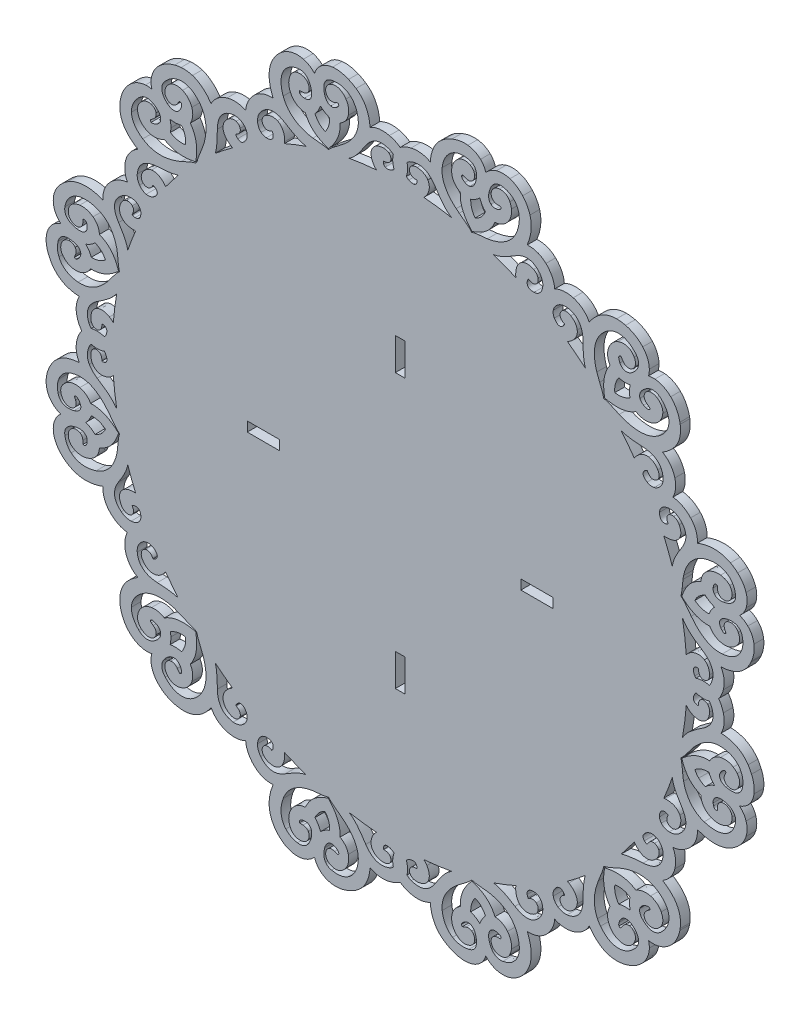
SolidWorks part; units mm, degrees
ref_plane "Plano frontal" through (0, 0, 0) normal (0, 0, 1) x (1, 0, 0)
ref_plane "Plano superior" through (0, 0, 0) normal (0, 1, 0) x (1, 0, 0)
ref_plane "Plano direito" through (0, 0, 0) normal (1, 0, 0) x (0, 0, -1)
sketch "Model" plane through (0, 0, 0) normal (0, 0, 1) x (1, 0, 0)
  line L74 (25, 43.0285) -> (31.6667, 43.0285)
  line L75 (31.6667, 43.0285) -> (31.6667, 45.0285)
  line L76 (31.6667, 45.0285) -> (25, 45.0285)
  line L77 (25, 45.0285) -> (25, 43.0285)
  line L78 (1, 69.0285) -> (1, 75.6952)
  line L79 (1, 75.6952) -> (-1, 75.6952)
  line L80 (-1, 75.6952) -> (-1, 69.0285)
  line L81 (-1, 69.0285) -> (1, 69.0285)
  line L82 (-31.6667, 43.0285) -> (-25, 43.0285)
  line L83 (-25, 43.0285) -> (-25, 45.0285)
  line L84 (-25, 45.0285) -> (-31.6667, 45.0285)
  line L85 (-31.6667, 45.0285) -> (-31.6667, 43.0285)
  line L86 (1, 12.3619) -> (1, 19.0285)
  line L87 (1, 19.0285) -> (-1, 19.0285)
  line L88 (-1, 19.0285) -> (-1, 12.3619)
  line L89 (-1, 12.3619) -> (1, 12.3619)
  line L90 (69.8972, 19.5023) -> (69.8918, 19.4975)
  line L91 (69.8918, 19.4975) -> (69.8863, 19.4928)
  line L92 (56.8895, 8.9763) -> (56.8876, 8.9686)
  line L93 (46.6898, -13.307) -> (46.6802, -13.3095)
  line L94 (46.6802, -13.3095) -> (46.6705, -13.3115)
  line L95 (35.8472, -12.8186) -> (35.8376, -12.8213)
  line L96 (30.1967, -16.1508) -> (30.1907, -16.1565)
  line L97 (9.1345, -27.8783) -> (9.1262, -27.8727)
  line L98 (-9.1262, -27.8727) -> (-9.1345, -27.8783)
  line L99 (-30.1907, -16.1565) -> (-30.1967, -16.1508)
  line L100 (-35.8377, -12.8213) -> (-35.8473, -12.8186)
  line L101 (-44.8207, -13.547) -> (-44.8319, -13.547)
  line L102 (-46.6802, -13.3094) -> (-46.6898, -13.307)
  line L103 (-56.8876, 8.9686) -> (-56.8895, 8.9763)
  line L104 (-72.7705, 33.8855) -> (-72.6371, 34.1796)
  line L105 (-69.8972, 68.5547) -> (-69.8918, 68.5596)
  line L106 (-69.8918, 68.5596) -> (-69.8863, 68.5642)
  line L107 (-56.8895, 79.0808) -> (-56.8876, 79.0885)
  line L108 (-46.6898, 101.364) -> (-46.6802, 101.3665)
  line L109 (-46.6802, 101.3665) -> (-46.6706, 101.3685)
  line L110 (-35.8473, 100.8757) -> (-35.8377, 100.8784)
  line L111 (-30.1967, 104.2078) -> (-30.1907, 104.2136)
  line L112 (-9.1345, 115.9354) -> (-9.1262, 115.9298)
  line L113 (9.1262, 115.9298) -> (9.1345, 115.9354)
  line L114 (30.1907, 104.2136) -> (30.1967, 104.2078)
  line L115 (35.8376, 100.8784) -> (35.8472, 100.8757)
  line L116 (44.8207, 101.604) -> (44.832, 101.604)
  line L117 (46.6801, 101.3664) -> (46.6897, 101.364)
  line L118 (56.8876, 79.0885) -> (56.8895, 79.0808)
  line L119 (72.7705, 54.1715) -> (72.6371, 53.8775)
  line L120 (64.4726, 46.2119) -> (64.4757, 46.2196)
  line L121 (61.7887, 47.2218) -> (61.7891, 47.2292)
  line L122 (61.7891, 47.2292) -> (61.7897, 47.2366)
  line L123 (64.4757, 41.8374) -> (64.4726, 41.8451)
  line L124 (61.7897, 40.8204) -> (61.7891, 40.8278)
  line L125 (61.7891, 40.8278) -> (61.7887, 40.8352)
  line L126 (38.2715, 89.7733) -> (38.2692, 89.7814)
  line L127 (50.44, 88.8997) -> (50.4487, 88.895)
  line L128 (51.187, 89.4362) -> (51.165, 89.4489)
  line L129 (51.165, 89.4489) -> (51.1448, 89.4641)
  line L130 (42.6296, 86.0985) -> (42.3541, 86.1577)
  line L131 (42.3541, 86.1577) -> (42.3064, 86.4358)
  line L132 (46.1649, 94.6497) -> (46.1614, 94.6547)
  line L133 (46.1614, 94.6547) -> (46.1581, 94.6598)
  line L134 (26.6751, 99.5281) -> (26.6693, 99.5316)
  line L135 (26.6693, 99.5316) -> (26.6637, 99.5354)
  line L136 (23.7768, 102.3668) -> (23.768, 102.3614)
  line L137 (51.2568, 77.4117) -> (51.2534, 77.4192)
  line L138 (50.5912, 77.1962) -> (50.5865, 77.1911)
  line L139 (50.5865, 77.1911) -> (50.5816, 77.1861)
  line L140 (50.5816, 10.871) -> (50.5865, 10.866)
  line L141 (50.5865, 10.866) -> (50.5912, 10.8608)
  line L142 (51.2534, 10.6378) -> (51.2568, 10.6454)
  line L143 (46.1581, -6.6028) -> (46.1614, -6.5977)
  line L144 (46.1614, -6.5977) -> (46.1649, -6.5927)
  line L145 (42.3064, 1.6213) -> (42.3541, 1.8994)
  line L146 (42.3541, 1.8994) -> (42.6296, 1.9586)
  line L147 (51.1448, -1.4071) -> (51.165, -1.3918)
  line L148 (51.165, -1.3918) -> (51.187, -1.3791)
  line L149 (50.4487, -0.8379) -> (50.44, -0.8427)
  line L150 (38.2692, -1.7243) -> (38.2715, -1.7163)
  line L151 (23.768, -14.3043) -> (23.7768, -14.3097)
  line L152 (26.6637, -11.4784) -> (26.6693, -11.4746)
  line L153 (26.6693, -11.4746) -> (26.6751, -11.471)
  line L154 (-26.6751, -11.471) -> (-26.6694, -11.4746)
  line L155 (-26.6694, -11.4746) -> (-26.6637, -11.4783)
  line L156 (-23.7768, -14.3097) -> (-23.768, -14.3043)
  line L157 (-38.2715, -1.7163) -> (-38.2693, -1.7243)
  line L158 (-50.4401, -0.8427) -> (-50.4487, -0.8379)
  line L159 (-51.1869, -1.3792) -> (-51.165, -1.3919)
  line L160 (-51.165, -1.3919) -> (-51.1448, -1.4071)
  line L161 (-42.6296, 1.9586) -> (-42.354, 1.8994)
  line L162 (-42.354, 1.8994) -> (-42.3063, 1.6213)
  line L163 (-46.1649, -6.5927) -> (-46.1614, -6.5977)
  line L164 (-46.1614, -6.5977) -> (-46.1581, -6.6028)
  line L165 (-51.2568, 10.6454) -> (-51.2534, 10.6378)
  line L166 (-50.5912, 10.8608) -> (-50.5865, 10.866)
  line L167 (-50.5865, 10.866) -> (-50.5816, 10.871)
  line L168 (-61.7887, 40.8352) -> (-61.7891, 40.8278)
  line L169 (-61.7891, 40.8278) -> (-61.7897, 40.8204)
  line L170 (-64.4725, 41.8452) -> (-64.4756, 41.8374)
  line L171 (-64.4756, 46.2196) -> (-64.4725, 46.2119)
  line L172 (-61.7897, 47.2366) -> (-61.7891, 47.2292)
  line L173 (-61.7891, 47.2292) -> (-61.7887, 47.2218)
  line L174 (-50.5816, 77.1861) -> (-50.5865, 77.1911)
  line L175 (-50.5865, 77.1911) -> (-50.5912, 77.1962)
  line L176 (-51.2534, 77.4192) -> (-51.2568, 77.4117)
  line L177 (-42.3063, 86.4358) -> (-42.354, 86.1577)
  line L178 (-42.354, 86.1577) -> (-42.6296, 86.0985)
  line L179 (-51.1448, 89.4641) -> (-51.165, 89.4489)
  line L180 (-51.165, 89.4489) -> (-51.1869, 89.4362)
  line L181 (-50.4487, 88.895) -> (-50.4401, 88.8998)
  line L182 (-46.1581, 94.6598) -> (-46.1614, 94.6547)
  line L183 (-46.1614, 94.6547) -> (-46.1649, 94.6497)
  line L184 (-38.2693, 89.7813) -> (-38.2715, 89.7733)
  line L185 (-23.7681, 102.3614) -> (-23.7768, 102.3668)
  line L186 (-26.6637, 99.5354) -> (-26.6694, 99.5316)
  line L187 (-26.6694, 99.5316) -> (-26.6751, 99.5281)
  line L188 (-15.121, -14.3281) -> (-14.8597, -14.242)
  line L189 (-14.8597, -14.242) -> (-14.678, -14.4488)
  line L190 (-11.5918, -16.7006) -> (-11.5991, -16.6943)
  line L191 (-23.6786, -24.1591) -> (-23.6743, -24.1638)
  line L192 (-23.6743, -24.1638) -> (-23.6701, -24.1687)
  line L193 (-20.5859, -21.6632) -> (-20.5794, -21.6634)
  line L194 (-20.5794, -21.6634) -> (-20.573, -21.6638)
  line L195 (-20.1427, -21.6791) -> (-20.1242, -21.6783)
  line L196 (-20.1242, -21.6783) -> (-20.1058, -21.6792)
  line L197 (-23.0532, -22.3529) -> (-23.0546, -22.3443)
  line L198 (-23.0546, -22.3443) -> (-23.0557, -22.3357)
  line L199 (-58.5333, 29.7012) -> (-58.324, 29.5177)
  line L200 (-58.324, 29.5177) -> (-58.4129, 29.2538)
  line L201 (-70.6735, 33.0875) -> (-70.6778, 33.0773)
  line L202 (-67.2324, 30.979) -> (-67.2247, 30.9644)
  line L203 (-67.2247, 30.9644) -> (-67.2183, 30.9492)
  line L204 (14.6779, -14.4488) -> (14.8597, -14.242)
  line L205 (14.8597, -14.242) -> (15.1209, -14.3281)
  line L206 (23.0556, -22.3358) -> (23.0546, -22.3443)
  line L207 (23.0546, -22.3443) -> (23.0531, -22.3528)
  line L208 (20.1057, -21.6792) -> (20.1242, -21.6783)
  line L209 (20.1242, -21.6783) -> (20.1427, -21.6791)
  line L210 (20.573, -21.6638) -> (20.5794, -21.6634)
  line L211 (20.5794, -21.6634) -> (20.5859, -21.6632)
  line L212 (23.6701, -24.1687) -> (23.6743, -24.1638)
  line L213 (23.6743, -24.1638) -> (23.6786, -24.1591)
  line L214 (11.6064, -16.6877) -> (11.5993, -16.6943)
  line L215 (11.5993, -16.6943) -> (11.5918, -16.7006)
  line L216 (58.4129, 29.2538) -> (58.324, 29.5177)
  line L217 (58.324, 29.5177) -> (58.5333, 29.7012)
  line L218 (67.2183, 30.9492) -> (67.2247, 30.9644)
  line L219 (67.2247, 30.9644) -> (67.2324, 30.979)
  line L220 (70.6778, 33.0773) -> (70.6735, 33.0875)
  line L221 (-23.6701, 112.2258) -> (-23.6743, 112.2209)
  line L222 (-23.6743, 112.2209) -> (-23.6786, 112.2162)
  line L223 (-11.5991, 104.7513) -> (-11.5918, 104.7577)
  line L224 (-14.678, 102.5059) -> (-14.8597, 102.2991)
  line L225 (-14.8597, 102.2991) -> (-15.121, 102.3852)
  line L226 (-23.0557, 110.3927) -> (-23.0546, 110.4014)
  line L227 (-23.0546, 110.4014) -> (-23.0532, 110.4099)
  line L228 (-20.1058, 109.7362) -> (-20.1242, 109.7354)
  line L229 (-20.1242, 109.7354) -> (-20.1427, 109.7361)
  line L230 (-20.5728, 109.7208) -> (-20.5793, 109.7204)
  line L231 (-20.5793, 109.7204) -> (-20.5859, 109.7202)
  line L232 (-58.4129, 58.8032) -> (-58.324, 58.5393)
  line L233 (-58.324, 58.5393) -> (-58.5333, 58.3559)
  line L234 (-67.2183, 57.1078) -> (-67.2247, 57.0927)
  line L235 (-67.2247, 57.0927) -> (-67.2324, 57.078)
  line L236 (-70.6778, 54.9798) -> (-70.6735, 54.9696)
  line L237 (11.5918, 104.7577) -> (11.5993, 104.7514)
  line L238 (11.5993, 104.7514) -> (11.6064, 104.7447)
  line L239 (23.6786, 112.2162) -> (23.6743, 112.2209)
  line L240 (23.6743, 112.2209) -> (23.6701, 112.2258)
  line L241 (20.5859, 109.7202) -> (20.5793, 109.7204)
  line L242 (20.5793, 109.7204) -> (20.5728, 109.7208)
  line L243 (20.1427, 109.7361) -> (20.1242, 109.7354)
  line L244 (20.1242, 109.7354) -> (20.1057, 109.7362)
  line L245 (23.0531, 110.4099) -> (23.0546, 110.4013)
  line L246 (23.0546, 110.4013) -> (23.0556, 110.3928)
  line L247 (15.1209, 102.3852) -> (14.8597, 102.2991)
  line L248 (14.8597, 102.2991) -> (14.6779, 102.5059)
  line L249 (58.5333, 58.3559) -> (58.324, 58.5393)
  line L250 (58.324, 58.5393) -> (58.4129, 58.8032)
  line L251 (70.6735, 54.9696) -> (70.6778, 54.9798)
  line L252 (67.2324, 57.078) -> (67.2247, 57.0927)
  line L253 (67.2247, 57.0927) -> (67.2183, 57.1078)
  spline S394 degree 3 poles (65.9479, 44.0285) (66.4183, 43.4213) (66.7428, 42.7001) (66.9323, 41.9588) knots 0 0 0 0 0.005128 0.005128 0.005128 0.005128
  spline S395 degree 3 poles (66.9323, 41.9588) (67.2822, 40.591) (67.1098, 39.2705) (66.4568, 38.0815) knots 0.005128 0.005128 0.005128 0.005128 0.010256 0.010256 0.010256 0.010256
  spline S396 degree 3 poles (66.4568, 38.0815) (68.7071, 37.9812) (70.7348, 37.1991) (72.0623, 35.2124) knots 0.010256 0.010256 0.010256 0.010256 0.015385 0.015385 0.015385 0.015385
  spline S397 degree 3 poles (72.0623, 35.2124) (72.3387, 34.7989) (72.5701, 34.3413) (72.7703, 33.8859) knots 0.015385 0.015385 0.015385 0.015385 0.020513 0.020513 0.020513 0.020513
  spline S398 degree 3 poles (72.7703, 33.8859) (73.2216, 32.8596) (73.4387, 31.7165) (73.2834, 30.599) knots 0.020513 0.020513 0.020513 0.020513 0.025641 0.025641 0.025641 0.025641
  spline S399 degree 3 poles (73.2834, 30.599) (73.1459, 29.6093) (72.7216, 28.6851) (72.0091, 27.9791) knots 0.025641 0.025641 0.025641 0.025641 0.030769 0.030769 0.030769 0.030769
  spline S400 degree 3 poles (72.0091, 27.9791) (71.5182, 27.4926) (70.9314, 27.1499) (70.2908, 26.9458) knots 0.030769 0.030769 0.030769 0.030769 0.035897 0.035897 0.035897 0.035897
  spline S401 degree 3 poles (70.2908, 26.9458) (70.9135, 26.4084) (71.3874, 25.7215) (71.6445, 24.9159) knots 0.035897 0.035897 0.035897 0.035897 0.041026 0.041026 0.041026 0.041026
  spline S402 degree 3 poles (71.6445, 24.9159) (71.9334, 24.0106) (71.9163, 23.0508) (71.6374, 22.1455) knots 0.041026 0.041026 0.041026 0.041026 0.046154 0.046154 0.046154 0.046154
  spline S403 degree 3 poles (71.6374, 22.1455) (71.3202, 21.1163) (70.689, 20.2222) (69.8972, 19.5023) knots 0.046154 0.046154 0.046154 0.046154 0.051282 0.051282 0.051282 0.051282
  spline S404 degree 3 poles (69.8863, 19.4928) (69.5633, 19.219) (69.2343, 18.9577) (68.8791, 18.7266) knots 0.061538 0.061538 0.061538 0.061538 0.066667 0.066667 0.066667 0.066667
  spline S405 degree 3 poles (68.8791, 18.7266) (66.5989, 17.2429) (63.9695, 17.4256) (61.5438, 18.3545) knots 0.066667 0.066667 0.066667 0.066667 0.071795 0.071795 0.071795 0.071795
  spline S406 degree 3 poles (61.5438, 18.3545) (61.6574, 16.9207) (61.1757, 15.6086) (60.1553, 14.5087) knots 0.071795 0.071795 0.071795 0.071795 0.076923 0.076923 0.076923 0.076923
  spline S407 degree 3 poles (60.1553, 14.5087) (59.1998, 13.4786) (57.8934, 12.7502) (56.4956, 12.6147) knots 0.076923 0.076923 0.076923 0.076923 0.082051 0.082051 0.082051 0.082051
  spline S408 degree 3 poles (56.4956, 12.6147) (57.0761, 11.5092) (57.1743, 10.2051) (56.8895, 8.9763) knots 0.082051 0.082051 0.082051 0.082051 0.087179 0.087179 0.087179 0.087179
  spline S409 degree 3 poles (56.8876, 8.9686) (56.5142, 7.4863) (55.6, 6.3587) (54.3314, 5.615) knots 0.092308 0.092308 0.092308 0.092308 0.097436 0.097436 0.097436 0.097436
  spline S410 degree 3 poles (54.3314, 5.615) (56.8461, 4.1173) (58.4258, 1.9374) (57.9927, -1.1956) knots 0.097436 0.097436 0.097436 0.097436 0.102564 0.102564 0.102564 0.102564
  spline S411 degree 3 poles (57.9927, -1.1956) (57.9764, -1.3134) (57.9578, -1.4303) (57.9349, -1.547) knots 0.102564 0.102564 0.102564 0.102564 0.107692 0.107692 0.107692 0.107692
  spline S412 degree 3 poles (57.9349, -1.547) (57.6685, -2.9069) (57.0319, -4.1828) (56.0338, -5.1517) knots 0.107692 0.107692 0.107692 0.107692 0.112821 0.112821 0.112821 0.112821
  spline S413 degree 3 poles (56.0338, -5.1517) (55.1458, -6.0136) (54.0014, -6.5944) (52.7597, -6.6914) knots 0.112821 0.112821 0.112821 0.112821 0.117949 0.117949 0.117949 0.117949
  spline S414 degree 3 poles (52.7597, -6.6914) (52.3148, -6.7262) (51.8705, -6.6967) (51.4382, -6.6052) knots 0.117949 0.117949 0.117949 0.117949 0.123077 0.123077 0.123077 0.123077
  spline S415 degree 3 poles (51.4382, -6.6052) (51.5555, -7.0208) (51.6126, -7.4523) (51.6051, -7.8889) knots 0.123077 0.123077 0.123077 0.123077 0.128205 0.128205 0.128205 0.128205
  spline S416 degree 3 poles (51.6051, -7.8889) (51.584, -9.1282) (51.057, -10.2871) (50.2418, -11.2051) knots 0.128205 0.128205 0.128205 0.128205 0.133333 0.133333 0.133333 0.133333
  spline S417 degree 3 poles (50.2418, -11.2051) (49.3081, -12.2566) (48.042, -12.9561) (46.6898, -13.307) knots 0.133333 0.133333 0.133333 0.133333 0.138462 0.138462 0.138462 0.138462
  spline S418 degree 3 poles (46.6705, -13.3115) (46.2426, -13.4011) (45.8132, -13.4855) (45.377, -13.5221) knots 0.148718 0.148718 0.148718 0.148718 0.153846 0.153846 0.153846 0.153846
  spline S419 degree 3 poles (45.377, -13.5221) (44.5738, -13.5896) (43.7775, -13.5108) (43.0091, -13.2638) knots 0.153846 0.153846 0.153846 0.153846 0.158974 0.158974 0.158974 0.158974
  spline S420 degree 3 poles (43.0091, -13.2638) (41.3664, -12.7359) (40.1103, -11.5309) (39.1596, -10.1314) knots 0.158974 0.158974 0.158974 0.158974 0.164103 0.164103 0.164103 0.164103
  spline S421 degree 3 poles (39.1596, -10.1314) (38.4629, -11.4553) (37.3363, -12.3792) (35.8472, -12.8186) knots 0.164103 0.164103 0.164103 0.164103 0.169231 0.169231 0.169231 0.169231
  spline S422 degree 3 poles (35.8376, -12.8213) (34.5562, -13.1664) (33.172, -13.0953) (32.0038, -12.4896) knots 0.174359 0.174359 0.174359 0.174359 0.179487 0.179487 0.179487 0.179487
  spline S423 degree 3 poles (32.0038, -12.4896) (31.9069, -13.8797) (31.2012, -15.1828) (30.1967, -16.1508) knots 0.179487 0.179487 0.179487 0.179487 0.184615 0.184615 0.184615 0.184615
  spline S424 degree 3 poles (30.1907, -16.1565) (29.082, -17.1829) (27.7537, -17.6395) (26.3134, -17.5282) knots 0.189744 0.189744 0.189744 0.189744 0.194872 0.194872 0.194872 0.194872
  spline S425 degree 3 poles (26.3134, -17.5282) (27.4619, -20.2821) (27.5931, -23.1343) (25.5995, -25.6097) knots 0.194872 0.194872 0.194872 0.194872 0.2 0.2 0.2 0.2
  spline S426 degree 3 poles (25.5995, -25.6097) (24.26, -27.273) (22.1602, -28.2475) (20.0334, -27.6755) knots 0.2 0.2 0.2 0.2 0.205128 0.205128 0.205128 0.205128
  spline S427 degree 3 poles (20.0334, -27.6755) (19.126, -27.4314) (18.3456, -26.9298) (17.7384, -26.246) knots 0.205128 0.205128 0.205128 0.205128 0.210256 0.210256 0.210256 0.210256
  spline S428 degree 3 poles (17.7384, -26.246) (17.5342, -26.926) (17.1733, -27.5461) (16.6484, -28.0554) knots 0.210256 0.210256 0.210256 0.210256 0.215385 0.215385 0.215385 0.215385
  spline S429 degree 3 poles (16.6484, -28.0554) (15.9325, -28.7501) (15.0047, -29.147) (14.0208, -29.2658) knots 0.215385 0.215385 0.215385 0.215385 0.220513 0.220513 0.220513 0.220513
  spline S430 degree 3 poles (14.0208, -29.2658) (12.8882, -29.4026) (11.7407, -29.1695) (10.7014, -28.7165) knots 0.220513 0.220513 0.220513 0.220513 0.225641 0.225641 0.225641 0.225641
  spline S431 degree 3 poles (10.7014, -28.7165) (10.1478, -28.4751) (9.6401, -28.2083) (9.1345, -27.8783) knots 0.225641 0.225641 0.225641 0.225641 0.230769 0.230769 0.230769 0.230769
  spline S432 degree 3 poles (9.1262, -27.8727) (7.2078, -26.5536) (6.3815, -24.5833) (6.236, -22.3635) knots 0.235897 0.235897 0.235897 0.235897 0.241026 0.241026 0.241026 0.241026
  spline S433 degree 3 poles (6.236, -22.3635) (5.0092, -23.041) (3.6434, -23.2154) (2.2461, -22.8707) knots 0.241026 0.241026 0.241026 0.241026 0.246154 0.246154 0.246154 0.246154
  spline S434 degree 3 poles (2.2461, -22.8707) (1.447, -22.694) (0.6568, -22.3689) (0, -21.8713) knots 0.246154 0.246154 0.246154 0.246154 0.251282 0.251282 0.251282 0.251282
  spline S435 degree 3 poles (0, -21.8713) (-0.6567, -22.3688) (-1.4458, -22.6937) (-2.2363, -22.8684) knots 0.251282 0.251282 0.251282 0.251282 0.25641 0.25641 0.25641 0.25641
  spline S436 degree 3 poles (-2.2363, -22.8684) (-3.6419, -23.215) (-5.009, -23.0409) (-6.236, -22.3635) knots 0.25641 0.25641 0.25641 0.25641 0.261538 0.261538 0.261538 0.261538
  spline S437 degree 3 poles (-6.236, -22.3635) (-6.3815, -24.5833) (-7.2078, -26.5536) (-9.1262, -27.8727) knots 0.261538 0.261538 0.261538 0.261538 0.266667 0.266667 0.266667 0.266667
  spline S438 degree 3 poles (-9.1345, -27.8783) (-9.6401, -28.2083) (-10.1478, -28.4751) (-10.7014, -28.7165) knots 0.271795 0.271795 0.271795 0.271795 0.276923 0.276923 0.276923 0.276923
  spline S439 degree 3 poles (-10.7014, -28.7165) (-11.7407, -29.1695) (-12.8881, -29.4026) (-14.0208, -29.2658) knots 0.276923 0.276923 0.276923 0.276923 0.282051 0.282051 0.282051 0.282051
  spline S440 degree 3 poles (-14.0208, -29.2658) (-15.0046, -29.147) (-15.9324, -28.7501) (-16.6483, -28.0554) knots 0.282051 0.282051 0.282051 0.282051 0.287179 0.287179 0.287179 0.287179
  spline S441 degree 3 poles (-16.6483, -28.0554) (-17.1733, -27.546) (-17.5342, -26.9258) (-17.7385, -26.2457) knots 0.287179 0.287179 0.287179 0.287179 0.292308 0.292308 0.292308 0.292308
  spline S442 degree 3 poles (-17.7385, -26.2457) (-18.321, -26.9013) (-19.0641, -27.3919) (-19.9251, -27.6479) knots 0.292308 0.292308 0.292308 0.292308 0.297436 0.297436 0.297436 0.297436
  spline S443 degree 3 poles (-19.9251, -27.6479) (-20.8455, -27.9217) (-21.8174, -27.9007) (-22.7328, -27.6174) knots 0.297436 0.297436 0.297436 0.297436 0.302564 0.302564 0.302564 0.302564
  spline S444 degree 3 poles (-22.7328, -27.6174) (-23.7606, -27.2993) (-24.6529, -26.6742) (-25.3688, -25.8769) knots 0.302564 0.302564 0.302564 0.302564 0.307692 0.307692 0.307692 0.307692
  spline S445 degree 3 poles (-25.3688, -25.8769) (-26.0709, -25.095) (-26.5959, -24.1974) (-26.886, -23.1842) knots 0.307692 0.307692 0.307692 0.307692 0.312821 0.312821 0.312821 0.312821
  spline S446 degree 3 poles (-26.886, -23.1842) (-27.4299, -21.2843) (-27.0576, -19.3155) (-26.3132, -17.5282) knots 0.312821 0.312821 0.312821 0.312821 0.317949 0.317949 0.317949 0.317949
  spline S447 degree 3 poles (-26.3132, -17.5282) (-27.7536, -17.6396) (-29.082, -17.183) (-30.1907, -16.1565) knots 0.317949 0.317949 0.317949 0.317949 0.323077 0.323077 0.323077 0.323077
  spline S448 degree 3 poles (-30.1967, -16.1508) (-31.2012, -15.1828) (-31.9069, -13.8797) (-32.0038, -12.4896) knots 0.328205 0.328205 0.328205 0.328205 0.333333 0.333333 0.333333 0.333333
  spline S449 degree 3 poles (-32.0038, -12.4896) (-33.172, -13.0953) (-34.5563, -13.1664) (-35.8377, -12.8213) knots 0.333333 0.333333 0.333333 0.333333 0.338462 0.338462 0.338462 0.338462
  spline S450 degree 3 poles (-35.8473, -12.8186) (-37.3363, -12.3792) (-38.4628, -11.4553) (-39.1596, -10.1315) knots 0.34359 0.34359 0.34359 0.34359 0.348718 0.348718 0.348718 0.348718
  spline S451 degree 3 poles (-39.1596, -10.1315) (-40.4907, -12.0919) (-42.3201, -13.5219) (-44.8207, -13.547) knots 0.348718 0.348718 0.348718 0.348718 0.353846 0.353846 0.353846 0.353846
  spline S452 degree 3 poles (-44.8319, -13.547) (-45.4723, -13.5361) (-46.0561, -13.4556) (-46.6802, -13.3094) knots 0.358974 0.358974 0.358974 0.358974 0.364103 0.364103 0.364103 0.364103
  spline S453 degree 3 poles (-46.6898, -13.307) (-48.042, -12.9561) (-49.3082, -12.2566) (-50.2418, -11.2051) knots 0.369231 0.369231 0.369231 0.369231 0.374359 0.374359 0.374359 0.374359
  spline S454 degree 3 poles (-50.2418, -11.2051) (-51.057, -10.2871) (-51.584, -9.1282) (-51.6051, -7.889) knots 0.374359 0.374359 0.374359 0.374359 0.379487 0.379487 0.379487 0.379487
  spline S455 degree 3 poles (-51.6051, -7.889) (-51.6126, -7.4523) (-51.5555, -7.0208) (-51.4382, -6.6052) knots 0.379487 0.379487 0.379487 0.379487 0.384615 0.384615 0.384615 0.384615
  spline S456 degree 3 poles (-51.4382, -6.6052) (-51.8705, -6.6967) (-52.3149, -6.7262) (-52.7597, -6.6914) knots 0.384615 0.384615 0.384615 0.384615 0.389744 0.389744 0.389744 0.389744
  spline S457 degree 3 poles (-52.7597, -6.6914) (-54.0014, -6.5943) (-55.1458, -6.0136) (-56.0338, -5.1517) knots 0.389744 0.389744 0.389744 0.389744 0.394872 0.394872 0.394872 0.394872
  spline S458 degree 3 poles (-56.0338, -5.1517) (-57.0319, -4.1828) (-57.6685, -2.9068) (-57.9348, -1.547) knots 0.394872 0.394872 0.394872 0.394872 0.4 0.4 0.4 0.4
  spline S459 degree 3 poles (-57.9348, -1.547) (-57.9577, -1.4303) (-57.9765, -1.3134) (-57.9928, -1.1956) knots 0.4 0.4 0.4 0.4 0.405128 0.405128 0.405128 0.405128
  spline S460 degree 3 poles (-57.9928, -1.1956) (-58.4258, 1.9373) (-56.8461, 4.1173) (-54.3314, 5.615) knots 0.405128 0.405128 0.405128 0.405128 0.410256 0.410256 0.410256 0.410256
  spline S461 degree 3 poles (-54.3314, 5.615) (-55.6, 6.3587) (-56.5142, 7.4863) (-56.8876, 8.9686) knots 0.410256 0.410256 0.410256 0.410256 0.415385 0.415385 0.415385 0.415385
  spline S462 degree 3 poles (-56.8895, 8.9763) (-57.1743, 10.2051) (-57.076, 11.5092) (-56.4956, 12.6147) knots 0.420513 0.420513 0.420513 0.420513 0.425641 0.425641 0.425641 0.425641
  spline S463 degree 3 poles (-56.4956, 12.6147) (-57.8934, 12.7502) (-59.1998, 13.4786) (-60.1553, 14.5087) knots 0.425641 0.425641 0.425641 0.425641 0.430769 0.430769 0.430769 0.430769
  spline S464 degree 3 poles (-60.1553, 14.5087) (-61.1756, 15.6086) (-61.6574, 16.9205) (-61.5438, 18.3543) knots 0.430769 0.430769 0.430769 0.430769 0.435897 0.435897 0.435897 0.435897
  spline S465 degree 3 poles (-61.5438, 18.3543) (-63.785, 17.4947) (-66.1964, 17.2708) (-68.3996, 18.4421) knots 0.435897 0.435897 0.435897 0.435897 0.441026 0.441026 0.441026 0.441026
  spline S466 degree 3 poles (-68.3996, 18.4421) (-68.9525, 18.7361) (-69.4317, 19.0813) (-69.8964, 19.5016) knots 0.441026 0.441026 0.441026 0.441026 0.446154 0.446154 0.446154 0.446154
  spline S467 degree 3 poles (-69.8964, 19.5016) (-70.6891, 20.2186) (-71.3208, 21.1103) (-71.6387, 22.1379) knots 0.446154 0.446154 0.446154 0.446154 0.451282 0.451282 0.451282 0.451282
  spline S468 degree 3 poles (-71.6387, 22.1379) (-71.9183, 23.0421) (-71.936, 24.001) (-71.6488, 24.9058) knots 0.451282 0.451282 0.451282 0.451282 0.45641 0.45641 0.45641 0.45641
  spline S469 degree 3 poles (-71.6488, 24.9058) (-71.3918, 25.7153) (-70.9162, 26.4059) (-70.2907, 26.9458) knots 0.45641 0.45641 0.45641 0.45641 0.461538 0.461538 0.461538 0.461538
  spline S470 degree 3 poles (-70.2907, 26.9458) (-70.9314, 27.1499) (-71.5182, 27.4926) (-72.0091, 27.9791) knots 0.461538 0.461538 0.461538 0.461538 0.466667 0.466667 0.466667 0.466667
  spline S471 degree 3 poles (-72.0091, 27.9791) (-72.7216, 28.685) (-73.1454, 29.6091) (-73.2826, 30.5987) knots 0.466667 0.466667 0.466667 0.466667 0.471795 0.471795 0.471795 0.471795
  spline S472 degree 3 poles (-73.2826, 30.5987) (-73.4375, 31.7161) (-73.2206, 32.8589) (-72.7705, 33.8855) knots 0.471795 0.471795 0.471795 0.471795 0.476923 0.476923 0.476923 0.476923
  spline S473 degree 3 poles (-72.6371, 34.1796) (-71.4341, 36.8305) (-69.1843, 37.9573) (-66.4566, 38.0812) knots 0.482051 0.482051 0.482051 0.482051 0.487179 0.487179 0.487179 0.487179
  spline S474 degree 3 poles (-66.4566, 38.0812) (-67.1097, 39.2703) (-67.2822, 40.5909) (-66.9323, 41.9588) knots 0.487179 0.487179 0.487179 0.487179 0.492308 0.492308 0.492308 0.492308
  spline S475 degree 3 poles (-66.9323, 41.9588) (-66.7428, 42.7001) (-66.4183, 43.4213) (-65.9479, 44.0285) knots 0.492308 0.492308 0.492308 0.492308 0.497436 0.497436 0.497436 0.497436
  spline S476 degree 3 poles (-65.9479, 44.0285) (-66.4183, 44.6357) (-66.7428, 45.3569) (-66.9323, 46.0982) knots 0.497436 0.497436 0.497436 0.497436 0.502564 0.502564 0.502564 0.502564
  spline S477 degree 3 poles (-66.9323, 46.0982) (-67.2822, 47.466) (-67.1097, 48.7865) (-66.4568, 49.9755) knots 0.502564 0.502564 0.502564 0.502564 0.507692 0.507692 0.507692 0.507692
  spline S478 degree 3 poles (-66.4568, 49.9755) (-68.7071, 50.0759) (-70.7348, 50.8579) (-72.0623, 52.8446) knots 0.507692 0.507692 0.507692 0.507692 0.512821 0.512821 0.512821 0.512821
  spline S479 degree 3 poles (-72.0623, 52.8446) (-72.3387, 53.2581) (-72.5701, 53.7158) (-72.7703, 54.1711) knots 0.512821 0.512821 0.512821 0.512821 0.517949 0.517949 0.517949 0.517949
  spline S480 degree 3 poles (-72.7703, 54.1711) (-73.2216, 55.1974) (-73.4387, 56.3405) (-73.2834, 57.458) knots 0.517949 0.517949 0.517949 0.517949 0.523077 0.523077 0.523077 0.523077
  spline S481 degree 3 poles (-73.2834, 57.458) (-73.1459, 58.4477) (-72.7216, 59.372) (-72.0091, 60.078) knots 0.523077 0.523077 0.523077 0.523077 0.528205 0.528205 0.528205 0.528205
  spline S482 degree 3 poles (-72.0091, 60.078) (-71.5182, 60.5644) (-70.9314, 60.9072) (-70.2908, 61.1112) knots 0.528205 0.528205 0.528205 0.528205 0.533333 0.533333 0.533333 0.533333
  spline S483 degree 3 poles (-70.2908, 61.1112) (-70.9135, 61.6487) (-71.3874, 62.3356) (-71.6445, 63.1412) knots 0.533333 0.533333 0.533333 0.533333 0.538462 0.538462 0.538462 0.538462
  spline S484 degree 3 poles (-71.6445, 63.1412) (-71.9334, 64.0464) (-71.9163, 65.0062) (-71.6373, 65.9116) knots 0.538462 0.538462 0.538462 0.538462 0.54359 0.54359 0.54359 0.54359
  spline S485 degree 3 poles (-71.6373, 65.9116) (-71.3202, 66.9408) (-70.689, 67.8348) (-69.8972, 68.5547) knots 0.54359 0.54359 0.54359 0.54359 0.548718 0.548718 0.548718 0.548718
  spline S486 degree 3 poles (-69.8863, 68.5642) (-69.5633, 68.8381) (-69.2342, 69.0994) (-68.8791, 69.3305) knots 0.558974 0.558974 0.558974 0.558974 0.564103 0.564103 0.564103 0.564103
  spline S487 degree 3 poles (-68.8791, 69.3305) (-66.599, 70.8141) (-63.9694, 70.6314) (-61.5438, 69.7025) knots 0.564103 0.564103 0.564103 0.564103 0.569231 0.569231 0.569231 0.569231
  spline S488 degree 3 poles (-61.5438, 69.7025) (-61.6574, 71.1364) (-61.1756, 72.4484) (-60.1553, 73.5483) knots 0.569231 0.569231 0.569231 0.569231 0.574359 0.574359 0.574359 0.574359
  spline S489 degree 3 poles (-60.1553, 73.5483) (-59.1998, 74.5784) (-57.8934, 75.3068) (-56.4956, 75.4424) knots 0.574359 0.574359 0.574359 0.574359 0.579487 0.579487 0.579487 0.579487
  spline S490 degree 3 poles (-56.4956, 75.4424) (-57.076, 76.5478) (-57.1743, 77.852) (-56.8895, 79.0808) knots 0.579487 0.579487 0.579487 0.579487 0.584615 0.584615 0.584615 0.584615
  spline S491 degree 3 poles (-56.8876, 79.0885) (-56.5142, 80.5707) (-55.6, 81.6983) (-54.3314, 82.442) knots 0.589744 0.589744 0.589744 0.589744 0.594872 0.594872 0.594872 0.594872
  spline S492 degree 3 poles (-54.3314, 82.442) (-56.8461, 83.9397) (-58.4258, 86.1197) (-57.9928, 89.2526) knots 0.594872 0.594872 0.594872 0.594872 0.6 0.6 0.6 0.6
  spline S493 degree 3 poles (-57.9928, 89.2526) (-57.9765, 89.3704) (-57.9577, 89.4874) (-57.9348, 89.6041) knots 0.6 0.6 0.6 0.6 0.605128 0.605128 0.605128 0.605128
  spline S494 degree 3 poles (-57.9348, 89.6041) (-57.6685, 90.9639) (-57.0319, 92.2398) (-56.0338, 93.2087) knots 0.605128 0.605128 0.605128 0.605128 0.610256 0.610256 0.610256 0.610256
  spline S495 degree 3 poles (-56.0338, 93.2087) (-55.1458, 94.0707) (-54.0014, 94.6514) (-52.7598, 94.7485) knots 0.610256 0.610256 0.610256 0.610256 0.615385 0.615385 0.615385 0.615385
  spline S496 degree 3 poles (-52.7598, 94.7485) (-52.3149, 94.7833) (-51.8705, 94.7538) (-51.4382, 94.6623) knots 0.615385 0.615385 0.615385 0.615385 0.620513 0.620513 0.620513 0.620513
  spline S497 degree 3 poles (-51.4382, 94.6623) (-51.5556, 95.0779) (-51.6126, 95.5094) (-51.6051, 95.9461) knots 0.620513 0.620513 0.620513 0.620513 0.625641 0.625641 0.625641 0.625641
  spline S498 degree 3 poles (-51.6051, 95.9461) (-51.584, 97.1853) (-51.0569, 98.3443) (-50.2418, 99.2622) knots 0.625641 0.625641 0.625641 0.625641 0.630769 0.630769 0.630769 0.630769
  spline S499 degree 3 poles (-50.2418, 99.2622) (-49.3081, 100.3137) (-48.042, 101.0132) (-46.6898, 101.364) knots 0.630769 0.630769 0.630769 0.630769 0.635897 0.635897 0.635897 0.635897
  spline S500 degree 3 poles (-46.6706, 101.3685) (-46.2426, 101.4581) (-45.8132, 101.5425) (-45.377, 101.5791) knots 0.646154 0.646154 0.646154 0.646154 0.651282 0.651282 0.651282 0.651282
  spline S501 degree 3 poles (-45.377, 101.5791) (-44.5738, 101.6466) (-43.7775, 101.5678) (-43.0091, 101.3209) knots 0.651282 0.651282 0.651282 0.651282 0.65641 0.65641 0.65641 0.65641
  spline S502 degree 3 poles (-43.0091, 101.3209) (-41.3664, 100.7929) (-40.1103, 99.5879) (-39.1596, 98.1884) knots 0.65641 0.65641 0.65641 0.65641 0.661538 0.661538 0.661538 0.661538
  spline S503 degree 3 poles (-39.1596, 98.1884) (-38.4629, 99.5123) (-37.3364, 100.4362) (-35.8473, 100.8757) knots 0.661538 0.661538 0.661538 0.661538 0.666667 0.666667 0.666667 0.666667
  spline S504 degree 3 poles (-35.8377, 100.8784) (-34.5563, 101.2234) (-33.172, 101.1523) (-32.0038, 100.5466) knots 0.671795 0.671795 0.671795 0.671795 0.676923 0.676923 0.676923 0.676923
  spline S505 degree 3 poles (-32.0038, 100.5466) (-31.9069, 101.9367) (-31.2012, 103.2399) (-30.1967, 104.2078) knots 0.676923 0.676923 0.676923 0.676923 0.682051 0.682051 0.682051 0.682051
  spline S506 degree 3 poles (-30.1907, 104.2136) (-29.082, 105.2399) (-27.7537, 105.6966) (-26.3134, 105.5852) knots 0.687179 0.687179 0.687179 0.687179 0.692308 0.692308 0.692308 0.692308
  spline S507 degree 3 poles (-26.3134, 105.5852) (-27.4618, 108.3392) (-27.593, 111.1912) (-25.5995, 113.6667) knots 0.692308 0.692308 0.692308 0.692308 0.697436 0.697436 0.697436 0.697436
  spline S508 degree 3 poles (-25.5995, 113.6667) (-24.26, 115.3302) (-22.1599, 116.3047) (-20.0331, 115.7324) knots 0.697436 0.697436 0.697436 0.697436 0.702564 0.702564 0.702564 0.702564
  spline S509 degree 3 poles (-20.0331, 115.7324) (-19.1258, 115.4883) (-18.3455, 114.9867) (-17.7384, 114.3031) knots 0.702564 0.702564 0.702564 0.702564 0.707692 0.707692 0.707692 0.707692
  spline S510 degree 3 poles (-17.7384, 114.3031) (-17.5341, 114.983) (-17.1733, 115.6032) (-16.6483, 116.1125) knots 0.707692 0.707692 0.707692 0.707692 0.712821 0.712821 0.712821 0.712821
  spline S511 degree 3 poles (-16.6483, 116.1125) (-15.9324, 116.8072) (-15.0046, 117.2041) (-14.0208, 117.3229) knots 0.712821 0.712821 0.712821 0.712821 0.717949 0.717949 0.717949 0.717949
  spline S512 degree 3 poles (-14.0208, 117.3229) (-12.8881, 117.4597) (-11.7407, 117.2266) (-10.7014, 116.7735) knots 0.717949 0.717949 0.717949 0.717949 0.723077 0.723077 0.723077 0.723077
  spline S513 degree 3 poles (-10.7014, 116.7735) (-10.1478, 116.5322) (-9.6401, 116.2653) (-9.1345, 115.9354) knots 0.723077 0.723077 0.723077 0.723077 0.728205 0.728205 0.728205 0.728205
  spline S514 degree 3 poles (-9.1262, 115.9298) (-7.2078, 114.6106) (-6.3815, 112.6403) (-6.236, 110.4206) knots 0.733333 0.733333 0.733333 0.733333 0.738462 0.738462 0.738462 0.738462
  spline S515 degree 3 poles (-6.236, 110.4206) (-5.0092, 111.098) (-3.6434, 111.2724) (-2.2461, 110.9278) knots 0.738462 0.738462 0.738462 0.738462 0.74359 0.74359 0.74359 0.74359
  spline S516 degree 3 poles (-2.2461, 110.9278) (-1.447, 110.7511) (-0.6568, 110.426) (0, 109.9284) knots 0.74359 0.74359 0.74359 0.74359 0.748718 0.748718 0.748718 0.748718
  spline S517 degree 3 poles (0, 109.9284) (0.6567, 110.426) (1.4457, 110.7508) (2.2363, 110.9255) knots 0.748718 0.748718 0.748718 0.748718 0.753846 0.753846 0.753846 0.753846
  spline S518 degree 3 poles (2.2363, 110.9255) (3.6419, 111.2721) (5.009, 111.098) (6.236, 110.4205) knots 0.753846 0.753846 0.753846 0.753846 0.758974 0.758974 0.758974 0.758974
  spline S519 degree 3 poles (6.236, 110.4205) (6.3815, 112.6403) (7.2078, 114.6106) (9.1262, 115.9298) knots 0.758974 0.758974 0.758974 0.758974 0.764103 0.764103 0.764103 0.764103
  spline S520 degree 3 poles (9.1345, 115.9354) (9.6401, 116.2653) (10.1478, 116.5322) (10.7014, 116.7735) knots 0.769231 0.769231 0.769231 0.769231 0.774359 0.774359 0.774359 0.774359
  spline S521 degree 3 poles (10.7014, 116.7735) (11.7407, 117.2267) (12.8881, 117.4597) (14.0208, 117.3229) knots 0.774359 0.774359 0.774359 0.774359 0.779487 0.779487 0.779487 0.779487
  spline S522 degree 3 poles (14.0208, 117.3229) (15.0047, 117.2041) (15.9325, 116.8072) (16.6484, 116.1125) knots 0.779487 0.779487 0.779487 0.779487 0.784615 0.784615 0.784615 0.784615
  spline S523 degree 3 poles (16.6484, 116.1125) (17.1734, 115.6031) (17.5343, 114.9829) (17.7385, 114.3028) knots 0.784615 0.784615 0.784615 0.784615 0.789744 0.789744 0.789744 0.789744
  spline S524 degree 3 poles (17.7385, 114.3028) (18.321, 114.9584) (19.0641, 115.4489) (19.925, 115.7049) knots 0.789744 0.789744 0.789744 0.789744 0.794872 0.794872 0.794872 0.794872
  spline S525 degree 3 poles (19.925, 115.7049) (20.8454, 115.9787) (21.8172, 115.9577) (22.7327, 115.6744) knots 0.794872 0.794872 0.794872 0.794872 0.8 0.8 0.8 0.8
  spline S526 degree 3 poles (22.7327, 115.6744) (23.7606, 115.3563) (24.6528, 114.7312) (25.3687, 113.934) knots 0.8 0.8 0.8 0.8 0.805128 0.805128 0.805128 0.805128
  spline S527 degree 3 poles (25.3687, 113.934) (26.0707, 113.1522) (26.5957, 112.2548) (26.8858, 111.2418) knots 0.805128 0.805128 0.805128 0.805128 0.810256 0.810256 0.810256 0.810256
  spline S528 degree 3 poles (26.8858, 111.2418) (27.4299, 109.3418) (27.0577, 107.3727) (26.3132, 105.5852) knots 0.810256 0.810256 0.810256 0.810256 0.815385 0.815385 0.815385 0.815385
  spline S529 degree 3 poles (26.3132, 105.5852) (27.7536, 105.6967) (29.082, 105.24) (30.1907, 104.2136) knots 0.815385 0.815385 0.815385 0.815385 0.820513 0.820513 0.820513 0.820513
  spline S530 degree 3 poles (30.1967, 104.2078) (31.2012, 103.2399) (31.9069, 101.9368) (32.0038, 100.5466) knots 0.825641 0.825641 0.825641 0.825641 0.830769 0.830769 0.830769 0.830769
  spline S531 degree 3 poles (32.0038, 100.5466) (33.172, 101.1523) (34.5562, 101.2234) (35.8376, 100.8784) knots 0.830769 0.830769 0.830769 0.830769 0.835897 0.835897 0.835897 0.835897
  spline S532 degree 3 poles (35.8472, 100.8757) (37.3363, 100.4363) (38.4629, 99.5123) (39.1596, 98.1885) knots 0.841026 0.841026 0.841026 0.841026 0.846154 0.846154 0.846154 0.846154
  spline S533 degree 3 poles (39.1596, 98.1885) (40.4907, 100.1489) (42.3201, 101.5789) (44.8207, 101.604) knots 0.846154 0.846154 0.846154 0.846154 0.851282 0.851282 0.851282 0.851282
  spline S534 degree 3 poles (44.832, 101.604) (45.4723, 101.5931) (46.0561, 101.5126) (46.6801, 101.3664) knots 0.85641 0.85641 0.85641 0.85641 0.861538 0.861538 0.861538 0.861538
  spline S535 degree 3 poles (46.6897, 101.364) (48.042, 101.0132) (49.3081, 100.3137) (50.2417, 99.2622) knots 0.866667 0.866667 0.866667 0.866667 0.871795 0.871795 0.871795 0.871795
  spline S536 degree 3 poles (50.2417, 99.2622) (51.0569, 98.3443) (51.584, 97.1853) (51.6051, 95.9461) knots 0.871795 0.871795 0.871795 0.871795 0.876923 0.876923 0.876923 0.876923
  spline S537 degree 3 poles (51.6051, 95.9461) (51.6126, 95.5094) (51.5556, 95.0778) (51.4382, 94.6623) knots 0.876923 0.876923 0.876923 0.876923 0.882051 0.882051 0.882051 0.882051
  spline S538 degree 3 poles (51.4382, 94.6623) (51.8705, 94.7538) (52.3149, 94.7833) (52.7597, 94.7485) knots 0.882051 0.882051 0.882051 0.882051 0.887179 0.887179 0.887179 0.887179
  spline S539 degree 3 poles (52.7597, 94.7485) (54.0014, 94.6514) (55.1458, 94.0707) (56.0338, 93.2087) knots 0.887179 0.887179 0.887179 0.887179 0.892308 0.892308 0.892308 0.892308
  spline S540 degree 3 poles (56.0338, 93.2087) (57.0319, 92.2399) (57.6685, 90.9639) (57.9349, 89.6041) knots 0.892308 0.892308 0.892308 0.892308 0.897436 0.897436 0.897436 0.897436
  spline S541 degree 3 poles (57.9349, 89.6041) (57.9578, 89.4874) (57.9764, 89.3704) (57.9927, 89.2526) knots 0.897436 0.897436 0.897436 0.897436 0.902564 0.902564 0.902564 0.902564
  spline S542 degree 3 poles (57.9927, 89.2526) (58.4258, 86.1197) (56.8461, 83.9397) (54.3314, 82.442) knots 0.902564 0.902564 0.902564 0.902564 0.907692 0.907692 0.907692 0.907692
  spline S543 degree 3 poles (54.3314, 82.442) (55.6, 81.6983) (56.5142, 80.5707) (56.8876, 79.0885) knots 0.907692 0.907692 0.907692 0.907692 0.912821 0.912821 0.912821 0.912821
  spline S544 degree 3 poles (56.8895, 79.0808) (57.1743, 77.852) (57.0761, 76.5478) (56.4956, 75.4424) knots 0.917949 0.917949 0.917949 0.917949 0.923077 0.923077 0.923077 0.923077
  spline S545 degree 3 poles (56.4956, 75.4424) (57.8934, 75.3068) (59.1998, 74.5784) (60.1553, 73.5483) knots 0.923077 0.923077 0.923077 0.923077 0.928205 0.928205 0.928205 0.928205
  spline S546 degree 3 poles (60.1553, 73.5483) (61.1756, 72.4484) (61.6574, 71.1365) (61.5438, 69.7028) knots 0.928205 0.928205 0.928205 0.928205 0.933333 0.933333 0.933333 0.933333
  spline S547 degree 3 poles (61.5438, 69.7028) (63.7851, 70.5624) (66.1963, 70.7863) (68.3996, 69.6149) knots 0.933333 0.933333 0.933333 0.933333 0.938462 0.938462 0.938462 0.938462
  spline S548 degree 3 poles (68.3996, 69.6149) (68.9525, 69.3209) (69.4317, 68.9758) (69.8964, 68.5554) knots 0.938462 0.938462 0.938462 0.938462 0.94359 0.94359 0.94359 0.94359
  spline S549 degree 3 poles (69.8964, 68.5554) (70.6891, 67.8384) (71.3208, 66.9468) (71.6387, 65.9191) knots 0.94359 0.94359 0.94359 0.94359 0.948718 0.948718 0.948718 0.948718
  spline S550 degree 3 poles (71.6387, 65.9191) (71.9183, 65.0149) (71.936, 64.056) (71.6488, 63.1513) knots 0.948718 0.948718 0.948718 0.948718 0.953846 0.953846 0.953846 0.953846
  spline S551 degree 3 poles (71.6488, 63.1513) (71.3918, 62.3417) (70.9162, 61.6511) (70.2907, 61.1112) knots 0.953846 0.953846 0.953846 0.953846 0.958974 0.958974 0.958974 0.958974
  spline S552 degree 3 poles (70.2907, 61.1112) (70.9314, 60.9072) (71.5182, 60.5644) (72.0091, 60.078) knots 0.958974 0.958974 0.958974 0.958974 0.964103 0.964103 0.964103 0.964103
  spline S553 degree 3 poles (72.0091, 60.078) (72.7216, 59.372) (73.1454, 58.448) (73.2826, 57.4583) knots 0.964103 0.964103 0.964103 0.964103 0.969231 0.969231 0.969231 0.969231
  spline S554 degree 3 poles (73.2826, 57.4583) (73.4375, 56.341) (73.2206, 55.1981) (72.7705, 54.1715) knots 0.969231 0.969231 0.969231 0.969231 0.974359 0.974359 0.974359 0.974359
  spline S555 degree 3 poles (72.6371, 53.8775) (71.4344, 51.2267) (69.1842, 50.0997) (66.4566, 49.9759) knots 0.979487 0.979487 0.979487 0.979487 0.984615 0.984615 0.984615 0.984615
  spline S556 degree 3 poles (66.4566, 49.9759) (67.1097, 48.7868) (67.2822, 47.4662) (66.9323, 46.0982) knots 0.984615 0.984615 0.984615 0.984615 0.989744 0.989744 0.989744 0.989744
  spline S557 degree 3 poles (66.9323, 46.0982) (66.7428, 45.357) (66.4183, 44.6357) (65.9479, 44.0285) knots 0.989744 0.989744 0.989744 0.989744 1 1 1 1
  spline S558 degree 3 poles (63.9982, 45.4308) (64.2029, 45.6587) (64.3613, 45.9247) (64.4726, 46.2119) knots 0 0 0 0 0.047619 0.047619 0.047619 0.047619
  spline S559 degree 3 poles (64.4757, 46.2196) (64.8914, 47.2325) (64.9321, 48.2623) (64.3898, 49.2345) knots 0.095238 0.095238 0.095238 0.095238 0.142857 0.142857 0.142857 0.142857
  spline S560 degree 3 poles (64.3898, 49.2345) (64.0082, 49.9187) (63.4001, 50.4734) (62.7538, 50.9042) knots 0.142857 0.142857 0.142857 0.142857 0.190476 0.190476 0.190476 0.190476
  spline S561 degree 3 poles (62.7538, 50.9042) (61.1911, 51.9461) (59.6593, 52.8999) (58.6263, 54.5213) knots 0.190476 0.190476 0.190476 0.190476 0.238095 0.238095 0.238095 0.238095
  spline S562 degree 3 poles (58.6263, 54.5213) (58.5707, 54.6086) (58.5143, 54.6956) (58.4573, 54.782) knots 0.238095 0.238095 0.238095 0.238095 0.285714 0.285714 0.285714 0.285714
  spline S563 degree 3 poles (58.4573, 54.782) (58.8313, 52.7264) (59.0968, 50.6481) (59.2539, 48.5603) knots 0.285714 0.285714 0.285714 0.285714 0.333333 0.333333 0.333333 0.333333
  spline S564 degree 3 poles (59.2539, 48.5603) (59.5067, 48.9122) (59.8289, 49.2031) (60.2084, 49.4181) knots 0.333333 0.333333 0.333333 0.333333 0.380952 0.380952 0.380952 0.380952
  spline S565 degree 3 poles (60.2084, 49.4181) (61.0711, 49.9069) (62.1395, 50.0995) (63.0143, 49.5266) knots 0.380952 0.380952 0.380952 0.380952 0.428571 0.428571 0.428571 0.428571
  spline S566 degree 3 poles (63.0143, 49.5266) (63.7397, 49.0516) (64.0585, 48.2182) (64.0807, 47.3775) knots 0.428571 0.428571 0.428571 0.428571 0.47619 0.47619 0.47619 0.47619
  spline S567 degree 3 poles (64.0807, 47.3775) (64.0919, 46.9569) (63.9859, 46.5209) (63.6942, 46.2056) knots 0.47619 0.47619 0.47619 0.47619 0.52381 0.52381 0.52381 0.52381
  spline S568 degree 3 poles (63.6942, 46.2056) (63.4463, 45.9374) (63.0848, 45.7918) (62.7202, 45.8487) knots 0.52381 0.52381 0.52381 0.52381 0.571429 0.571429 0.571429 0.571429
  spline S569 degree 3 poles (62.7202, 45.8487) (62.0488, 45.9536) (61.7597, 46.6016) (61.7887, 47.2218) knots 0.571429 0.571429 0.571429 0.571429 0.619048 0.619048 0.619048 0.619048
  spline S570 degree 3 poles (61.7897, 47.2366) (61.7917, 47.2607) (61.7937, 47.3204) (61.7743, 47.3407) knots 0.714286 0.714286 0.714286 0.714286 0.761905 0.761905 0.761905 0.761905
  spline S571 degree 3 poles (61.7743, 47.3407) (61.6838, 47.4355) (61.3669, 47.3622) (61.2645, 47.3255) knots 0.761905 0.761905 0.761905 0.761905 0.809524 0.809524 0.809524 0.809524
  spline S572 degree 3 poles (61.2645, 47.3255) (60.5018, 47.0518) (60.7069, 46.2135) (61.0173, 45.6538) knots 0.809524 0.809524 0.809524 0.809524 0.857143 0.857143 0.857143 0.857143
  spline S573 degree 3 poles (61.0173, 45.6538) (61.0824, 45.5364) (61.1566, 45.4224) (61.2418, 45.3178) knots 0.857143 0.857143 0.857143 0.857143 0.904762 0.904762 0.904762 0.904762
  spline S574 degree 3 poles (61.2418, 45.3178) (62.1085, 45.6441) (63.1131, 45.7083) (63.9982, 45.4308) knots 0.904762 0.904762 0.904762 0.904762 1 1 1 1
  spline S575 degree 3 poles (59.4243, 44.103) (59.4243, 44.0534) (59.4244, 44.0037) (59.4243, 43.954) knots 0 0 0 0 0.25 0.25 0.25 0.25
  spline S576 degree 3 poles (59.4243, 43.954) (59.4427, 43.9791) (59.4614, 44.0039) (59.4804, 44.0285) knots 0.25 0.25 0.25 0.25 0.5 0.5 0.5 0.5
  spline S577 degree 3 poles (59.4804, 44.0285) (59.4614, 44.0531) (59.4427, 44.078) (59.4243, 44.103) knots 0.5 0.5 0.5 0.5 1 1 1 1
  spline S578 degree 3 poles (59.2551, 39.495) (59.0988, 37.4096) (58.834, 35.3336) (58.4607, 33.2802) knots 0 0 0 0 0.047619 0.047619 0.047619 0.047619
  spline S579 degree 3 poles (58.4607, 33.2802) (58.5166, 33.365) (58.5718, 33.4502) (58.6263, 33.5357) knots 0.047619 0.047619 0.047619 0.047619 0.095238 0.095238 0.095238 0.095238
  spline S580 degree 3 poles (58.6263, 33.5357) (59.6593, 35.1572) (61.1911, 36.1109) (62.7538, 37.1528) knots 0.095238 0.095238 0.095238 0.095238 0.142857 0.142857 0.142857 0.142857
  spline S581 degree 3 poles (62.7538, 37.1528) (62.8695, 37.2299) (62.983, 37.3104) (63.0938, 37.3944) knots 0.142857 0.142857 0.142857 0.142857 0.190476 0.190476 0.190476 0.190476
  spline S582 degree 3 poles (63.0938, 37.3944) (64.5995, 38.5361) (65.2229, 40.017) (64.4757, 41.8374) knots 0.190476 0.190476 0.190476 0.190476 0.238095 0.238095 0.238095 0.238095
  spline S583 degree 3 poles (64.4726, 41.8451) (64.3613, 42.1323) (64.2029, 42.3983) (63.9983, 42.6263) knots 0.285714 0.285714 0.285714 0.285714 0.333333 0.333333 0.333333 0.333333
  spline S584 degree 3 poles (63.9983, 42.6263) (63.1131, 42.3488) (62.1085, 42.4129) (61.2418, 42.7393) knots 0.333333 0.333333 0.333333 0.333333 0.380952 0.380952 0.380952 0.380952
  spline S585 degree 3 poles (61.2418, 42.7393) (61.1566, 42.6346) (61.0823, 42.5206) (61.0173, 42.4032) knots 0.380952 0.380952 0.380952 0.380952 0.428571 0.428571 0.428571 0.428571
  spline S586 degree 3 poles (61.0173, 42.4032) (60.7069, 41.8435) (60.5018, 41.0052) (61.2645, 40.7316) knots 0.428571 0.428571 0.428571 0.428571 0.47619 0.47619 0.47619 0.47619
  spline S587 degree 3 poles (61.2645, 40.7316) (61.3669, 40.6949) (61.6839, 40.6216) (61.7743, 40.7163) knots 0.47619 0.47619 0.47619 0.47619 0.52381 0.52381 0.52381 0.52381
  spline S588 degree 3 poles (61.7743, 40.7163) (61.7937, 40.7367) (61.7917, 40.7963) (61.7897, 40.8204) knots 0.52381 0.52381 0.52381 0.52381 0.571429 0.571429 0.571429 0.571429
  spline S589 degree 3 poles (61.7887, 40.8352) (61.7597, 41.4554) (62.0488, 42.1035) (62.7203, 42.2083) knots 0.666667 0.666667 0.666667 0.666667 0.714286 0.714286 0.714286 0.714286
  spline S590 degree 3 poles (62.7203, 42.2083) (63.0848, 42.2653) (63.4463, 42.1197) (63.6943, 41.8515) knots 0.714286 0.714286 0.714286 0.714286 0.761905 0.761905 0.761905 0.761905
  spline S591 degree 3 poles (63.6943, 41.8515) (63.9859, 41.5361) (64.0919, 41.1001) (64.0807, 40.6795) knots 0.761905 0.761905 0.761905 0.761905 0.809524 0.809524 0.809524 0.809524
  spline S592 degree 3 poles (64.0807, 40.6795) (64.0585, 39.8389) (63.7397, 39.0055) (63.0143, 38.5305) knots 0.809524 0.809524 0.809524 0.809524 0.857143 0.857143 0.857143 0.857143
  spline S593 degree 3 poles (63.0143, 38.5305) (62.1396, 37.9576) (61.0711, 38.1501) (60.2084, 38.639) knots 0.857143 0.857143 0.857143 0.857143 0.904762 0.904762 0.904762 0.904762
  spline S594 degree 3 poles (60.2084, 38.639) (59.8295, 38.8537) (59.5077, 39.1439) (59.2551, 39.495) knots 0.904762 0.904762 0.904762 0.904762 1 1 1 1
  spline S595 degree 3 poles (34.6193, 92.4382) (35.9015, 91.5155) (37.1472, 90.5419) (38.3523, 89.5203) knots 0 0 0 0 0.055556 0.055556 0.055556 0.055556
  spline S596 degree 3 poles (38.3523, 89.5203) (38.3235, 89.604) (38.2965, 89.6883) (38.2715, 89.7733) knots 0.055556 0.055556 0.055556 0.055556 0.111111 0.111111 0.111111 0.111111
  spline S597 degree 3 poles (38.2692, 89.7814) (37.8764, 91.2233) (37.8964, 92.7616) (37.8686, 94.2452) knots 0.166667 0.166667 0.166667 0.166667 0.222222 0.222222 0.222222 0.222222
  spline S598 degree 3 poles (37.8686, 94.2452) (37.8269, 96.4623) (36.9331, 98.174) (34.577, 98.5055) knots 0.222222 0.222222 0.222222 0.222222 0.277778 0.277778 0.277778 0.277778
  spline S599 degree 3 poles (34.577, 98.5055) (33.9102, 98.5835) (33.228, 98.4082) (32.6819, 98.0171) knots 0.277778 0.277778 0.277778 0.277778 0.333333 0.333333 0.333333 0.333333
  spline S600 degree 3 poles (32.6819, 98.0171) (32.1973, 97.6701) (31.8166, 97.1517) (31.7043, 96.5589) knots 0.333333 0.333333 0.333333 0.333333 0.388889 0.388889 0.388889 0.388889
  spline S601 degree 3 poles (31.7043, 96.5589) (31.6187, 96.1067) (31.7009, 95.6642) (31.9292, 95.2659) knots 0.388889 0.388889 0.388889 0.388889 0.444444 0.444444 0.444444 0.444444
  spline S602 degree 3 poles (31.9292, 95.2659) (32.3076, 94.6055) (32.9633, 94.0699) (33.6487, 94.669) knots 0.444444 0.444444 0.444444 0.444444 0.5 0.5 0.5 0.5
  spline S603 degree 3 poles (33.6487, 94.669) (33.753, 94.7602) (34.0636, 95.0874) (34.0137, 95.2489) knots 0.5 0.5 0.5 0.5 0.555556 0.555556 0.555556 0.555556
  spline S604 degree 3 poles (34.0137, 95.2489) (34.0037, 95.2814) (33.949, 95.3124) (33.922, 95.3259) knots 0.555556 0.555556 0.555556 0.555556 0.611111 0.611111 0.611111 0.611111
  spline S605 degree 3 poles (33.922, 95.3259) (33.3703, 95.6016) (32.9752, 96.1417) (33.1442, 96.7787) knots 0.611111 0.611111 0.611111 0.611111 0.666667 0.666667 0.666667 0.666667
  spline S606 degree 3 poles (33.1442, 96.7787) (33.2514, 97.183) (33.5678, 97.492) (33.9615, 97.6201) knots 0.666667 0.666667 0.666667 0.666667 0.722222 0.722222 0.722222 0.722222
  spline S607 degree 3 poles (33.9615, 97.6201) (34.4312, 97.773) (34.9262, 97.652) (35.3374, 97.3994) knots 0.722222 0.722222 0.722222 0.722222 0.777778 0.777778 0.777778 0.777778
  spline S608 degree 3 poles (35.3374, 97.3994) (36.0321, 96.9726) (36.5673, 96.3188) (36.6692, 95.4897) knots 0.777778 0.777778 0.777778 0.777778 0.833333 0.833333 0.833333 0.833333
  spline S609 degree 3 poles (36.6692, 95.4897) (36.8226, 94.2405) (35.9559, 93.2161) (34.9471, 92.6129) knots 0.833333 0.833333 0.833333 0.833333 0.888889 0.888889 0.888889 0.888889
  spline S610 degree 3 poles (34.9471, 92.6129) (34.8405, 92.5492) (34.7311, 92.4908) (34.6193, 92.4382) knots 0.888889 0.888889 0.888889 0.888889 1 1 1 1
  spline S611 degree 3 poles (42.1685, 85.9886) (42.6848, 85.8815) (43.1883, 85.6888) (43.6705, 85.4812) knots 0 0 0 0 0.021739 0.021739 0.021739 0.021739
  spline S612 degree 3 poles (43.6705, 85.4812) (44.2391, 85.2366) (44.7956, 84.9641) (45.3626, 84.7155) knots 0.021739 0.021739 0.021739 0.021739 0.043478 0.043478 0.043478 0.043478
  spline S613 degree 3 poles (45.3626, 84.7155) (47.8992, 83.6031) (50.8957, 83.1842) (53.3181, 84.8052) knots 0.043478 0.043478 0.043478 0.043478 0.065217 0.065217 0.065217 0.065217
  spline S614 degree 3 poles (53.3181, 84.8052) (54.559, 85.6356) (55.6109, 86.8608) (55.6627, 88.4205) knots 0.065217 0.065217 0.065217 0.065217 0.086957 0.086957 0.086957 0.086957
  spline S615 degree 3 poles (55.6627, 88.4205) (55.7058, 89.7172) (55.0299, 90.8891) (54.1301, 91.7746) knots 0.086957 0.086957 0.086957 0.086957 0.108696 0.108696 0.108696 0.108696
  spline S616 degree 3 poles (54.1301, 91.7746) (52.8478, 93.0363) (51.424, 92.7166) (50.2302, 91.5263) knots 0.108696 0.108696 0.108696 0.108696 0.130435 0.130435 0.130435 0.130435
  spline S617 degree 3 poles (50.2302, 91.5263) (49.7656, 91.0631) (49.4478, 90.4137) (49.658, 89.7549) knots 0.130435 0.130435 0.130435 0.130435 0.152174 0.152174 0.152174 0.152174
  spline S618 degree 3 poles (49.658, 89.7549) (49.8001, 89.378) (50.0874, 89.0867) (50.44, 88.8997) knots 0.152174 0.152174 0.152174 0.152174 0.173913 0.173913 0.173913 0.173913
  spline S619 degree 3 poles (50.4487, 88.895) (50.5929, 88.8141) (50.7477, 88.7443) (50.905, 88.6929) knots 0.195652 0.195652 0.195652 0.195652 0.217391 0.217391 0.217391 0.217391
  spline S620 degree 3 poles (50.905, 88.6929) (51.0853, 88.634) (51.3828, 88.5666) (51.5635, 88.6548) knots 0.217391 0.217391 0.217391 0.217391 0.23913 0.23913 0.23913 0.23913
  spline S621 degree 3 poles (51.5635, 88.6548) (51.683, 88.7131) (51.734, 88.8484) (51.7604, 88.9722) knots 0.23913 0.23913 0.23913 0.23913 0.26087 0.26087 0.26087 0.26087
  spline S622 degree 3 poles (51.7604, 88.9722) (51.7167, 89.0345) (51.5794, 89.1429) (51.541, 89.173) knots 0.26087 0.26087 0.26087 0.26087 0.282609 0.282609 0.282609 0.282609
  spline S623 degree 3 poles (51.541, 89.173) (51.423, 89.2607) (51.3147, 89.3622) (51.187, 89.4362) knots 0.282609 0.282609 0.282609 0.282609 0.304348 0.304348 0.304348 0.304348
  spline S624 degree 3 poles (51.1448, 89.4641) (50.7058, 89.7952) (50.4384, 90.297) (50.5615, 90.8535) knots 0.347826 0.347826 0.347826 0.347826 0.369565 0.369565 0.369565 0.369565
  spline S625 degree 3 poles (50.5615, 90.8535) (50.6698, 91.3431) (51.053, 91.7175) (51.5186, 91.8784) knots 0.369565 0.369565 0.369565 0.369565 0.391304 0.391304 0.391304 0.391304
  spline S626 degree 3 poles (51.5186, 91.8784) (52.0797, 92.0722) (52.6779, 91.9432) (53.1734, 91.6381) knots 0.391304 0.391304 0.391304 0.391304 0.413043 0.413043 0.413043 0.413043
  spline S627 degree 3 poles (53.1734, 91.6381) (54.0006, 91.1288) (54.4897, 90.3272) (54.3816, 89.3535) knots 0.413043 0.413043 0.413043 0.413043 0.434783 0.434783 0.434783 0.434783
  spline S628 degree 3 poles (54.3816, 89.3535) (54.331, 88.7905) (54.1301, 88.2601) (53.7997, 87.8021) knots 0.434783 0.434783 0.434783 0.434783 0.456522 0.456522 0.456522 0.456522
  spline S629 degree 3 poles (53.7997, 87.8021) (53.2543, 87.0462) (52.406, 86.5524) (51.4916, 86.4015) knots 0.456522 0.456522 0.456522 0.456522 0.478261 0.478261 0.478261 0.478261
  spline S630 degree 3 poles (51.4916, 86.4015) (50.558, 86.2475) (49.6334, 86.4559) (48.841, 86.9493) knots 0.478261 0.478261 0.478261 0.478261 0.5 0.5 0.5 0.5
  spline S631 degree 3 poles (48.841, 86.9493) (46.9553, 85.7266) (44.8006, 85.632) (42.6296, 86.0985) knots 0.5 0.5 0.5 0.5 0.521739 0.521739 0.521739 0.521739
  spline S632 degree 3 poles (42.3064, 86.4358) (41.9342, 88.6057) (42.1424, 90.7569) (43.4608, 92.5501) knots 0.565217 0.565217 0.565217 0.565217 0.586957 0.586957 0.586957 0.586957
  spline S633 degree 3 poles (43.4608, 92.5501) (42.9353, 93.4618) (42.8026, 94.5131) (43.153, 95.5295) knots 0.586957 0.586957 0.586957 0.586957 0.608696 0.608696 0.608696 0.608696
  spline S634 degree 3 poles (43.153, 95.5295) (43.4675, 96.4417) (44.167, 97.2631) (45.0712, 97.6264) knots 0.608696 0.608696 0.608696 0.608696 0.630435 0.630435 0.630435 0.630435
  spline S635 degree 3 poles (45.0712, 97.6264) (46.403, 98.1616) (47.7366, 97.8566) (48.4699, 96.544) knots 0.630435 0.630435 0.630435 0.630435 0.652174 0.652174 0.652174 0.652174
  spline S636 degree 3 poles (48.4699, 96.544) (48.7552, 96.0332) (48.8438, 95.4309) (48.601, 94.8852) knots 0.652174 0.652174 0.652174 0.652174 0.673913 0.673913 0.673913 0.673913
  spline S637 degree 3 poles (48.601, 94.8852) (48.3995, 94.4319) (47.987, 94.0841) (47.4905, 94.0128) knots 0.673913 0.673913 0.673913 0.673913 0.695652 0.695652 0.695652 0.695652
  spline S638 degree 3 poles (47.4905, 94.0128) (46.9453, 93.9346) (46.469, 94.2072) (46.1649, 94.6497) knots 0.695652 0.695652 0.695652 0.695652 0.717391 0.717391 0.717391 0.717391
  spline S639 degree 3 poles (46.1581, 94.6598) (46.0932, 94.7603) (45.7745, 95.2711) (45.6631, 95.3228) knots 0.76087 0.76087 0.76087 0.76087 0.782609 0.782609 0.782609 0.782609
  spline S640 degree 3 poles (45.6631, 95.3228) (45.5309, 95.3019) (45.3768, 95.2558) (45.3112, 95.1291) knots 0.782609 0.782609 0.782609 0.782609 0.804348 0.804348 0.804348 0.804348
  spline S641 degree 3 poles (45.3112, 95.1291) (45.1658, 94.848) (45.3755, 94.2951) (45.5063, 94.0334) knots 0.804348 0.804348 0.804348 0.804348 0.826087 0.826087 0.826087 0.826087
  spline S642 degree 3 poles (45.5063, 94.0334) (46.0902, 92.8651) (47.277, 92.8841) (48.1972, 93.678) knots 0.826087 0.826087 0.826087 0.826087 0.847826 0.847826 0.847826 0.847826
  spline S643 degree 3 poles (48.1972, 93.678) (49.4559, 94.764) (49.8612, 96.138) (48.6695, 97.4599) knots 0.847826 0.847826 0.847826 0.847826 0.869565 0.869565 0.869565 0.869565
  spline S644 degree 3 poles (48.6695, 97.4599) (46.4349, 99.9386) (43.4923, 99.6905) (41.4877, 97.0787) knots 0.869565 0.869565 0.869565 0.869565 0.891304 0.891304 0.891304 0.891304
  spline S645 degree 3 poles (41.4877, 97.0787) (39.9126, 95.0265) (39.9759, 92.3754) (40.7282, 90.01) knots 0.891304 0.891304 0.891304 0.891304 0.913043 0.913043 0.913043 0.913043
  spline S646 degree 3 poles (40.7282, 90.01) (40.8949, 89.4859) (41.1081, 88.9714) (41.3164, 88.4627) knots 0.913043 0.913043 0.913043 0.913043 0.934783 0.934783 0.934783 0.934783
  spline S647 degree 3 poles (41.3164, 88.4627) (41.6268, 87.7046) (42.0074, 86.8244) (42.1516, 86.006) knots 0.934783 0.934783 0.934783 0.934783 0.956522 0.956522 0.956522 0.956522
  spline S648 degree 3 poles (42.1516, 86.006) (42.1573, 86.0002) (42.1629, 85.9944) (42.1685, 85.9886) knots 0.956522 0.956522 0.956522 0.956522 1 1 1 1
  spline S649 degree 3 poles (1.2657, 105.339) (1.4216, 105.1933) (1.6053, 105.0705) (1.7904, 104.9768) knots 0 0 0 0 0.0625 0.0625 0.0625 0.0625
  spline S650 degree 3 poles (1.7904, 104.9768) (2.308, 104.7148) (3.1627, 104.5332) (3.4196, 105.2317) knots 0.0625 0.0625 0.0625 0.0625 0.125 0.125 0.125 0.125
  spline S651 degree 3 poles (3.4196, 105.2317) (3.4584, 105.3372) (3.544, 105.6624) (3.4519, 105.7608) knots 0.125 0.125 0.125 0.125 0.1875 0.1875 0.1875 0.1875
  spline S652 degree 3 poles (3.4519, 105.7608) (3.4267, 105.7878) (3.3543, 105.7894) (3.3222, 105.7883) knots 0.1875 0.1875 0.1875 0.1875 0.25 0.25 0.25 0.25
  spline S653 degree 3 poles (3.3222, 105.7883) (2.689, 105.768) (2.0069, 106.0668) (1.9233, 106.7671) knots 0.25 0.25 0.25 0.25 0.3125 0.3125 0.3125 0.3125
  spline S654 degree 3 poles (1.9233, 106.7671) (1.8792, 107.1358) (2.0395, 107.4856) (2.3177, 107.7238) knots 0.3125 0.3125 0.3125 0.3125 0.375 0.375 0.375 0.375
  spline S655 degree 3 poles (2.3177, 107.7238) (2.6425, 108.002) (3.0816, 108.098) (3.5001, 108.0842) knots 0.375 0.375 0.375 0.375 0.4375 0.4375 0.4375 0.4375
  spline S656 degree 3 poles (3.5001, 108.0842) (4.3766, 108.0552) (5.256, 107.7174) (5.7262, 106.9366) knots 0.4375 0.4375 0.4375 0.4375 0.5 0.5 0.5 0.5
  spline S657 degree 3 poles (5.7262, 106.9366) (6.2562, 106.0567) (6.0343, 105.0069) (5.535, 104.17) knots 0.5 0.5 0.5 0.5 0.5625 0.5625 0.5625 0.5625
  spline S658 degree 3 poles (5.535, 104.17) (5.3587, 103.8745) (5.1385, 103.6211) (4.8855, 103.4105) knots 0.5625 0.5625 0.5625 0.5625 0.625 0.625 0.625 0.625
  spline S659 degree 3 poles (4.8855, 103.4105) (6.8114, 103.2506) (8.7288, 102.9974) (10.63, 102.6509) knots 0.625 0.625 0.625 0.625 0.6875 0.6875 0.6875 0.6875
  spline S660 degree 3 poles (10.63, 102.6509) (9.0227, 103.725) (8.1941, 105.1314) (7.1327, 106.7069) knots 0.6875 0.6875 0.6875 0.6875 0.75 0.75 0.75 0.75
  spline S661 degree 3 poles (7.1327, 106.7069) (5.9666, 108.4378) (4.3735, 109.2553) (2.303, 108.4875) knots 0.75 0.75 0.75 0.75 0.8125 0.8125 0.8125 0.8125
  spline S662 degree 3 poles (2.303, 108.4875) (1.9725, 108.3649) (1.6646, 108.1832) (1.4094, 107.9409) knots 0.8125 0.8125 0.8125 0.8125 0.875 0.875 0.875 0.875
  spline S663 degree 3 poles (1.4094, 107.9409) (1.6464, 107.1021) (1.5656, 106.1554) (1.2657, 105.339) knots 0.875 0.875 0.875 0.875 1 1 1 1
  spline S664 degree 3 poles (23.9618, 98.5496) (23.9408, 98.694) (23.9283, 98.84) (23.9244, 98.9869) knots 0 0 0 0 0.05 0.05 0.05 0.05
  spline S665 degree 3 poles (23.9244, 98.9869) (23.893, 100.1593) (24.2761, 101.4817) (25.4315, 102.0013) knots 0.05 0.05 0.05 0.05 0.1 0.1 0.1 0.1
  spline S666 degree 3 poles (25.4315, 102.0013) (26.1512, 102.3251) (26.9445, 102.2115) (27.6323, 101.8642) knots 0.1 0.1 0.1 0.1 0.15 0.15 0.15 0.15
  spline S667 degree 3 poles (27.6323, 101.8642) (28.0898, 101.6333) (28.4594, 101.2457) (28.5624, 100.7313) knots 0.15 0.15 0.15 0.15 0.2 0.2 0.2 0.2
  spline S668 degree 3 poles (28.5624, 100.7313) (28.6482, 100.3032) (28.5259, 99.844) (28.1939, 99.5503) knots 0.2 0.2 0.2 0.2 0.25 0.25 0.25 0.25
  spline S669 degree 3 poles (28.1939, 99.5503) (27.7468, 99.1548) (27.1508, 99.2289) (26.6751, 99.5281) knots 0.25 0.25 0.25 0.25 0.3 0.3 0.3 0.3
  spline S670 degree 3 poles (26.6637, 99.5354) (26.6495, 99.545) (26.5896, 99.5812) (26.5696, 99.576) knots 0.4 0.4 0.4 0.4 0.45 0.45 0.45 0.45
  spline S671 degree 3 poles (26.5696, 99.576) (26.5298, 99.5655) (26.4712, 99.4784) (26.4525, 99.4463) knots 0.45 0.45 0.45 0.45 0.5 0.5 0.5 0.5
  spline S672 degree 3 poles (26.4525, 99.4463) (26.3712, 99.3065) (26.3269, 99.1259) (26.3059, 98.967) knots 0.5 0.5 0.5 0.5 0.55 0.55 0.55 0.55
  spline S673 degree 3 poles (26.3059, 98.967) (26.1879, 98.0705) (26.9354, 97.7554) (27.7203, 97.7889) knots 0.55 0.55 0.55 0.55 0.6 0.6 0.6 0.6
  spline S674 degree 3 poles (27.7203, 97.7889) (28.1316, 97.8065) (28.5069, 97.9478) (28.8166, 98.2211) knots 0.6 0.6 0.6 0.6 0.65 0.65 0.65 0.65
  spline S675 degree 3 poles (28.8166, 98.2211) (29.2787, 98.6288) (29.5095, 99.2508) (29.5397, 99.8563) knots 0.65 0.65 0.65 0.65 0.7 0.7 0.7 0.7
  spline S676 degree 3 poles (29.5397, 99.8563) (29.5751, 100.5668) (29.3425, 101.2706) (28.8965, 101.8236) knots 0.7 0.7 0.7 0.7 0.75 0.75 0.75 0.75
  spline S677 degree 3 poles (28.8965, 101.8236) (27.4237, 103.6499) (25.6152, 103.5362) (23.7768, 102.3668) knots 0.75 0.75 0.75 0.75 0.8 0.8 0.8 0.8
  spline S678 degree 3 poles (23.768, 102.3614) (22.355, 101.511) (20.9709, 100.6323) (19.3518, 100.3641) knots 0.85 0.85 0.85 0.85 0.9 0.9 0.9 0.9
  spline S679 degree 3 poles (19.3518, 100.3641) (20.9129, 99.8241) (22.4513, 99.2187) (23.9618, 98.5496) knots 0.9 0.9 0.9 0.9 1 1 1 1
  spline S680 degree 3 poles (29.3905, 95.8035) (29.3897, 95.8166) (29.389, 95.8296) (29.3883, 95.8426) knots 0 0 0 0 0.25 0.25 0.25 0.25
  spline S681 degree 3 poles (29.3883, 95.8426) (29.3766, 95.8367) (29.3648, 95.8308) (29.353, 95.825) knots 0.25 0.25 0.25 0.25 0.5 0.5 0.5 0.5
  spline S682 degree 3 poles (29.353, 95.825) (29.3655, 95.8179) (29.378, 95.8107) (29.3905, 95.8035) knots 0.5 0.5 0.5 0.5 1 1 1 1
  spline S683 degree 3 poles (48.5029, 78.4387) (48.5296, 78.4827) (48.5572, 78.526) (48.5857, 78.5689) knots 0 0 0 0 0.052632 0.052632 0.052632 0.052632
  spline S684 degree 3 poles (48.5857, 78.5689) (49.2277, 79.5343) (50.2678, 80.3154) (51.484, 80.1292) knots 0.052632 0.052632 0.052632 0.052632 0.105263 0.105263 0.105263 0.105263
  spline S685 degree 3 poles (51.484, 80.1292) (52.3117, 80.0024) (52.9564, 79.452) (53.3691, 78.7431) knots 0.105263 0.105263 0.105263 0.105263 0.157895 0.157895 0.157895 0.157895
  spline S686 degree 3 poles (53.3691, 78.7431) (53.6076, 78.3334) (53.7133, 77.845) (53.5491, 77.3879) knots 0.157895 0.157895 0.157895 0.157895 0.210526 0.210526 0.210526 0.210526
  spline S687 degree 3 poles (53.5491, 77.3879) (53.4113, 77.0046) (53.0985, 76.7047) (52.7012, 76.6055) knots 0.210526 0.210526 0.210526 0.210526 0.263158 0.263158 0.263158 0.263158
  spline S688 degree 3 poles (52.7012, 76.6055) (52.0594, 76.4452) (51.5187, 76.8461) (51.2568, 77.4117) knots 0.263158 0.263158 0.263158 0.263158 0.315789 0.315789 0.315789 0.315789
  spline S689 degree 3 poles (51.2534, 77.4192) (51.2389, 77.4523) (51.2108, 77.5064) (51.1734, 77.5198) knots 0.368421 0.368421 0.368421 0.368421 0.421053 0.421053 0.421053 0.421053
  spline S690 degree 3 poles (51.1734, 77.5198) (51.0068, 77.5795) (50.6898, 77.3042) (50.5912, 77.1962) knots 0.421053 0.421053 0.421053 0.421053 0.473684 0.473684 0.473684 0.473684
  spline S691 degree 3 poles (50.5816, 77.1861) (49.9463, 76.5352) (50.5032, 75.8578) (51.1335, 75.4733) knots 0.578947 0.578947 0.578947 0.578947 0.631579 0.631579 0.631579 0.631579
  spline S692 degree 3 poles (51.1335, 75.4733) (51.583, 75.1991) (52.0896, 75.1066) (52.6042, 75.2235) knots 0.631579 0.631579 0.631579 0.631579 0.684211 0.684211 0.684211 0.684211
  spline S693 degree 3 poles (52.6042, 75.2235) (53.1599, 75.3499) (53.6471, 75.7035) (53.9785, 76.1628) knots 0.684211 0.684211 0.684211 0.684211 0.736842 0.736842 0.736842 0.736842
  spline S694 degree 3 poles (53.9785, 76.1628) (54.3488, 76.6762) (54.5143, 77.3011) (54.4551, 77.9311) knots 0.736842 0.736842 0.736842 0.736842 0.789474 0.789474 0.789474 0.789474
  spline S695 degree 3 poles (54.4551, 77.9311) (54.2327, 80.2975) (52.4742, 81.2072) (50.3112, 81.3451) knots 0.789474 0.789474 0.789474 0.789474 0.842105 0.842105 0.842105 0.842105
  spline S696 degree 3 poles (50.3112, 81.3451) (48.7704, 81.4433) (47.2328, 81.5084) (45.7853, 81.9896) knots 0.842105 0.842105 0.842105 0.842105 0.894737 0.894737 0.894737 0.894737
  spline S697 degree 3 poles (45.7853, 81.9896) (46.7348, 80.8403) (47.6414, 79.6556) (48.5029, 78.4387) knots 0.894737 0.894737 0.894737 0.894737 1 1 1 1
  spline S698 degree 3 poles (56.3544, 62.9689) (56.593, 64.5768) (57.4449, 65.9015) (58.3247, 67.2891) knots 0 0 0 0 0.058824 0.058824 0.058824 0.058824
  spline S699 degree 3 poles (58.3247, 67.2891) (59.4931, 69.1319) (59.574, 70.8657) (57.7641, 72.3472) knots 0.058824 0.058824 0.058824 0.058824 0.117647 0.117647 0.117647 0.117647
  spline S700 degree 3 poles (57.7641, 72.3472) (57.1972, 72.8112) (56.4623, 73.0561) (55.7309, 73.0272) knots 0.117647 0.117647 0.117647 0.117647 0.176471 0.176471 0.176471 0.176471
  spline S701 degree 3 poles (55.7309, 73.0272) (55.1231, 73.0032) (54.4767, 72.7819) (54.0768, 72.3029) knots 0.176471 0.176471 0.176471 0.176471 0.235294 0.235294 0.235294 0.235294
  spline S702 degree 3 poles (54.0768, 72.3029) (53.8428, 72.0225) (53.7251, 71.6892) (53.7112, 71.3253) knots 0.235294 0.235294 0.235294 0.235294 0.294118 0.294118 0.294118 0.294118
  spline S703 degree 3 poles (53.7112, 71.3253) (53.681, 70.5395) (54.0214, 69.8031) (54.9037, 69.8958) knots 0.294118 0.294118 0.294118 0.294118 0.352941 0.352941 0.352941 0.352941
  spline S704 degree 3 poles (54.9037, 69.8958) (55.0624, 69.9125) (55.2449, 69.9511) (55.3863, 70.0281) knots 0.352941 0.352941 0.352941 0.352941 0.411765 0.411765 0.411765 0.411765
  spline S705 degree 3 poles (55.3863, 70.0281) (55.4167, 70.0447) (55.5026, 70.099) (55.5135, 70.1359) knots 0.411765 0.411765 0.411765 0.411765 0.470588 0.470588 0.470588 0.470588
  spline S706 degree 3 poles (55.5135, 70.1359) (55.5188, 70.1539) (55.4873, 70.2121) (55.4838, 70.218) knots 0.470588 0.470588 0.470588 0.470588 0.529412 0.529412 0.529412 0.529412
  spline S707 degree 3 poles (55.4838, 70.218) (55.1893, 70.6804) (55.0927, 71.2691) (55.4801, 71.7121) knots 0.529412 0.529412 0.529412 0.529412 0.588235 0.588235 0.588235 0.588235
  spline S708 degree 3 poles (55.4801, 71.7121) (55.7727, 72.0466) (56.2367, 72.1544) (56.6607, 72.0605) knots 0.588235 0.588235 0.588235 0.588235 0.647059 0.647059 0.647059 0.647059
  spline S709 degree 3 poles (56.6607, 72.0605) (57.1686, 71.9481) (57.5555, 71.5795) (57.7885, 71.1256) knots 0.647059 0.647059 0.647059 0.647059 0.705882 0.705882 0.705882 0.705882
  spline S710 degree 3 poles (57.7885, 71.1256) (58.1394, 70.4418) (58.2661, 69.6444) (57.9318, 68.9275) knots 0.705882 0.705882 0.705882 0.705882 0.764706 0.764706 0.764706 0.764706
  spline S711 degree 3 poles (57.9318, 68.9275) (57.4006, 67.7882) (56.0572, 67.4694) (54.909, 67.5321) knots 0.764706 0.764706 0.764706 0.764706 0.823529 0.823529 0.823529 0.823529
  spline S712 degree 3 poles (54.909, 67.5321) (54.8068, 67.5377) (54.7052, 67.5474) (54.6042, 67.5611) knots 0.823529 0.823529 0.823529 0.823529 0.882353 0.882353 0.882353 0.882353
  spline S713 degree 3 poles (54.6042, 67.5611) (55.2506, 66.0553) (55.8346, 64.5229) (56.3544, 62.9689) knots 0.882353 0.882353 0.882353 0.882353 1 1 1 1
  spline S714 degree 3 poles (54.6096, 20.4967) (54.7088, 20.51) (54.8087, 20.5195) (54.909, 20.5249) knots 0 0 0 0 0.058824 0.058824 0.058824 0.058824
  spline S715 degree 3 poles (54.909, 20.5249) (56.0572, 20.5876) (57.4006, 20.2688) (57.9319, 19.1295) knots 0.058824 0.058824 0.058824 0.058824 0.117647 0.117647 0.117647 0.117647
  spline S716 degree 3 poles (57.9319, 19.1295) (58.2661, 18.4126) (58.1394, 17.6152) (57.7885, 16.9315) knots 0.117647 0.117647 0.117647 0.117647 0.176471 0.176471 0.176471 0.176471
  spline S717 degree 3 poles (57.7885, 16.9315) (57.5555, 16.4776) (57.1686, 16.109) (56.6607, 15.9965) knots 0.176471 0.176471 0.176471 0.176471 0.235294 0.235294 0.235294 0.235294
  spline S718 degree 3 poles (56.6607, 15.9965) (56.2367, 15.9027) (55.7728, 16.0104) (55.4802, 16.3449) knots 0.235294 0.235294 0.235294 0.235294 0.294118 0.294118 0.294118 0.294118
  spline S719 degree 3 poles (55.4802, 16.3449) (55.0927, 16.7879) (55.1893, 17.3766) (55.4792, 17.8316) knots 0.294118 0.294118 0.294118 0.294118 0.352941 0.352941 0.352941 0.352941
  spline S720 degree 3 poles (55.4792, 17.8316) (55.4873, 17.845) (55.5188, 17.9032) (55.5135, 17.9211) knots 0.352941 0.352941 0.352941 0.352941 0.411765 0.411765 0.411765 0.411765
  spline S721 degree 3 poles (55.5135, 17.9211) (55.5026, 17.9581) (55.4167, 18.0123) (55.3863, 18.0289) knots 0.411765 0.411765 0.411765 0.411765 0.470588 0.470588 0.470588 0.470588
  spline S722 degree 3 poles (55.3863, 18.0289) (55.2449, 18.1059) (55.0624, 18.1445) (54.9037, 18.1612) knots 0.470588 0.470588 0.470588 0.470588 0.529412 0.529412 0.529412 0.529412
  spline S723 degree 3 poles (54.9037, 18.1612) (54.0214, 18.2539) (53.681, 17.5176) (53.7112, 16.7318) knots 0.529412 0.529412 0.529412 0.529412 0.588235 0.588235 0.588235 0.588235
  spline S724 degree 3 poles (53.7112, 16.7318) (53.7251, 16.3678) (53.8428, 16.0345) (54.0768, 15.7541) knots 0.588235 0.588235 0.588235 0.588235 0.647059 0.647059 0.647059 0.647059
  spline S725 degree 3 poles (54.0768, 15.7541) (54.4767, 15.2751) (55.1231, 15.0538) (55.7309, 15.0298) knots 0.647059 0.647059 0.647059 0.647059 0.705882 0.705882 0.705882 0.705882
  spline S726 degree 3 poles (55.7309, 15.0298) (56.4624, 15.0009) (57.1973, 15.2458) (57.7641, 15.7098) knots 0.705882 0.705882 0.705882 0.705882 0.764706 0.764706 0.764706 0.764706
  spline S727 degree 3 poles (57.7641, 15.7098) (59.574, 17.1914) (59.493, 18.9252) (58.3247, 20.768) knots 0.764706 0.764706 0.764706 0.764706 0.823529 0.823529 0.823529 0.823529
  spline S728 degree 3 poles (58.3247, 20.768) (57.4464, 22.1533) (56.5959, 23.4758) (56.3557, 25.0802) knots 0.823529 0.823529 0.823529 0.823529 0.882353 0.882353 0.882353 0.882353
  spline S729 degree 3 poles (56.3557, 25.0802) (55.8371, 23.5291) (55.2548, 21.9994) (54.6096, 20.4967) knots 0.882353 0.882353 0.882353 0.882353 1 1 1 1
  spline S730 degree 3 poles (45.7988, 6.072) (47.2424, 6.5491) (48.7752, 6.6141) (50.3112, 6.712) knots 0 0 0 0 0.052632 0.052632 0.052632 0.052632
  spline S731 degree 3 poles (50.3112, 6.712) (52.4742, 6.8498) (54.2327, 7.7596) (54.4551, 10.126) knots 0.052632 0.052632 0.052632 0.052632 0.105263 0.105263 0.105263 0.105263
  spline S732 degree 3 poles (54.4551, 10.126) (54.5143, 10.7559) (54.3488, 11.3808) (53.9785, 11.8942) knots 0.105263 0.105263 0.105263 0.105263 0.157895 0.157895 0.157895 0.157895
  spline S733 degree 3 poles (53.9785, 11.8942) (53.6472, 12.3535) (53.16, 12.7072) (52.6043, 12.8335) knots 0.157895 0.157895 0.157895 0.157895 0.210526 0.210526 0.210526 0.210526
  spline S734 degree 3 poles (52.6043, 12.8335) (52.0897, 12.9505) (51.583, 12.858) (51.1335, 12.5838) knots 0.210526 0.210526 0.210526 0.210526 0.263158 0.263158 0.263158 0.263158
  spline S735 degree 3 poles (51.1335, 12.5838) (50.5033, 12.1993) (49.9463, 11.5219) (50.5816, 10.871) knots 0.263158 0.263158 0.263158 0.263158 0.315789 0.315789 0.315789 0.315789
  spline S736 degree 3 poles (50.5912, 10.8608) (50.6898, 10.7528) (51.0068, 10.4775) (51.1734, 10.5372) knots 0.421053 0.421053 0.421053 0.421053 0.473684 0.473684 0.473684 0.473684
  spline S737 degree 3 poles (51.1734, 10.5372) (51.2108, 10.5507) (51.2389, 10.6048) (51.2534, 10.6378) knots 0.473684 0.473684 0.473684 0.473684 0.526316 0.526316 0.526316 0.526316
  spline S738 degree 3 poles (51.2568, 10.6454) (51.5187, 11.2109) (52.0594, 11.6119) (52.7012, 11.4516) knots 0.578947 0.578947 0.578947 0.578947 0.631579 0.631579 0.631579 0.631579
  spline S739 degree 3 poles (52.7012, 11.4516) (53.0985, 11.3523) (53.4113, 11.0525) (53.5491, 10.6691) knots 0.631579 0.631579 0.631579 0.631579 0.684211 0.684211 0.684211 0.684211
  spline S740 degree 3 poles (53.5491, 10.6691) (53.7133, 10.212) (53.6076, 9.7236) (53.3691, 9.3139) knots 0.684211 0.684211 0.684211 0.684211 0.736842 0.736842 0.736842 0.736842
  spline S741 degree 3 poles (53.3691, 9.3139) (52.9564, 8.605) (52.3118, 8.0546) (51.484, 7.9279) knots 0.736842 0.736842 0.736842 0.736842 0.789474 0.789474 0.789474 0.789474
  spline S742 degree 3 poles (51.484, 7.9279) (50.2678, 7.7416) (49.2276, 8.5228) (48.5857, 9.4882) knots 0.789474 0.789474 0.789474 0.789474 0.842105 0.842105 0.842105 0.842105
  spline S743 degree 3 poles (48.5857, 9.4882) (48.5585, 9.529) (48.5322, 9.5704) (48.5067, 9.6122) knots 0.842105 0.842105 0.842105 0.842105 0.894737 0.894737 0.894737 0.894737
  spline S744 degree 3 poles (48.5067, 9.6122) (47.648, 8.3992) (46.7448, 7.2179) (45.7988, 6.072) knots 0.894737 0.894737 0.894737 0.894737 1 1 1 1
  spline S745 degree 3 poles (42.1825, 2.0713) (42.1714, 2.0599) (42.1604, 2.0485) (42.1494, 2.0371) knots 0 0 0 0 0.021739 0.021739 0.021739 0.021739
  spline S746 degree 3 poles (42.1494, 2.0371) (42.0589, 1.5251) (41.8876, 1.0228) (41.7015, 0.5398) knots 0.021739 0.021739 0.021739 0.021739 0.043478 0.043478 0.043478 0.043478
  spline S747 degree 3 poles (41.7015, 0.5398) (41.4819, -0.0301) (41.2356, -0.5895) (41.0124, -1.1582) knots 0.043478 0.043478 0.043478 0.043478 0.065217 0.065217 0.065217 0.065217
  spline S748 degree 3 poles (41.0124, -1.1582) (40.1701, -3.3044) (39.822, -5.8395) (40.8526, -7.9873) knots 0.065217 0.065217 0.065217 0.065217 0.086957 0.086957 0.086957 0.086957
  spline S749 degree 3 poles (40.8526, -7.9873) (41.0282, -8.3533) (41.2408, -8.6998) (41.4878, -9.0218) knots 0.086957 0.086957 0.086957 0.086957 0.108696 0.108696 0.108696 0.108696
  spline S750 degree 3 poles (41.4878, -9.0218) (43.4918, -11.6341) (46.4351, -11.8814) (48.6695, -9.4029) knots 0.108696 0.108696 0.108696 0.108696 0.130435 0.130435 0.130435 0.130435
  spline S751 degree 3 poles (48.6695, -9.4029) (49.8612, -8.081) (49.456, -6.707) (48.1972, -5.621) knots 0.130435 0.130435 0.130435 0.130435 0.152174 0.152174 0.152174 0.152174
  spline S752 degree 3 poles (48.1972, -5.621) (47.277, -4.8271) (46.0902, -4.808) (45.5063, -5.9763) knots 0.152174 0.152174 0.152174 0.152174 0.173913 0.173913 0.173913 0.173913
  spline S753 degree 3 poles (45.5063, -5.9763) (45.4366, -6.1157) (45.3767, -6.2629) (45.3325, -6.4125) knots 0.173913 0.173913 0.173913 0.173913 0.195652 0.195652 0.195652 0.195652
  spline S754 degree 3 poles (45.3325, -6.4125) (45.279, -6.5939) (45.2191, -6.8939) (45.3112, -7.072) knots 0.195652 0.195652 0.195652 0.195652 0.217391 0.217391 0.217391 0.217391
  spline S755 degree 3 poles (45.3112, -7.072) (45.3768, -7.1987) (45.5309, -7.2448) (45.6631, -7.2658) knots 0.217391 0.217391 0.217391 0.217391 0.23913 0.23913 0.23913 0.23913
  spline S756 degree 3 poles (45.6631, -7.2658) (45.7745, -7.2141) (46.0933, -6.7033) (46.1581, -6.6028) knots 0.23913 0.23913 0.23913 0.23913 0.26087 0.26087 0.26087 0.26087
  spline S757 degree 3 poles (46.1649, -6.5927) (46.469, -6.1502) (46.9453, -5.8775) (47.4905, -5.9558) knots 0.304348 0.304348 0.304348 0.304348 0.326087 0.326087 0.326087 0.326087
  spline S758 degree 3 poles (47.4905, -5.9558) (47.987, -6.027) (48.3994, -6.3749) (48.601, -6.8281) knots 0.326087 0.326087 0.326087 0.326087 0.347826 0.347826 0.347826 0.347826
  spline S759 degree 3 poles (48.601, -6.8281) (48.8438, -7.3739) (48.7552, -7.9762) (48.4699, -8.4869) knots 0.347826 0.347826 0.347826 0.347826 0.369565 0.369565 0.369565 0.369565
  spline S760 degree 3 poles (48.4699, -8.4869) (47.7366, -9.7996) (46.403, -10.1045) (45.0712, -9.5694) knots 0.369565 0.369565 0.369565 0.369565 0.391304 0.391304 0.391304 0.391304
  spline S761 degree 3 poles (45.0712, -9.5694) (44.167, -9.2061) (43.4675, -8.3846) (43.153, -7.4725) knots 0.391304 0.391304 0.391304 0.391304 0.413043 0.413043 0.413043 0.413043
  spline S762 degree 3 poles (43.153, -7.4725) (42.8026, -6.456) (42.9353, -5.4047) (43.4608, -4.493) knots 0.413043 0.413043 0.413043 0.413043 0.434783 0.434783 0.434783 0.434783
  spline S763 degree 3 poles (43.4608, -4.493) (42.1424, -2.6998) (41.9343, -0.5486) (42.3064, 1.6213) knots 0.434783 0.434783 0.434783 0.434783 0.456522 0.456522 0.456522 0.456522
  spline S764 degree 3 poles (42.6296, 1.9586) (44.8006, 2.4251) (46.9552, 2.3304) (48.8409, 1.1079) knots 0.5 0.5 0.5 0.5 0.521739 0.521739 0.521739 0.521739
  spline S765 degree 3 poles (48.8409, 1.1079) (49.7415, 1.6698) (50.7973, 1.8577) (51.8411, 1.5793) knots 0.521739 0.521739 0.521739 0.521739 0.543478 0.543478 0.543478 0.543478
  spline S766 degree 3 poles (51.8411, 1.5793) (52.7663, 1.3326) (53.6452, 0.7095) (54.0645, -0.169) knots 0.543478 0.543478 0.543478 0.543478 0.565217 0.565217 0.565217 0.565217
  spline S767 degree 3 poles (54.0645, -0.169) (54.6919, -1.4834) (54.4645, -2.7838) (53.1739, -3.5808) knots 0.565217 0.565217 0.565217 0.565217 0.586957 0.586957 0.586957 0.586957
  spline S768 degree 3 poles (53.1739, -3.5808) (52.6799, -3.8858) (52.0786, -4.0156) (51.5188, -3.822) knots 0.586957 0.586957 0.586957 0.586957 0.608696 0.608696 0.608696 0.608696
  spline S769 degree 3 poles (51.5188, -3.822) (51.0529, -3.6609) (50.6698, -3.2861) (50.5616, -2.7962) knots 0.608696 0.608696 0.608696 0.608696 0.630435 0.630435 0.630435 0.630435
  spline S770 degree 3 poles (50.5616, -2.7962) (50.4388, -2.2399) (50.7058, -1.7382) (51.1448, -1.4071) knots 0.630435 0.630435 0.630435 0.630435 0.652174 0.652174 0.652174 0.652174
  spline S771 degree 3 poles (51.187, -1.3791) (51.3147, -1.3052) (51.4229, -1.2037) (51.533, -1.122) knots 0.695652 0.695652 0.695652 0.695652 0.717391 0.717391 0.717391 0.717391
  spline S772 degree 3 poles (51.533, -1.122) (51.5787, -1.0864) (51.7166, -0.9775) (51.7604, -0.9152) knots 0.717391 0.717391 0.717391 0.717391 0.73913 0.73913 0.73913 0.73913
  spline S773 degree 3 poles (51.7604, -0.9152) (51.734, -0.7913) (51.683, -0.6561) (51.5635, -0.5977) knots 0.73913 0.73913 0.73913 0.73913 0.76087 0.76087 0.76087 0.76087
  spline S774 degree 3 poles (51.5635, -0.5977) (51.2711, -0.455) (50.7096, -0.6916) (50.4487, -0.8379) knots 0.76087 0.76087 0.76087 0.76087 0.782609 0.782609 0.782609 0.782609
  spline S775 degree 3 poles (50.44, -0.8427) (50.0874, -1.0297) (49.8001, -1.3209) (49.658, -1.6978) knots 0.804348 0.804348 0.804348 0.804348 0.826087 0.826087 0.826087 0.826087
  spline S776 degree 3 poles (49.658, -1.6978) (49.4478, -2.3566) (49.7656, -3.006) (50.2302, -3.4693) knots 0.826087 0.826087 0.826087 0.826087 0.847826 0.847826 0.847826 0.847826
  spline S777 degree 3 poles (50.2302, -3.4693) (51.424, -4.6596) (52.8478, -4.9793) (54.1301, -3.7175) knots 0.847826 0.847826 0.847826 0.847826 0.869565 0.869565 0.869565 0.869565
  spline S778 degree 3 poles (54.1301, -3.7175) (55.0299, -2.832) (55.7058, -1.6601) (55.6627, -0.3633) knots 0.869565 0.869565 0.869565 0.869565 0.891304 0.891304 0.891304 0.891304
  spline S779 degree 3 poles (55.6627, -0.3633) (55.6108, 1.1964) (54.5589, 2.4215) (53.3181, 3.2518) knots 0.891304 0.891304 0.891304 0.891304 0.913043 0.913043 0.913043 0.913043
  spline S780 degree 3 poles (53.3181, 3.2518) (50.8957, 4.8729) (47.8992, 4.454) (45.3627, 3.3416) knots 0.913043 0.913043 0.913043 0.913043 0.934783 0.934783 0.934783 0.934783
  spline S781 degree 3 poles (45.3627, 3.3416) (44.7981, 3.094) (44.2439, 2.8229) (43.6779, 2.579) knots 0.934783 0.934783 0.934783 0.934783 0.956522 0.956522 0.956522 0.956522
  spline S782 degree 3 poles (43.6779, 2.579) (43.1976, 2.372) (42.6964, 2.1796) (42.1825, 2.0713) knots 0.956522 0.956522 0.956522 0.956522 1 1 1 1
  spline S783 degree 3 poles (34.6289, -4.3856) (34.7374, -4.4371) (34.8435, -4.4939) (34.9471, -4.5558) knots 0 0 0 0 0.055556 0.055556 0.055556 0.055556
  spline S784 degree 3 poles (34.9471, -4.5558) (35.9559, -5.159) (36.8226, -6.1834) (36.6691, -7.4327) knots 0.055556 0.055556 0.055556 0.055556 0.111111 0.111111 0.111111 0.111111
  spline S785 degree 3 poles (36.6691, -7.4327) (36.5673, -8.2617) (36.0321, -8.9155) (35.3374, -9.3423) knots 0.111111 0.111111 0.111111 0.111111 0.166667 0.166667 0.166667 0.166667
  spline S786 degree 3 poles (35.3374, -9.3423) (34.9262, -9.595) (34.4312, -9.7159) (33.9614, -9.563) knots 0.166667 0.166667 0.166667 0.166667 0.222222 0.222222 0.222222 0.222222
  spline S787 degree 3 poles (33.9614, -9.563) (33.5678, -9.4349) (33.2514, -9.126) (33.1442, -8.7216) knots 0.222222 0.222222 0.222222 0.222222 0.277778 0.277778 0.277778 0.277778
  spline S788 degree 3 poles (33.1442, -8.7216) (32.9752, -8.0846) (33.3703, -7.5446) (33.922, -7.2689) knots 0.277778 0.277778 0.277778 0.277778 0.333333 0.333333 0.333333 0.333333
  spline S789 degree 3 poles (33.922, -7.2689) (33.949, -7.2554) (34.0037, -7.2244) (34.0137, -7.1918) knots 0.333333 0.333333 0.333333 0.333333 0.388889 0.388889 0.388889 0.388889
  spline S790 degree 3 poles (34.0137, -7.1918) (34.0636, -7.0303) (33.753, -6.7032) (33.6487, -6.612) knots 0.388889 0.388889 0.388889 0.388889 0.444444 0.444444 0.444444 0.444444
  spline S791 degree 3 poles (33.6487, -6.612) (32.9633, -6.0128) (32.3076, -6.5485) (31.9292, -7.2089) knots 0.444444 0.444444 0.444444 0.444444 0.5 0.5 0.5 0.5
  spline S792 degree 3 poles (31.9292, -7.2089) (31.7009, -7.6072) (31.6187, -8.0497) (31.7043, -8.5019) knots 0.5 0.5 0.5 0.5 0.555556 0.555556 0.555556 0.555556
  spline S793 degree 3 poles (31.7043, -8.5019) (31.8166, -9.0947) (32.1973, -9.6131) (32.6819, -9.9601) knots 0.555556 0.555556 0.555556 0.555556 0.611111 0.611111 0.611111 0.611111
  spline S794 degree 3 poles (32.6819, -9.9601) (33.228, -10.3511) (33.9102, -10.5265) (34.5674, -10.4496) knots 0.611111 0.611111 0.611111 0.611111 0.666667 0.666667 0.666667 0.666667
  spline S795 degree 3 poles (34.5674, -10.4496) (36.9331, -10.117) (37.8269, -8.4052) (37.8686, -6.1882) knots 0.666667 0.666667 0.666667 0.666667 0.722222 0.722222 0.722222 0.722222
  spline S796 degree 3 poles (37.8686, -6.1882) (37.8964, -4.7046) (37.8764, -3.1663) (38.2692, -1.7243) knots 0.722222 0.722222 0.722222 0.722222 0.777778 0.777778 0.777778 0.777778
  spline S797 degree 3 poles (38.2715, -1.7163) (38.295, -1.6365) (38.3202, -1.5573) (38.347, -1.4786) knots 0.833333 0.833333 0.833333 0.833333 0.888889 0.888889 0.888889 0.888889
  spline S798 degree 3 poles (38.347, -1.4786) (37.1464, -2.496) (35.9059, -3.4661) (34.6289, -4.3856) knots 0.888889 0.888889 0.888889 0.888889 1 1 1 1
  spline S799 degree 3 poles (29.3884, -7.7855) (29.3888, -7.7765) (29.3893, -7.7674) (29.3898, -7.7584) knots 0 0 0 0 0.25 0.25 0.25 0.25
  spline S800 degree 3 poles (29.3898, -7.7584) (29.3812, -7.7634) (29.3725, -7.7683) (29.3639, -7.7733) knots 0.25 0.25 0.25 0.25 0.5 0.5 0.5 0.5
  spline S801 degree 3 poles (29.3639, -7.7733) (29.372, -7.7773) (29.3802, -7.7814) (29.3884, -7.7855) knots 0.5 0.5 0.5 0.5 1 1 1 1
  spline S802 degree 3 poles (19.3749, -12.311) (20.9841, -12.5838) (22.3618, -13.458) (23.768, -14.3043) knots 0 0 0 0 0.05 0.05 0.05 0.05
  spline S803 degree 3 poles (23.7768, -14.3097) (25.6152, -15.4792) (27.4237, -15.5929) (28.8965, -13.7666) knots 0.1 0.1 0.1 0.1 0.15 0.15 0.15 0.15
  spline S804 degree 3 poles (28.8965, -13.7666) (29.3425, -13.2135) (29.5751, -12.5098) (29.5397, -11.7993) knots 0.15 0.15 0.15 0.15 0.2 0.2 0.2 0.2
  spline S805 degree 3 poles (29.5397, -11.7993) (29.5095, -11.1938) (29.2787, -10.5718) (28.8166, -10.1641) knots 0.2 0.2 0.2 0.2 0.25 0.25 0.25 0.25
  spline S806 degree 3 poles (28.8166, -10.1641) (28.5069, -9.8908) (28.1316, -9.7495) (27.7203, -9.7319) knots 0.25 0.25 0.25 0.25 0.3 0.3 0.3 0.3
  spline S807 degree 3 poles (27.7203, -9.7319) (26.9355, -9.6983) (26.1879, -10.0135) (26.3059, -10.9099) knots 0.3 0.3 0.3 0.3 0.35 0.35 0.35 0.35
  spline S808 degree 3 poles (26.3059, -10.9099) (26.3269, -11.0689) (26.3712, -11.2495) (26.4525, -11.3892) knots 0.35 0.35 0.35 0.35 0.4 0.4 0.4 0.4
  spline S809 degree 3 poles (26.4525, -11.3892) (26.4712, -11.4214) (26.5298, -11.5084) (26.5696, -11.5189) knots 0.4 0.4 0.4 0.4 0.45 0.45 0.45 0.45
  spline S810 degree 3 poles (26.5696, -11.5189) (26.5896, -11.5241) (26.6495, -11.488) (26.6637, -11.4784) knots 0.45 0.45 0.45 0.45 0.5 0.5 0.5 0.5
  spline S811 degree 3 poles (26.6751, -11.471) (27.1508, -11.1719) (27.7468, -11.0978) (28.1939, -11.4933) knots 0.6 0.6 0.6 0.6 0.65 0.65 0.65 0.65
  spline S812 degree 3 poles (28.1939, -11.4933) (28.5259, -11.787) (28.6482, -12.2462) (28.5624, -12.6743) knots 0.65 0.65 0.65 0.65 0.7 0.7 0.7 0.7
  spline S813 degree 3 poles (28.5624, -12.6743) (28.4593, -13.1887) (28.0898, -13.5762) (27.6323, -13.8072) knots 0.7 0.7 0.7 0.7 0.75 0.75 0.75 0.75
  spline S814 degree 3 poles (27.6323, -13.8072) (26.9445, -14.1545) (26.1511, -14.268) (25.4314, -13.9443) knots 0.75 0.75 0.75 0.75 0.8 0.8 0.8 0.8
  spline S815 degree 3 poles (25.4314, -13.9443) (24.2761, -13.4246) (23.893, -12.1022) (23.9244, -10.9298) knots 0.8 0.8 0.8 0.8 0.85 0.85 0.85 0.85
  spline S816 degree 3 poles (23.9244, -10.9298) (23.9282, -10.7871) (23.9401, -10.6452) (23.9601, -10.5048) knots 0.85 0.85 0.85 0.85 0.9 0.9 0.9 0.9
  spline S817 degree 3 poles (23.9601, -10.5048) (22.4575, -11.1703) (20.9275, -11.7731) (19.3749, -12.311) knots 0.9 0.9 0.9 0.9 1 1 1 1
  spline S818 degree 3 poles (4.8976, -15.3637) (5.1456, -15.5723) (5.3615, -15.8223) (5.535, -16.113) knots 0 0 0 0 0.066667 0.066667 0.066667 0.066667
  spline S819 degree 3 poles (5.535, -16.113) (6.0342, -16.9499) (6.2562, -17.9997) (5.7262, -18.8796) knots 0.066667 0.066667 0.066667 0.066667 0.133333 0.133333 0.133333 0.133333
  spline S820 degree 3 poles (5.7262, -18.8796) (5.256, -19.6603) (4.3766, -19.9981) (3.5001, -20.0271) knots 0.133333 0.133333 0.133333 0.133333 0.2 0.2 0.2 0.2
  spline S821 degree 3 poles (3.5001, -20.0271) (1.4549, -20.0947) (1.3918, -17.6693) (3.3222, -17.7313) knots 0.2 0.2 0.2 0.2 0.266667 0.266667 0.266667 0.266667
  spline S822 degree 3 poles (3.3222, -17.7313) (3.3543, -17.7323) (3.4267, -17.7307) (3.4519, -17.7038) knots 0.266667 0.266667 0.266667 0.266667 0.333333 0.333333 0.333333 0.333333
  spline S823 degree 3 poles (3.4519, -17.7038) (3.544, -17.6053) (3.4584, -17.2802) (3.4196, -17.1747) knots 0.333333 0.333333 0.333333 0.333333 0.4 0.4 0.4 0.4
  spline S824 degree 3 poles (3.4196, -17.1747) (3.3582, -17.0079) (3.2602, -16.8704) (3.1018, -16.7851) knots 0.4 0.4 0.4 0.4 0.466667 0.466667 0.466667 0.466667
  spline S825 degree 3 poles (3.1018, -16.7851) (2.7194, -16.5789) (2.1521, -16.7367) (1.7908, -16.9196) knots 0.466667 0.466667 0.466667 0.466667 0.533333 0.533333 0.533333 0.533333
  spline S826 degree 3 poles (1.7908, -16.9196) (1.6056, -17.0133) (1.4217, -17.1362) (1.2657, -17.2819) knots 0.533333 0.533333 0.533333 0.533333 0.6 0.6 0.6 0.6
  spline S827 degree 3 poles (1.2657, -17.2819) (1.5656, -18.0984) (1.6464, -19.045) (1.4094, -19.8838) knots 0.6 0.6 0.6 0.6 0.666667 0.666667 0.666667 0.666667
  spline S828 degree 3 poles (1.4094, -19.8838) (1.6646, -20.1262) (1.9725, -20.3079) (2.303, -20.4305) knots 0.666667 0.666667 0.666667 0.666667 0.733333 0.733333 0.733333 0.733333
  spline S829 degree 3 poles (2.303, -20.4305) (4.3735, -21.1982) (5.9666, -20.3808) (7.1327, -18.6498) knots 0.733333 0.733333 0.733333 0.733333 0.8 0.8 0.8 0.8
  spline S830 degree 3 poles (7.1327, -18.6498) (8.1891, -17.0817) (9.0148, -15.6814) (10.6071, -14.6091) knots 0.8 0.8 0.8 0.8 0.866667 0.866667 0.866667 0.866667
  spline S831 degree 3 poles (10.6071, -14.6091) (8.7174, -14.9526) (6.8117, -15.2044) (4.8976, -15.3637) knots 0.866667 0.866667 0.866667 0.866667 1 1 1 1
  spline S832 degree 3 poles (-10.5439, -14.6521) (-8.9927, -15.7188) (-8.1752, -17.1024) (-7.1328, -18.6497) knots 0 0 0 0 0.0625 0.0625 0.0625 0.0625
  spline S833 degree 3 poles (-7.1328, -18.6497) (-5.9666, -20.3808) (-4.3735, -21.1982) (-2.303, -20.4305) knots 0.0625 0.0625 0.0625 0.0625 0.125 0.125 0.125 0.125
  spline S834 degree 3 poles (-2.303, -20.4305) (-1.9724, -20.3079) (-1.6646, -20.1261) (-1.4094, -19.8838) knots 0.125 0.125 0.125 0.125 0.1875 0.1875 0.1875 0.1875
  spline S835 degree 3 poles (-1.4094, -19.8838) (-1.6463, -19.0451) (-1.5657, -18.0982) (-1.2657, -17.2819) knots 0.1875 0.1875 0.1875 0.1875 0.25 0.25 0.25 0.25
  spline S836 degree 3 poles (-1.2657, -17.2819) (-1.4221, -17.1358) (-1.6065, -17.0127) (-1.7921, -16.9189) knots 0.25 0.25 0.25 0.25 0.3125 0.3125 0.3125 0.3125
  spline S837 degree 3 poles (-1.7921, -16.9189) (-2.3097, -16.6574) (-3.1629, -16.4767) (-3.4196, -17.1747) knots 0.3125 0.3125 0.3125 0.3125 0.375 0.375 0.375 0.375
  spline S838 degree 3 poles (-3.4196, -17.1747) (-3.4584, -17.2802) (-3.544, -17.6053) (-3.4519, -17.7037) knots 0.375 0.375 0.375 0.375 0.4375 0.4375 0.4375 0.4375
  spline S839 degree 3 poles (-3.4519, -17.7037) (-3.4267, -17.7307) (-3.3542, -17.7323) (-3.3221, -17.7313) knots 0.4375 0.4375 0.4375 0.4375 0.5 0.5 0.5 0.5
  spline S840 degree 3 poles (-3.3221, -17.7313) (-2.689, -17.711) (-2.0069, -18.0097) (-1.9232, -18.7101) knots 0.5 0.5 0.5 0.5 0.5625 0.5625 0.5625 0.5625
  spline S841 degree 3 poles (-1.9232, -18.7101) (-1.8792, -19.0787) (-2.0396, -19.4285) (-2.3177, -19.6667) knots 0.5625 0.5625 0.5625 0.5625 0.625 0.625 0.625 0.625
  spline S842 degree 3 poles (-2.3177, -19.6667) (-2.6425, -19.9449) (-3.0817, -20.0409) (-3.5001, -20.0271) knots 0.625 0.625 0.625 0.625 0.6875 0.6875 0.6875 0.6875
  spline S843 degree 3 poles (-3.5001, -20.0271) (-4.3766, -19.9981) (-5.256, -19.6603) (-5.7262, -18.8796) knots 0.6875 0.6875 0.6875 0.6875 0.75 0.75 0.75 0.75
  spline S844 degree 3 poles (-5.7262, -18.8796) (-6.2561, -17.9997) (-6.0342, -16.9499) (-5.535, -16.113) knots 0.75 0.75 0.75 0.75 0.8125 0.8125 0.8125 0.8125
  spline S845 degree 3 poles (-5.535, -16.113) (-5.3653, -15.8286) (-5.155, -15.5831) (-4.9135, -15.3771) knots 0.8125 0.8125 0.8125 0.8125 0.875 0.875 0.875 0.875
  spline S846 degree 3 poles (-4.9135, -15.3771) (-6.8006, -15.2249) (-8.68, -14.9833) (-10.5439, -14.6521) knots 0.875 0.875 0.875 0.875 1 1 1 1
  spline S847 degree 3 poles (-23.9494, -10.5861) (-23.9358, -10.6999) (-23.9275, -10.8146) (-23.9244, -10.9298) knots 0 0 0 0 0.05 0.05 0.05 0.05
  spline S848 degree 3 poles (-23.9244, -10.9298) (-23.8929, -12.1024) (-24.2759, -13.4245) (-25.4314, -13.9443) knots 0.05 0.05 0.05 0.05 0.1 0.1 0.1 0.1
  spline S849 degree 3 poles (-25.4314, -13.9443) (-26.1511, -14.268) (-26.9445, -14.1545) (-27.6324, -13.8072) knots 0.1 0.1 0.1 0.1 0.15 0.15 0.15 0.15
  spline S850 degree 3 poles (-27.6324, -13.8072) (-28.0898, -13.5762) (-28.4594, -13.1887) (-28.5625, -12.6743) knots 0.15 0.15 0.15 0.15 0.2 0.2 0.2 0.2
  spline S851 degree 3 poles (-28.5625, -12.6743) (-28.6482, -12.2462) (-28.5259, -11.787) (-28.194, -11.4933) knots 0.2 0.2 0.2 0.2 0.25 0.25 0.25 0.25
  spline S852 degree 3 poles (-28.194, -11.4933) (-27.7469, -11.0978) (-27.1508, -11.1719) (-26.6751, -11.471) knots 0.25 0.25 0.25 0.25 0.3 0.3 0.3 0.3
  spline S853 degree 3 poles (-26.6637, -11.4783) (-26.6495, -11.488) (-26.5896, -11.5242) (-26.5696, -11.5189) knots 0.4 0.4 0.4 0.4 0.45 0.45 0.45 0.45
  spline S854 degree 3 poles (-26.5696, -11.5189) (-26.5297, -11.5084) (-26.4712, -11.4214) (-26.4525, -11.3892) knots 0.45 0.45 0.45 0.45 0.5 0.5 0.5 0.5
  spline S855 degree 3 poles (-26.4525, -11.3892) (-26.3712, -11.2495) (-26.3269, -11.0689) (-26.3059, -10.9099) knots 0.5 0.5 0.5 0.5 0.55 0.55 0.55 0.55
  spline S856 degree 3 poles (-26.3059, -10.9099) (-26.1879, -10.0134) (-26.9355, -9.6983) (-27.7204, -9.7319) knots 0.55 0.55 0.55 0.55 0.6 0.6 0.6 0.6
  spline S857 degree 3 poles (-27.7204, -9.7319) (-28.1317, -9.7495) (-28.5069, -9.8908) (-28.8167, -10.1641) knots 0.6 0.6 0.6 0.6 0.65 0.65 0.65 0.65
  spline S858 degree 3 poles (-28.8167, -10.1641) (-29.2787, -10.5718) (-29.5095, -11.1938) (-29.5397, -11.7993) knots 0.65 0.65 0.65 0.65 0.7 0.7 0.7 0.7
  spline S859 degree 3 poles (-29.5397, -11.7993) (-29.5751, -12.5098) (-29.3425, -13.2135) (-28.8965, -13.7666) knots 0.7 0.7 0.7 0.7 0.75 0.75 0.75 0.75
  spline S860 degree 3 poles (-28.8965, -13.7666) (-27.4237, -15.593) (-25.6152, -15.4792) (-23.7768, -14.3097) knots 0.75 0.75 0.75 0.75 0.8 0.8 0.8 0.8
  spline S861 degree 3 poles (-23.768, -14.3043) (-22.3942, -13.4775) (-21.0477, -12.6246) (-19.4861, -12.3311) knots 0.85 0.85 0.85 0.85 0.9 0.9 0.9 0.9
  spline S862 degree 3 poles (-19.4861, -12.3311) (-20.9966, -11.8101) (-22.486, -11.2282) (-23.9494, -10.5861) knots 0.9 0.9 0.9 0.9 1 1 1 1
  spline S863 degree 3 poles (-38.2846, -1.6725) (-38.2802, -1.6871) (-38.2758, -1.7017) (-38.2715, -1.7163) knots 0 0 0 0 0.055556 0.055556 0.055556 0.055556
  spline S864 degree 3 poles (-38.2693, -1.7243) (-37.8763, -3.1663) (-37.8964, -4.7046) (-37.8685, -6.1882) knots 0.111111 0.111111 0.111111 0.111111 0.166667 0.166667 0.166667 0.166667
  spline S865 degree 3 poles (-37.8685, -6.1882) (-37.8269, -8.4052) (-36.9331, -10.117) (-34.577, -10.4484) knots 0.166667 0.166667 0.166667 0.166667 0.222222 0.222222 0.222222 0.222222
  spline S866 degree 3 poles (-34.577, -10.4484) (-33.9102, -10.5265) (-33.228, -10.3511) (-32.6819, -9.9601) knots 0.222222 0.222222 0.222222 0.222222 0.277778 0.277778 0.277778 0.277778
  spline S867 degree 3 poles (-32.6819, -9.9601) (-32.1973, -9.6131) (-31.8166, -9.0947) (-31.7043, -8.5019) knots 0.277778 0.277778 0.277778 0.277778 0.333333 0.333333 0.333333 0.333333
  spline S868 degree 3 poles (-31.7043, -8.5019) (-31.6187, -8.0497) (-31.7009, -7.6072) (-31.9292, -7.2089) knots 0.333333 0.333333 0.333333 0.333333 0.388889 0.388889 0.388889 0.388889
  spline S869 degree 3 poles (-31.9292, -7.2089) (-32.3076, -6.5484) (-32.9632, -6.0129) (-33.6487, -6.612) knots 0.388889 0.388889 0.388889 0.388889 0.444444 0.444444 0.444444 0.444444
  spline S870 degree 3 poles (-33.6487, -6.612) (-33.753, -6.7032) (-34.0636, -7.0303) (-34.0137, -7.1918) knots 0.444444 0.444444 0.444444 0.444444 0.5 0.5 0.5 0.5
  spline S871 degree 3 poles (-34.0137, -7.1918) (-34.0037, -7.2244) (-33.949, -7.2554) (-33.922, -7.2689) knots 0.5 0.5 0.5 0.5 0.555556 0.555556 0.555556 0.555556
  spline S872 degree 3 poles (-33.922, -7.2689) (-33.3703, -7.5445) (-32.9752, -8.0845) (-33.1442, -8.7215) knots 0.555556 0.555556 0.555556 0.555556 0.611111 0.611111 0.611111 0.611111
  spline S873 degree 3 poles (-33.1442, -8.7215) (-33.2514, -9.1259) (-33.5677, -9.4348) (-33.9614, -9.563) knots 0.611111 0.611111 0.611111 0.611111 0.666667 0.666667 0.666667 0.666667
  spline S874 degree 3 poles (-33.9614, -9.563) (-34.4312, -9.7159) (-34.9262, -9.595) (-35.3374, -9.3423) knots 0.666667 0.666667 0.666667 0.666667 0.722222 0.722222 0.722222 0.722222
  spline S875 degree 3 poles (-35.3374, -9.3423) (-36.0322, -8.9155) (-36.5675, -8.2616) (-36.6692, -7.4324) knots 0.722222 0.722222 0.722222 0.722222 0.777778 0.777778 0.777778 0.777778
  spline S876 degree 3 poles (-36.6692, -7.4324) (-36.8226, -6.1832) (-35.9559, -5.1589) (-34.947, -4.5558) knots 0.777778 0.777778 0.777778 0.777778 0.833333 0.833333 0.833333 0.833333
  spline S877 degree 3 poles (-34.947, -4.5558) (-34.8757, -4.5131) (-34.8031, -4.4729) (-34.7294, -4.4351) knots 0.833333 0.833333 0.833333 0.833333 0.888889 0.888889 0.888889 0.888889
  spline S878 degree 3 poles (-34.7294, -4.4351) (-35.9486, -3.5595) (-37.1346, -2.6376) (-38.2846, -1.6725) knots 0.888889 0.888889 0.888889 0.888889 1 1 1 1
  spline S879 degree 3 poles (-42.1069, 1.8249) (-42.2056, 1.9239) (-42.3036, 2.0234) (-42.4016, 2.1231) knots 0 0 0 0 0.021277 0.021277 0.021277 0.021277
  spline S880 degree 3 poles (-42.4016, 2.1231) (-42.879, 2.2463) (-43.3441, 2.433) (-43.7943, 2.6303) knots 0.021277 0.021277 0.021277 0.021277 0.042553 0.042553 0.042553 0.042553
  spline S881 degree 3 poles (-43.7943, 2.6303) (-44.32, 2.8607) (-44.8369, 3.111) (-45.3627, 3.3417) knots 0.042553 0.042553 0.042553 0.042553 0.06383 0.06383 0.06383 0.06383
  spline S882 degree 3 poles (-45.3627, 3.3417) (-47.8992, 4.4546) (-50.8955, 4.8729) (-53.3181, 3.2518) knots 0.06383 0.06383 0.06383 0.06383 0.085106 0.085106 0.085106 0.085106
  spline S883 degree 3 poles (-53.3181, 3.2518) (-54.559, 2.4214) (-55.6109, 1.1962) (-55.6627, -0.3635) knots 0.085106 0.085106 0.085106 0.085106 0.106383 0.106383 0.106383 0.106383
  spline S884 degree 3 poles (-55.6627, -0.3635) (-55.7058, -1.6602) (-55.0299, -2.8321) (-54.1301, -3.7175) knots 0.106383 0.106383 0.106383 0.106383 0.12766 0.12766 0.12766 0.12766
  spline S885 degree 3 poles (-54.1301, -3.7175) (-52.8478, -4.9793) (-51.424, -4.6596) (-50.2302, -3.4693) knots 0.12766 0.12766 0.12766 0.12766 0.148936 0.148936 0.148936 0.148936
  spline S886 degree 3 poles (-50.2302, -3.4693) (-49.7656, -3.006) (-49.4478, -2.3566) (-49.6581, -1.6978) knots 0.148936 0.148936 0.148936 0.148936 0.170213 0.170213 0.170213 0.170213
  spline S887 degree 3 poles (-49.6581, -1.6978) (-49.8001, -1.3208) (-50.0874, -1.0297) (-50.4401, -0.8427) knots 0.170213 0.170213 0.170213 0.170213 0.191489 0.191489 0.191489 0.191489
  spline S888 degree 3 poles (-50.4487, -0.8379) (-50.593, -0.757) (-50.7478, -0.6872) (-50.905, -0.6358) knots 0.212766 0.212766 0.212766 0.212766 0.234043 0.234043 0.234043 0.234043
  spline S889 degree 3 poles (-50.905, -0.6358) (-51.0853, -0.5769) (-51.3827, -0.5095) (-51.5635, -0.5977) knots 0.234043 0.234043 0.234043 0.234043 0.255319 0.255319 0.255319 0.255319
  spline S890 degree 3 poles (-51.5635, -0.5977) (-51.683, -0.6561) (-51.734, -0.7913) (-51.7605, -0.9151) knots 0.255319 0.255319 0.255319 0.255319 0.276596 0.276596 0.276596 0.276596
  spline S891 degree 3 poles (-51.7605, -0.9151) (-51.7167, -0.9775) (-51.5794, -1.0858) (-51.5409, -1.116) knots 0.276596 0.276596 0.276596 0.276596 0.297872 0.297872 0.297872 0.297872
  spline S892 degree 3 poles (-51.5409, -1.116) (-51.4229, -1.2037) (-51.3147, -1.3052) (-51.1869, -1.3792) knots 0.297872 0.297872 0.297872 0.297872 0.319149 0.319149 0.319149 0.319149
  spline S893 degree 3 poles (-51.1448, -1.4071) (-50.7058, -1.7382) (-50.4385, -2.24) (-50.5616, -2.7964) knots 0.361702 0.361702 0.361702 0.361702 0.382979 0.382979 0.382979 0.382979
  spline S894 degree 3 poles (-50.5616, -2.7964) (-50.6698, -3.286) (-51.053, -3.6605) (-51.5187, -3.8213) knots 0.382979 0.382979 0.382979 0.382979 0.404255 0.404255 0.404255 0.404255
  spline S895 degree 3 poles (-51.5187, -3.8213) (-52.0798, -4.0152) (-52.6779, -3.8861) (-53.1734, -3.581) knots 0.404255 0.404255 0.404255 0.404255 0.425532 0.425532 0.425532 0.425532
  spline S896 degree 3 poles (-53.1734, -3.581) (-54.0006, -3.0716) (-54.4897, -2.2701) (-54.3816, -1.2964) knots 0.425532 0.425532 0.425532 0.425532 0.446809 0.446809 0.446809 0.446809
  spline S897 degree 3 poles (-54.3816, -1.2964) (-54.3309, -0.7332) (-54.1299, -0.2027) (-53.7994, 0.2554) knots 0.446809 0.446809 0.446809 0.446809 0.468085 0.468085 0.468085 0.468085
  spline S898 degree 3 poles (-53.7994, 0.2554) (-53.2539, 1.0112) (-52.4057, 1.5048) (-51.4913, 1.6556) knots 0.468085 0.468085 0.468085 0.468085 0.489362 0.489362 0.489362 0.489362
  spline S899 degree 3 poles (-51.4913, 1.6556) (-50.5578, 1.8095) (-49.6333, 1.6011) (-48.841, 1.1078) knots 0.489362 0.489362 0.489362 0.489362 0.510638 0.510638 0.510638 0.510638
  spline S900 degree 3 poles (-48.841, 1.1078) (-46.9553, 2.3304) (-44.8006, 2.4251) (-42.6296, 1.9586) knots 0.510638 0.510638 0.510638 0.510638 0.531915 0.531915 0.531915 0.531915
  spline S901 degree 3 poles (-42.3063, 1.6213) (-41.9343, -0.5486) (-42.1424, -2.6998) (-43.4607, -4.493) knots 0.574468 0.574468 0.574468 0.574468 0.595745 0.595745 0.595745 0.595745
  spline S902 degree 3 poles (-43.4607, -4.493) (-42.9353, -5.4047) (-42.8026, -6.456) (-43.153, -7.4725) knots 0.595745 0.595745 0.595745 0.595745 0.617021 0.617021 0.617021 0.617021
  spline S903 degree 3 poles (-43.153, -7.4725) (-43.4675, -8.3846) (-44.167, -9.2061) (-45.0712, -9.5694) knots 0.617021 0.617021 0.617021 0.617021 0.638298 0.638298 0.638298 0.638298
  spline S904 degree 3 poles (-45.0712, -9.5694) (-46.4031, -10.1045) (-47.7366, -9.7996) (-48.4699, -8.4869) knots 0.638298 0.638298 0.638298 0.638298 0.659574 0.659574 0.659574 0.659574
  spline S905 degree 3 poles (-48.4699, -8.4869) (-48.7552, -7.9761) (-48.8438, -7.3738) (-48.601, -6.828) knots 0.659574 0.659574 0.659574 0.659574 0.680851 0.680851 0.680851 0.680851
  spline S906 degree 3 poles (-48.601, -6.828) (-48.3994, -6.3748) (-47.987, -6.027) (-47.4903, -5.9558) knots 0.680851 0.680851 0.680851 0.680851 0.702128 0.702128 0.702128 0.702128
  spline S907 degree 3 poles (-47.4903, -5.9558) (-46.9453, -5.8776) (-46.469, -6.1502) (-46.1649, -6.5927) knots 0.702128 0.702128 0.702128 0.702128 0.723404 0.723404 0.723404 0.723404
  spline S908 degree 3 poles (-46.1581, -6.6028) (-46.0933, -6.7033) (-45.7745, -7.2141) (-45.6631, -7.2658) knots 0.765957 0.765957 0.765957 0.765957 0.787234 0.787234 0.787234 0.787234
  spline S909 degree 3 poles (-45.6631, -7.2658) (-45.5309, -7.2448) (-45.3768, -7.1987) (-45.3112, -7.072) knots 0.787234 0.787234 0.787234 0.787234 0.808511 0.808511 0.808511 0.808511
  spline S910 degree 3 poles (-45.3112, -7.072) (-45.1658, -6.7909) (-45.3754, -6.2381) (-45.5063, -5.9763) knots 0.808511 0.808511 0.808511 0.808511 0.829787 0.829787 0.829787 0.829787
  spline S911 degree 3 poles (-45.5063, -5.9763) (-46.0902, -4.808) (-47.277, -4.8271) (-48.1972, -5.621) knots 0.829787 0.829787 0.829787 0.829787 0.851064 0.851064 0.851064 0.851064
  spline S912 degree 3 poles (-48.1972, -5.621) (-49.456, -6.707) (-49.8612, -8.081) (-48.6695, -9.4029) knots 0.851064 0.851064 0.851064 0.851064 0.87234 0.87234 0.87234 0.87234
  spline S913 degree 3 poles (-48.6695, -9.4029) (-46.4351, -11.8815) (-43.4919, -11.6341) (-41.4878, -9.0218) knots 0.87234 0.87234 0.87234 0.87234 0.893617 0.893617 0.893617 0.893617
  spline S914 degree 3 poles (-41.4878, -9.0218) (-41.2409, -8.6999) (-41.0283, -8.3535) (-40.8527, -7.9877) knots 0.893617 0.893617 0.893617 0.893617 0.914894 0.914894 0.914894 0.914894
  spline S915 degree 3 poles (-40.8527, -7.9877) (-39.8218, -5.8397) (-40.1695, -3.3046) (-41.0123, -1.1582) knots 0.914894 0.914894 0.914894 0.914894 0.93617 0.93617 0.93617 0.93617
  spline S916 degree 3 poles (-41.0123, -1.1582) (-41.221, -0.6268) (-41.4492, -0.1033) (-41.6575, 0.4282) knots 0.93617 0.93617 0.93617 0.93617 0.957447 0.957447 0.957447 0.957447
  spline S917 degree 3 poles (-41.6575, 0.4282) (-41.8351, 0.8812) (-42.0017, 1.3482) (-42.1069, 1.8249) knots 0.957447 0.957447 0.957447 0.957447 1 1 1 1
  spline S918 degree 3 poles (-46.0254, 6.1399) (-46.9181, 7.2248) (-47.7724, 8.3413) (-48.5869, 9.4863) knots 0 0 0 0 0.055556 0.055556 0.055556 0.055556
  spline S919 degree 3 poles (-48.5869, 9.4863) (-49.2289, 8.5216) (-50.2683, 7.7418) (-51.4837, 7.9278) knots 0.055556 0.055556 0.055556 0.055556 0.111111 0.111111 0.111111 0.111111
  spline S920 degree 3 poles (-51.4837, 7.9278) (-52.3116, 8.0545) (-52.9564, 8.6049) (-53.3691, 9.3139) knots 0.111111 0.111111 0.111111 0.111111 0.166667 0.166667 0.166667 0.166667
  spline S921 degree 3 poles (-53.3691, 9.3139) (-53.6076, 9.7236) (-53.7134, 10.2121) (-53.5491, 10.6691) knots 0.166667 0.166667 0.166667 0.166667 0.222222 0.222222 0.222222 0.222222
  spline S922 degree 3 poles (-53.5491, 10.6691) (-53.4113, 11.0525) (-53.0985, 11.3523) (-52.7012, 11.4516) knots 0.222222 0.222222 0.222222 0.222222 0.277778 0.277778 0.277778 0.277778
  spline S923 degree 3 poles (-52.7012, 11.4516) (-52.0594, 11.6118) (-51.5187, 11.2109) (-51.2568, 10.6454) knots 0.277778 0.277778 0.277778 0.277778 0.333333 0.333333 0.333333 0.333333
  spline S924 degree 3 poles (-51.2534, 10.6378) (-51.2389, 10.6048) (-51.2108, 10.5507) (-51.1734, 10.5372) knots 0.388889 0.388889 0.388889 0.388889 0.444444 0.444444 0.444444 0.444444
  spline S925 degree 3 poles (-51.1734, 10.5372) (-51.0068, 10.4775) (-50.6898, 10.7528) (-50.5912, 10.8608) knots 0.444444 0.444444 0.444444 0.444444 0.5 0.5 0.5 0.5
  spline S926 degree 3 poles (-50.5816, 10.871) (-49.9463, 11.5219) (-50.5033, 12.1993) (-51.1335, 12.5838) knots 0.611111 0.611111 0.611111 0.611111 0.666667 0.666667 0.666667 0.666667
  spline S927 degree 3 poles (-51.1335, 12.5838) (-51.583, 12.858) (-52.0897, 12.9505) (-52.6043, 12.8335) knots 0.666667 0.666667 0.666667 0.666667 0.722222 0.722222 0.722222 0.722222
  spline S928 degree 3 poles (-52.6043, 12.8335) (-53.16, 12.7072) (-53.6472, 12.3535) (-53.9785, 11.8942) knots 0.722222 0.722222 0.722222 0.722222 0.777778 0.777778 0.777778 0.777778
  spline S929 degree 3 poles (-53.9785, 11.8942) (-54.3488, 11.3808) (-54.5143, 10.7559) (-54.4551, 10.126) knots 0.777778 0.777778 0.777778 0.777778 0.833333 0.833333 0.833333 0.833333
  spline S930 degree 3 poles (-54.4551, 10.126) (-54.2327, 7.7596) (-52.4742, 6.8498) (-50.3112, 6.712) knots 0.833333 0.833333 0.833333 0.833333 0.888889 0.888889 0.888889 0.888889
  spline S931 degree 3 poles (-50.3112, 6.712) (-48.8542, 6.6191) (-47.4028, 6.5521) (-46.0254, 6.1399) knots 0.888889 0.888889 0.888889 0.888889 1 1 1 1
  spline S932 degree 3 poles (-54.7867, 20.5163) (-55.383, 21.9068) (-55.926, 23.32) (-56.4143, 24.7521) knots 0 0 0 0 0.058824 0.058824 0.058824 0.058824
  spline S933 degree 3 poles (-56.4143, 24.7521) (-56.7139, 23.2932) (-57.5069, 22.0578) (-58.3247, 20.768) knots 0.058824 0.058824 0.058824 0.058824 0.117647 0.117647 0.117647 0.117647
  spline S934 degree 3 poles (-58.3247, 20.768) (-59.493, 18.9252) (-59.574, 17.1914) (-57.7641, 15.7098) knots 0.117647 0.117647 0.117647 0.117647 0.176471 0.176471 0.176471 0.176471
  spline S935 degree 3 poles (-57.7641, 15.7098) (-57.1973, 15.2458) (-56.4624, 15.0009) (-55.7309, 15.0298) knots 0.176471 0.176471 0.176471 0.176471 0.235294 0.235294 0.235294 0.235294
  spline S936 degree 3 poles (-55.7309, 15.0298) (-55.1231, 15.0538) (-54.4768, 15.2751) (-54.0769, 15.7541) knots 0.235294 0.235294 0.235294 0.235294 0.294118 0.294118 0.294118 0.294118
  spline S937 degree 3 poles (-54.0769, 15.7541) (-53.8428, 16.0345) (-53.7252, 16.3678) (-53.7112, 16.7318) knots 0.294118 0.294118 0.294118 0.294118 0.352941 0.352941 0.352941 0.352941
  spline S938 degree 3 poles (-53.7112, 16.7318) (-53.681, 17.5176) (-54.0214, 18.2539) (-54.9037, 18.1612) knots 0.352941 0.352941 0.352941 0.352941 0.411765 0.411765 0.411765 0.411765
  spline S939 degree 3 poles (-54.9037, 18.1612) (-55.0624, 18.1445) (-55.2449, 18.106) (-55.3863, 18.0289) knots 0.411765 0.411765 0.411765 0.411765 0.470588 0.470588 0.470588 0.470588
  spline S940 degree 3 poles (-55.3863, 18.0289) (-55.4167, 18.0123) (-55.5026, 17.9581) (-55.5135, 17.9211) knots 0.470588 0.470588 0.470588 0.470588 0.529412 0.529412 0.529412 0.529412
  spline S941 degree 3 poles (-55.5135, 17.9211) (-55.5187, 17.9032) (-55.4873, 17.845) (-55.4838, 17.839) knots 0.529412 0.529412 0.529412 0.529412 0.588235 0.588235 0.588235 0.588235
  spline S942 degree 3 poles (-55.4838, 17.839) (-55.1893, 17.3766) (-55.0927, 16.7879) (-55.4802, 16.345) knots 0.588235 0.588235 0.588235 0.588235 0.647059 0.647059 0.647059 0.647059
  spline S943 degree 3 poles (-55.4802, 16.345) (-55.7728, 16.0104) (-56.2367, 15.9027) (-56.6607, 15.9965) knots 0.647059 0.647059 0.647059 0.647059 0.705882 0.705882 0.705882 0.705882
  spline S944 degree 3 poles (-56.6607, 15.9965) (-57.1686, 16.109) (-57.5555, 16.4776) (-57.7885, 16.9315) knots 0.705882 0.705882 0.705882 0.705882 0.764706 0.764706 0.764706 0.764706
  spline S945 degree 3 poles (-57.7885, 16.9315) (-58.1394, 17.6152) (-58.2661, 18.4127) (-57.9318, 19.1295) knots 0.764706 0.764706 0.764706 0.764706 0.823529 0.823529 0.823529 0.823529
  spline S946 degree 3 poles (-57.9318, 19.1295) (-57.4006, 20.2688) (-56.0572, 20.5877) (-54.909, 20.5249) knots 0.823529 0.823529 0.823529 0.823529 0.882353 0.882353 0.882353 0.882353
  spline S947 degree 3 poles (-54.909, 20.5249) (-54.8682, 20.5227) (-54.8274, 20.5198) (-54.7867, 20.5163) knots 0.882353 0.882353 0.882353 0.882353 1 1 1 1
  spline S948 degree 3 poles (-58.6969, 33.6445) (-59.0254, 35.5153) (-59.2645, 37.4013) (-59.4134, 39.295) knots 0 0 0 0 0.05 0.05 0.05 0.05
  spline S949 degree 3 poles (-59.4134, 39.295) (-59.6336, 39.036) (-59.8993, 38.813) (-60.2094, 38.6384) knots 0.05 0.05 0.05 0.05 0.1 0.1 0.1 0.1
  spline S950 degree 3 poles (-60.2094, 38.6384) (-61.0741, 38.1514) (-62.1451, 37.9595) (-63.0197, 38.535) knots 0.1 0.1 0.1 0.1 0.15 0.15 0.15 0.15
  spline S951 degree 3 poles (-63.0197, 38.535) (-63.7419, 39.0103) (-64.0585, 39.8412) (-64.0807, 40.6795) knots 0.15 0.15 0.15 0.15 0.2 0.2 0.2 0.2
  spline S952 degree 3 poles (-64.0807, 40.6795) (-64.0919, 41.1001) (-63.9858, 41.5361) (-63.6942, 41.8515) knots 0.2 0.2 0.2 0.2 0.25 0.25 0.25 0.25
  spline S953 degree 3 poles (-63.6942, 41.8515) (-63.4462, 42.1197) (-63.0848, 42.2653) (-62.7202, 42.2083) knots 0.25 0.25 0.25 0.25 0.3 0.3 0.3 0.3
  spline S954 degree 3 poles (-62.7202, 42.2083) (-62.0488, 42.1034) (-61.7597, 41.4554) (-61.7887, 40.8352) knots 0.3 0.3 0.3 0.3 0.35 0.35 0.35 0.35
  spline S955 degree 3 poles (-61.7897, 40.8204) (-61.7917, 40.7963) (-61.7937, 40.7367) (-61.7743, 40.7163) knots 0.45 0.45 0.45 0.45 0.5 0.5 0.5 0.5
  spline S956 degree 3 poles (-61.7743, 40.7163) (-61.6838, 40.6216) (-61.3669, 40.6949) (-61.2645, 40.7316) knots 0.5 0.5 0.5 0.5 0.55 0.55 0.55 0.55
  spline S957 degree 3 poles (-61.2645, 40.7316) (-60.5018, 41.0052) (-60.7069, 41.8435) (-61.0173, 42.4033) knots 0.55 0.55 0.55 0.55 0.6 0.6 0.6 0.6
  spline S958 degree 3 poles (-61.0173, 42.4033) (-61.0823, 42.5206) (-61.1566, 42.6346) (-61.2418, 42.7393) knots 0.6 0.6 0.6 0.6 0.65 0.65 0.65 0.65
  spline S959 degree 3 poles (-61.2418, 42.7393) (-62.1083, 42.4129) (-63.1133, 42.3488) (-63.9982, 42.6262) knots 0.65 0.65 0.65 0.65 0.7 0.7 0.7 0.7
  spline S960 degree 3 poles (-63.9982, 42.6262) (-64.2029, 42.3983) (-64.3613, 42.1324) (-64.4725, 41.8452) knots 0.7 0.7 0.7 0.7 0.75 0.75 0.75 0.75
  spline S961 degree 3 poles (-64.4756, 41.8374) (-64.8914, 40.8246) (-64.9321, 39.7949) (-64.3899, 38.8227) knots 0.8 0.8 0.8 0.8 0.85 0.85 0.85 0.85
  spline S962 degree 3 poles (-64.3899, 38.8227) (-64.0083, 38.1385) (-63.4001, 37.5838) (-62.7538, 37.1528) knots 0.85 0.85 0.85 0.85 0.9 0.9 0.9 0.9
  spline S963 degree 3 poles (-62.7538, 37.1528) (-61.2264, 36.1344) (-59.728, 35.2006) (-58.6969, 33.6445) knots 0.9 0.9 0.9 0.9 1 1 1 1
  spline S964 degree 3 poles (-59.4125, 48.7611) (-59.2631, 50.6564) (-59.0237, 52.5441) (-58.6943, 54.4164) knots 0 0 0 0 0.05 0.05 0.05 0.05
  spline S965 degree 3 poles (-58.6943, 54.4164) (-59.7255, 52.8581) (-61.2251, 51.9235) (-62.7538, 50.9042) knots 0.05 0.05 0.05 0.05 0.1 0.1 0.1 0.1
  spline S966 degree 3 poles (-62.7538, 50.9042) (-62.8696, 50.8271) (-62.9832, 50.7465) (-63.0941, 50.6624) knots 0.1 0.1 0.1 0.1 0.15 0.15 0.15 0.15
  spline S967 degree 3 poles (-63.0941, 50.6624) (-64.5997, 49.5207) (-65.2228, 48.0398) (-64.4756, 46.2196) knots 0.15 0.15 0.15 0.15 0.2 0.2 0.2 0.2
  spline S968 degree 3 poles (-64.4725, 46.2119) (-64.3613, 45.9246) (-64.2029, 45.6587) (-63.9982, 45.4308) knots 0.25 0.25 0.25 0.25 0.3 0.3 0.3 0.3
  spline S969 degree 3 poles (-63.9982, 45.4308) (-63.1132, 45.7083) (-62.1084, 45.6441) (-61.2418, 45.3178) knots 0.3 0.3 0.3 0.3 0.35 0.35 0.35 0.35
  spline S970 degree 3 poles (-61.2418, 45.3178) (-61.1566, 45.4225) (-61.0823, 45.5365) (-61.0173, 45.6538) knots 0.35 0.35 0.35 0.35 0.4 0.4 0.4 0.4
  spline S971 degree 3 poles (-61.0173, 45.6538) (-60.7069, 46.2135) (-60.5018, 47.0518) (-61.2645, 47.3255) knots 0.4 0.4 0.4 0.4 0.45 0.45 0.45 0.45
  spline S972 degree 3 poles (-61.2645, 47.3255) (-61.3669, 47.3622) (-61.6838, 47.4355) (-61.7743, 47.3407) knots 0.45 0.45 0.45 0.45 0.5 0.5 0.5 0.5
  spline S973 degree 3 poles (-61.7743, 47.3407) (-61.7937, 47.3204) (-61.7917, 47.2607) (-61.7897, 47.2366) knots 0.5 0.5 0.5 0.5 0.55 0.55 0.55 0.55
  spline S974 degree 3 poles (-61.7887, 47.2218) (-61.7597, 46.6017) (-62.0487, 45.9536) (-62.7201, 45.8487) knots 0.65 0.65 0.65 0.65 0.7 0.7 0.7 0.7
  spline S975 degree 3 poles (-62.7201, 45.8487) (-63.0847, 45.7918) (-63.4462, 45.9374) (-63.6942, 46.2056) knots 0.7 0.7 0.7 0.7 0.75 0.75 0.75 0.75
  spline S976 degree 3 poles (-63.6942, 46.2056) (-63.9858, 46.5209) (-64.0919, 46.9569) (-64.0807, 47.3775) knots 0.75 0.75 0.75 0.75 0.8 0.8 0.8 0.8
  spline S977 degree 3 poles (-64.0807, 47.3775) (-64.0585, 48.2158) (-63.7419, 49.0468) (-63.0197, 49.5221) knots 0.8 0.8 0.8 0.8 0.85 0.85 0.85 0.85
  spline S978 degree 3 poles (-63.0197, 49.5221) (-62.145, 50.0976) (-61.0741, 49.9056) (-60.2094, 49.4186) knots 0.85 0.85 0.85 0.85 0.9 0.9 0.9 0.9
  spline S979 degree 3 poles (-60.2094, 49.4186) (-59.8989, 49.2438) (-59.6328, 49.0205) (-59.4125, 48.7611) knots 0.9 0.9 0.9 0.9 1 1 1 1
  spline S980 degree 3 poles (-54.7818, 67.5412) (-54.8242, 67.5374) (-54.8665, 67.5344) (-54.909, 67.5321) knots 0 0 0 0 0.055556 0.055556 0.055556 0.055556
  spline S981 degree 3 poles (-54.909, 67.5321) (-56.0572, 67.4693) (-57.4006, 67.7882) (-57.9318, 68.9275) knots 0.055556 0.055556 0.055556 0.055556 0.111111 0.111111 0.111111 0.111111
  spline S982 degree 3 poles (-57.9318, 68.9275) (-58.2661, 69.6443) (-58.1394, 70.4418) (-57.7885, 71.1256) knots 0.111111 0.111111 0.111111 0.111111 0.166667 0.166667 0.166667 0.166667
  spline S983 degree 3 poles (-57.7885, 71.1256) (-57.5555, 71.5795) (-57.1686, 71.9481) (-56.6607, 72.0605) knots 0.166667 0.166667 0.166667 0.166667 0.222222 0.222222 0.222222 0.222222
  spline S984 degree 3 poles (-56.6607, 72.0605) (-56.2367, 72.1544) (-55.7727, 72.0466) (-55.4801, 71.7121) knots 0.222222 0.222222 0.222222 0.222222 0.277778 0.277778 0.277778 0.277778
  spline S985 degree 3 poles (-55.4801, 71.7121) (-55.0927, 71.2691) (-55.1893, 70.6804) (-55.4791, 70.2255) knots 0.277778 0.277778 0.277778 0.277778 0.333333 0.333333 0.333333 0.333333
  spline S986 degree 3 poles (-55.4791, 70.2255) (-55.4873, 70.2121) (-55.5187, 70.1539) (-55.5135, 70.1359) knots 0.333333 0.333333 0.333333 0.333333 0.388889 0.388889 0.388889 0.388889
  spline S987 degree 3 poles (-55.5135, 70.1359) (-55.5026, 70.0989) (-55.4167, 70.0447) (-55.3863, 70.0281) knots 0.388889 0.388889 0.388889 0.388889 0.444444 0.444444 0.444444 0.444444
  spline S988 degree 3 poles (-55.3863, 70.0281) (-55.2449, 69.9511) (-55.0624, 69.9125) (-54.9037, 69.8958) knots 0.444444 0.444444 0.444444 0.444444 0.5 0.5 0.5 0.5
  spline S989 degree 3 poles (-54.9037, 69.8958) (-54.0213, 69.8031) (-53.681, 70.5395) (-53.7112, 71.3253) knots 0.5 0.5 0.5 0.5 0.555556 0.555556 0.555556 0.555556
  spline S990 degree 3 poles (-53.7112, 71.3253) (-53.7252, 71.6892) (-53.8428, 72.0225) (-54.0768, 72.303) knots 0.555556 0.555556 0.555556 0.555556 0.611111 0.611111 0.611111 0.611111
  spline S991 degree 3 poles (-54.0768, 72.303) (-54.4767, 72.7819) (-55.1231, 73.0032) (-55.7309, 73.0272) knots 0.611111 0.611111 0.611111 0.611111 0.666667 0.666667 0.666667 0.666667
  spline S992 degree 3 poles (-55.7309, 73.0272) (-56.4623, 73.0561) (-57.1973, 72.8112) (-57.7641, 72.3472) knots 0.666667 0.666667 0.666667 0.666667 0.722222 0.722222 0.722222 0.722222
  spline S993 degree 3 poles (-57.7641, 72.3472) (-59.5759, 70.8641) (-59.4875, 69.1334) (-58.3241, 67.2881) knots 0.722222 0.722222 0.722222 0.722222 0.777778 0.777778 0.777778 0.777778
  spline S994 degree 3 poles (-58.3241, 67.2881) (-57.5781, 66.105) (-56.7968, 64.8889) (-56.4574, 63.5151) knots 0.777778 0.777778 0.777778 0.777778 0.833333 0.833333 0.833333 0.833333
  spline S995 degree 3 poles (-56.4574, 63.5151) (-56.4401, 63.4448) (-56.4246, 63.3744) (-56.4107, 63.3039) knots 0.833333 0.833333 0.833333 0.833333 0.888889 0.888889 0.888889 0.888889
  spline S996 degree 3 poles (-56.4107, 63.3039) (-55.9221, 64.7365) (-55.3789, 66.1503) (-54.7818, 67.5412) knots 0.888889 0.888889 0.888889 0.888889 1 1 1 1
  spline S997 degree 3 poles (-48.583, 78.5648) (-47.7657, 79.7134) (-46.9085, 80.8334) (-46.0125, 81.9215) knots 0 0 0 0 0.052632 0.052632 0.052632 0.052632
  spline S998 degree 3 poles (-46.0125, 81.9215) (-47.3938, 81.5059) (-48.8495, 81.4383) (-50.3112, 81.3451) knots 0.052632 0.052632 0.052632 0.052632 0.105263 0.105263 0.105263 0.105263
  spline S999 degree 3 poles (-50.3112, 81.3451) (-52.4742, 81.2072) (-54.2327, 80.2975) (-54.4551, 77.9311) knots 0.105263 0.105263 0.105263 0.105263 0.157895 0.157895 0.157895 0.157895
  spline S1000 degree 3 poles (-54.4551, 77.9311) (-54.5143, 77.3011) (-54.3488, 76.6762) (-53.9785, 76.1628) knots 0.157895 0.157895 0.157895 0.157895 0.210526 0.210526 0.210526 0.210526
  spline S1001 degree 3 poles (-53.9785, 76.1628) (-53.6471, 75.7035) (-53.1599, 75.3499) (-52.6042, 75.2235) knots 0.210526 0.210526 0.210526 0.210526 0.263158 0.263158 0.263158 0.263158
  spline S1002 degree 3 poles (-52.6042, 75.2235) (-52.0896, 75.1066) (-51.583, 75.1991) (-51.1335, 75.4733) knots 0.263158 0.263158 0.263158 0.263158 0.315789 0.315789 0.315789 0.315789
  spline S1003 degree 3 poles (-51.1335, 75.4733) (-50.5032, 75.8578) (-49.9463, 76.5352) (-50.5816, 77.1861) knots 0.315789 0.315789 0.315789 0.315789 0.368421 0.368421 0.368421 0.368421
  spline S1004 degree 3 poles (-50.5912, 77.1962) (-50.6898, 77.3042) (-51.0068, 77.5795) (-51.1734, 77.5198) knots 0.473684 0.473684 0.473684 0.473684 0.526316 0.526316 0.526316 0.526316
  spline S1005 degree 3 poles (-51.1734, 77.5198) (-51.2108, 77.5064) (-51.2389, 77.4523) (-51.2534, 77.4192) knots 0.526316 0.526316 0.526316 0.526316 0.578947 0.578947 0.578947 0.578947
  spline S1006 degree 3 poles (-51.2568, 77.4117) (-51.5187, 76.8461) (-52.0594, 76.4452) (-52.7012, 76.6055) knots 0.631579 0.631579 0.631579 0.631579 0.684211 0.684211 0.684211 0.684211
  spline S1007 degree 3 poles (-52.7012, 76.6055) (-53.0985, 76.7047) (-53.4113, 77.0045) (-53.5491, 77.3879) knots 0.684211 0.684211 0.684211 0.684211 0.736842 0.736842 0.736842 0.736842
  spline S1008 degree 3 poles (-53.5491, 77.3879) (-53.7134, 77.845) (-53.6076, 78.3334) (-53.3691, 78.7431) knots 0.736842 0.736842 0.736842 0.736842 0.789474 0.789474 0.789474 0.789474
  spline S1009 degree 3 poles (-53.3691, 78.7431) (-52.9564, 79.4521) (-52.3116, 80.0026) (-51.4837, 80.1293) knots 0.789474 0.789474 0.789474 0.789474 0.842105 0.842105 0.842105 0.842105
  spline S1010 degree 3 poles (-51.4837, 80.1293) (-50.2675, 80.3154) (-49.2276, 79.5344) (-48.5856, 78.5689) knots 0.842105 0.842105 0.842105 0.842105 0.894737 0.894737 0.894737 0.894737
  spline S1011 degree 3 poles (-48.5856, 78.5689) (-48.5847, 78.5675) (-48.5839, 78.5662) (-48.583, 78.5648) knots 0.894737 0.894737 0.894737 0.894737 1 1 1 1
  spline S1012 degree 3 poles (-43.4607, 92.5501) (-42.1424, 90.7568) (-41.9342, 88.6057) (-42.3063, 86.4358) knots 0 0 0 0 0.021739 0.021739 0.021739 0.021739
  spline S1013 degree 3 poles (-42.6296, 86.0985) (-44.8005, 85.632) (-46.9552, 85.7266) (-48.8409, 86.9492) knots 0.065217 0.065217 0.065217 0.065217 0.086957 0.086957 0.086957 0.086957
  spline S1014 degree 3 poles (-48.8409, 86.9492) (-49.7415, 86.3873) (-50.7973, 86.1993) (-51.8411, 86.4777) knots 0.086957 0.086957 0.086957 0.086957 0.108696 0.108696 0.108696 0.108696
  spline S1015 degree 3 poles (-51.8411, 86.4777) (-52.7663, 86.7244) (-53.6453, 87.3475) (-54.0646, 88.226) knots 0.108696 0.108696 0.108696 0.108696 0.130435 0.130435 0.130435 0.130435
  spline S1016 degree 3 poles (-54.0646, 88.226) (-54.6919, 89.5404) (-54.4645, 90.8408) (-53.1739, 91.6378) knots 0.130435 0.130435 0.130435 0.130435 0.152174 0.152174 0.152174 0.152174
  spline S1017 degree 3 poles (-53.1739, 91.6378) (-52.6799, 91.9429) (-52.0786, 92.0726) (-51.5188, 91.8791) knots 0.152174 0.152174 0.152174 0.152174 0.173913 0.173913 0.173913 0.173913
  spline S1018 degree 3 poles (-51.5188, 91.8791) (-51.053, 91.718) (-50.6698, 91.3431) (-50.5616, 90.8533) knots 0.173913 0.173913 0.173913 0.173913 0.195652 0.195652 0.195652 0.195652
  spline S1019 degree 3 poles (-50.5616, 90.8533) (-50.4388, 90.2969) (-50.7058, 89.7952) (-51.1448, 89.4641) knots 0.195652 0.195652 0.195652 0.195652 0.217391 0.217391 0.217391 0.217391
  spline S1020 degree 3 poles (-51.1869, 89.4362) (-51.3147, 89.3622) (-51.4229, 89.2607) (-51.533, 89.1791) knots 0.26087 0.26087 0.26087 0.26087 0.282609 0.282609 0.282609 0.282609
  spline S1021 degree 3 poles (-51.533, 89.1791) (-51.5787, 89.1434) (-51.7166, 89.0345) (-51.7605, 88.9722) knots 0.282609 0.282609 0.282609 0.282609 0.304348 0.304348 0.304348 0.304348
  spline S1022 degree 3 poles (-51.7605, 88.9722) (-51.734, 88.8483) (-51.683, 88.7131) (-51.5635, 88.6548) knots 0.304348 0.304348 0.304348 0.304348 0.326087 0.326087 0.326087 0.326087
  spline S1023 degree 3 poles (-51.5635, 88.6548) (-51.2711, 88.5121) (-50.7096, 88.7486) (-50.4487, 88.895) knots 0.326087 0.326087 0.326087 0.326087 0.347826 0.347826 0.347826 0.347826
  spline S1024 degree 3 poles (-50.4401, 88.8998) (-50.0874, 89.0867) (-49.8001, 89.3779) (-49.6581, 89.7549) knots 0.369565 0.369565 0.369565 0.369565 0.391304 0.391304 0.391304 0.391304
  spline S1025 degree 3 poles (-49.6581, 89.7549) (-49.4478, 90.4137) (-49.7656, 91.0631) (-50.2302, 91.5263) knots 0.391304 0.391304 0.391304 0.391304 0.413043 0.413043 0.413043 0.413043
  spline S1026 degree 3 poles (-50.2302, 91.5263) (-51.424, 92.7167) (-52.8478, 93.0364) (-54.1301, 91.7746) knots 0.413043 0.413043 0.413043 0.413043 0.434783 0.434783 0.434783 0.434783
  spline S1027 degree 3 poles (-54.1301, 91.7746) (-55.0299, 90.8891) (-55.7058, 89.7173) (-55.6627, 88.4206) knots 0.434783 0.434783 0.434783 0.434783 0.456522 0.456522 0.456522 0.456522
  spline S1028 degree 3 poles (-55.6627, 88.4206) (-55.6109, 86.8608) (-54.5589, 85.6356) (-53.3181, 84.8052) knots 0.456522 0.456522 0.456522 0.456522 0.478261 0.478261 0.478261 0.478261
  spline S1029 degree 3 poles (-53.3181, 84.8052) (-50.8956, 83.1841) (-47.8992, 83.6025) (-45.3627, 84.7154) knots 0.478261 0.478261 0.478261 0.478261 0.5 0.5 0.5 0.5
  spline S1030 degree 3 poles (-45.3627, 84.7154) (-44.8343, 84.9473) (-44.3148, 85.1989) (-43.7864, 85.4303) knots 0.5 0.5 0.5 0.5 0.521739 0.521739 0.521739 0.521739
  spline S1031 degree 3 poles (-43.7864, 85.4303) (-43.3341, 85.6283) (-42.8665, 85.8155) (-42.3866, 85.9379) knots 0.521739 0.521739 0.521739 0.521739 0.543478 0.543478 0.543478 0.543478
  spline S1032 degree 3 poles (-42.3866, 85.9379) (-42.2947, 86.0313) (-42.2026, 86.1247) (-42.1101, 86.2176) knots 0.543478 0.543478 0.543478 0.543478 0.565217 0.565217 0.565217 0.565217
  spline S1033 degree 3 poles (-42.1101, 86.2176) (-42.0057, 86.6967) (-41.8387, 87.166) (-41.6605, 87.6211) knots 0.565217 0.565217 0.565217 0.565217 0.586957 0.586957 0.586957 0.586957
  spline S1034 degree 3 poles (-41.6605, 87.6211) (-41.4514, 88.1552) (-41.222, 88.6812) (-41.0124, 89.2152) knots 0.586957 0.586957 0.586957 0.586957 0.608696 0.608696 0.608696 0.608696
  spline S1035 degree 3 poles (-41.0124, 89.2152) (-40.1696, 91.3616) (-39.8218, 93.8966) (-40.8527, 96.0446) knots 0.608696 0.608696 0.608696 0.608696 0.630435 0.630435 0.630435 0.630435
  spline S1036 degree 3 poles (-40.8527, 96.0446) (-41.0282, 96.4105) (-41.2408, 96.7569) (-41.4878, 97.0788) knots 0.630435 0.630435 0.630435 0.630435 0.652174 0.652174 0.652174 0.652174
  spline S1037 degree 3 poles (-41.4878, 97.0788) (-43.4919, 99.6912) (-46.4351, 99.9384) (-48.6695, 97.4599) knots 0.652174 0.652174 0.652174 0.652174 0.673913 0.673913 0.673913 0.673913
  spline S1038 degree 3 poles (-48.6695, 97.4599) (-49.8612, 96.138) (-49.4559, 94.764) (-48.1972, 93.678) knots 0.673913 0.673913 0.673913 0.673913 0.695652 0.695652 0.695652 0.695652
  spline S1039 degree 3 poles (-48.1972, 93.678) (-47.2769, 92.8841) (-46.0902, 92.8651) (-45.5063, 94.0334) knots 0.695652 0.695652 0.695652 0.695652 0.717391 0.717391 0.717391 0.717391
  spline S1040 degree 3 poles (-45.5063, 94.0334) (-45.4366, 94.1728) (-45.3767, 94.32) (-45.3325, 94.4696) knots 0.717391 0.717391 0.717391 0.717391 0.73913 0.73913 0.73913 0.73913
  spline S1041 degree 3 poles (-45.3325, 94.4696) (-45.279, 94.651) (-45.2191, 94.951) (-45.3112, 95.1291) knots 0.73913 0.73913 0.73913 0.73913 0.76087 0.76087 0.76087 0.76087
  spline S1042 degree 3 poles (-45.3112, 95.1291) (-45.3768, 95.2558) (-45.5309, 95.3019) (-45.6631, 95.3228) knots 0.76087 0.76087 0.76087 0.76087 0.782609 0.782609 0.782609 0.782609
  spline S1043 degree 3 poles (-45.6631, 95.3228) (-45.7745, 95.2711) (-46.0933, 94.7603) (-46.1581, 94.6598) knots 0.782609 0.782609 0.782609 0.782609 0.804348 0.804348 0.804348 0.804348
  spline S1044 degree 3 poles (-46.1649, 94.6497) (-46.469, 94.2072) (-46.9453, 93.9346) (-47.4903, 94.0128) knots 0.847826 0.847826 0.847826 0.847826 0.869565 0.869565 0.869565 0.869565
  spline S1045 degree 3 poles (-47.4903, 94.0128) (-47.987, 94.084) (-48.3994, 94.4319) (-48.601, 94.8851) knots 0.869565 0.869565 0.869565 0.869565 0.891304 0.891304 0.891304 0.891304
  spline S1046 degree 3 poles (-48.601, 94.8851) (-48.8438, 95.4309) (-48.7552, 96.0332) (-48.4699, 96.544) knots 0.891304 0.891304 0.891304 0.891304 0.913043 0.913043 0.913043 0.913043
  spline S1047 degree 3 poles (-48.4699, 96.544) (-47.7366, 97.8567) (-46.4031, 98.1616) (-45.0712, 97.6264) knots 0.913043 0.913043 0.913043 0.913043 0.934783 0.934783 0.934783 0.934783
  spline S1048 degree 3 poles (-45.0712, 97.6264) (-44.167, 97.2631) (-43.4675, 96.4417) (-43.153, 95.5295) knots 0.934783 0.934783 0.934783 0.934783 0.956522 0.956522 0.956522 0.956522
  spline S1049 degree 3 poles (-43.153, 95.5295) (-42.8026, 94.5131) (-42.9353, 93.4618) (-43.4607, 92.5501) knots 0.956522 0.956522 0.956522 0.956522 1 1 1 1
  spline S1050 degree 3 poles (-34.7199, 92.4874) (-34.7969, 92.5265) (-34.8726, 92.5684) (-34.947, 92.6129) knots 0 0 0 0 0.055556 0.055556 0.055556 0.055556
  spline S1051 degree 3 poles (-34.947, 92.6129) (-35.9559, 93.216) (-36.8226, 94.2403) (-36.6692, 95.4895) knots 0.055556 0.055556 0.055556 0.055556 0.111111 0.111111 0.111111 0.111111
  spline S1052 degree 3 poles (-36.6692, 95.4895) (-36.5674, 96.3187) (-36.0321, 96.9726) (-35.3374, 97.3994) knots 0.111111 0.111111 0.111111 0.111111 0.166667 0.166667 0.166667 0.166667
  spline S1053 degree 3 poles (-35.3374, 97.3994) (-34.9262, 97.6521) (-34.4312, 97.773) (-33.9614, 97.6201) knots 0.166667 0.166667 0.166667 0.166667 0.222222 0.222222 0.222222 0.222222
  spline S1054 degree 3 poles (-33.9614, 97.6201) (-33.5678, 97.492) (-33.2514, 97.183) (-33.1442, 96.7787) knots 0.222222 0.222222 0.222222 0.222222 0.277778 0.277778 0.277778 0.277778
  spline S1055 degree 3 poles (-33.1442, 96.7787) (-32.9752, 96.1417) (-33.3703, 95.6016) (-33.922, 95.3259) knots 0.277778 0.277778 0.277778 0.277778 0.333333 0.333333 0.333333 0.333333
  spline S1056 degree 3 poles (-33.922, 95.3259) (-33.949, 95.3124) (-34.0037, 95.2814) (-34.0137, 95.2489) knots 0.333333 0.333333 0.333333 0.333333 0.388889 0.388889 0.388889 0.388889
  spline S1057 degree 3 poles (-34.0137, 95.2489) (-34.0636, 95.0874) (-33.753, 94.7602) (-33.6487, 94.6691) knots 0.388889 0.388889 0.388889 0.388889 0.444444 0.444444 0.444444 0.444444
  spline S1058 degree 3 poles (-33.6487, 94.6691) (-32.9632, 94.0699) (-32.3076, 94.6054) (-31.9292, 95.2659) knots 0.444444 0.444444 0.444444 0.444444 0.5 0.5 0.5 0.5
  spline S1059 degree 3 poles (-31.9292, 95.2659) (-31.7009, 95.6642) (-31.6187, 96.1067) (-31.7043, 96.5589) knots 0.5 0.5 0.5 0.5 0.555556 0.555556 0.555556 0.555556
  spline S1060 degree 3 poles (-31.7043, 96.5589) (-31.8166, 97.1517) (-32.1973, 97.6701) (-32.6819, 98.0171) knots 0.555556 0.555556 0.555556 0.555556 0.611111 0.611111 0.611111 0.611111
  spline S1061 degree 3 poles (-32.6819, 98.0171) (-33.228, 98.4082) (-33.9102, 98.5835) (-34.5674, 98.5067) knots 0.611111 0.611111 0.611111 0.611111 0.666667 0.666667 0.666667 0.666667
  spline S1062 degree 3 poles (-34.5674, 98.5067) (-36.9331, 98.174) (-37.8269, 96.4623) (-37.8685, 94.2452) knots 0.666667 0.666667 0.666667 0.666667 0.722222 0.722222 0.722222 0.722222
  spline S1063 degree 3 poles (-37.8685, 94.2452) (-37.8964, 92.7616) (-37.8763, 91.2233) (-38.2693, 89.7813) knots 0.722222 0.722222 0.722222 0.722222 0.777778 0.777778 0.777778 0.777778
  spline S1064 degree 3 poles (-38.2715, 89.7733) (-38.2774, 89.7536) (-38.2832, 89.7339) (-38.2893, 89.7143) knots 0.833333 0.833333 0.833333 0.833333 0.888889 0.888889 0.888889 0.888889
  spline S1065 degree 3 poles (-38.2893, 89.7143) (-37.1349, 90.6832) (-35.9441, 91.6085) (-34.7199, 92.4874) knots 0.888889 0.888889 0.888889 0.888889 1 1 1 1
  spline S1066 degree 3 poles (-19.4644, 100.384) (-21.0353, 100.6736) (-22.3879, 101.5307) (-23.7681, 102.3614) knots 0 0 0 0 0.05 0.05 0.05 0.05
  spline S1067 degree 3 poles (-23.7768, 102.3668) (-25.6152, 103.5362) (-27.4237, 103.65) (-28.8965, 101.8236) knots 0.1 0.1 0.1 0.1 0.15 0.15 0.15 0.15
  spline S1068 degree 3 poles (-28.8965, 101.8236) (-29.3425, 101.2706) (-29.5751, 100.5668) (-29.5397, 99.8563) knots 0.15 0.15 0.15 0.15 0.2 0.2 0.2 0.2
  spline S1069 degree 3 poles (-29.5397, 99.8563) (-29.5095, 99.2508) (-29.2787, 98.6288) (-28.8167, 98.2211) knots 0.2 0.2 0.2 0.2 0.25 0.25 0.25 0.25
  spline S1070 degree 3 poles (-28.8167, 98.2211) (-28.5069, 97.9478) (-28.1317, 97.8065) (-27.7204, 97.7889) knots 0.25 0.25 0.25 0.25 0.3 0.3 0.3 0.3
  spline S1071 degree 3 poles (-27.7204, 97.7889) (-26.9355, 97.7554) (-26.1879, 98.0705) (-26.3059, 98.967) knots 0.3 0.3 0.3 0.3 0.35 0.35 0.35 0.35
  spline S1072 degree 3 poles (-26.3059, 98.967) (-26.3269, 99.1259) (-26.3712, 99.3065) (-26.4525, 99.4462) knots 0.35 0.35 0.35 0.35 0.4 0.4 0.4 0.4
  spline S1073 degree 3 poles (-26.4525, 99.4462) (-26.4712, 99.4784) (-26.5297, 99.5654) (-26.5696, 99.576) knots 0.4 0.4 0.4 0.4 0.45 0.45 0.45 0.45
  spline S1074 degree 3 poles (-26.5696, 99.576) (-26.5896, 99.5813) (-26.6495, 99.545) (-26.6637, 99.5354) knots 0.45 0.45 0.45 0.45 0.5 0.5 0.5 0.5
  spline S1075 degree 3 poles (-26.6751, 99.5281) (-27.1508, 99.2289) (-27.7468, 99.1548) (-28.194, 99.5503) knots 0.6 0.6 0.6 0.6 0.65 0.65 0.65 0.65
  spline S1076 degree 3 poles (-28.194, 99.5503) (-28.5259, 99.844) (-28.6483, 100.3032) (-28.5625, 100.7314) knots 0.65 0.65 0.65 0.65 0.7 0.7 0.7 0.7
  spline S1077 degree 3 poles (-28.5625, 100.7314) (-28.4594, 101.2458) (-28.0898, 101.6333) (-27.6324, 101.8642) knots 0.7 0.7 0.7 0.7 0.75 0.75 0.75 0.75
  spline S1078 degree 3 poles (-27.6324, 101.8642) (-26.9446, 102.2115) (-26.1512, 102.3251) (-25.4314, 102.0013) knots 0.75 0.75 0.75 0.75 0.8 0.8 0.8 0.8
  spline S1079 degree 3 poles (-25.4314, 102.0013) (-24.276, 101.4816) (-23.893, 100.1595) (-23.9244, 98.9869) knots 0.8 0.8 0.8 0.8 0.85 0.85 0.85 0.85
  spline S1080 degree 3 poles (-23.9244, 98.9869) (-23.9276, 98.8675) (-23.9364, 98.7487) (-23.9509, 98.6308) knots 0.85 0.85 0.85 0.85 0.9 0.9 0.9 0.9
  spline S1081 degree 3 poles (-23.9509, 98.6308) (-22.4799, 99.276) (-20.9829, 99.8609) (-19.4644, 100.384) knots 0.9 0.9 0.9 0.9 1 1 1 1
  spline S1082 degree 3 poles (-4.9018, 103.4242) (-5.148, 103.6322) (-5.3625, 103.881) (-5.535, 104.17) knots 0 0 0 0 0.058824 0.058824 0.058824 0.058824
  spline S1083 degree 3 poles (-5.535, 104.17) (-6.0343, 105.0069) (-6.2562, 106.0567) (-5.7262, 106.9366) knots 0.058824 0.058824 0.058824 0.058824 0.117647 0.117647 0.117647 0.117647
  spline S1084 degree 3 poles (-5.7262, 106.9366) (-5.256, 107.7174) (-4.3766, 108.0552) (-3.5001, 108.0842) knots 0.117647 0.117647 0.117647 0.117647 0.176471 0.176471 0.176471 0.176471
  spline S1085 degree 3 poles (-3.5001, 108.0842) (-3.0816, 108.098) (-2.6424, 108.002) (-2.3177, 107.7237) knots 0.176471 0.176471 0.176471 0.176471 0.235294 0.235294 0.235294 0.235294
  spline S1086 degree 3 poles (-2.3177, 107.7237) (-2.0395, 107.4855) (-1.8792, 107.1357) (-1.9232, 106.767) knots 0.235294 0.235294 0.235294 0.235294 0.294118 0.294118 0.294118 0.294118
  spline S1087 degree 3 poles (-1.9232, 106.767) (-2.007, 106.0667) (-2.689, 105.768) (-3.3221, 105.7883) knots 0.294118 0.294118 0.294118 0.294118 0.352941 0.352941 0.352941 0.352941
  spline S1088 degree 3 poles (-3.3221, 105.7883) (-3.3542, 105.7894) (-3.4267, 105.7878) (-3.452, 105.7608) knots 0.352941 0.352941 0.352941 0.352941 0.411765 0.411765 0.411765 0.411765
  spline S1089 degree 3 poles (-3.452, 105.7608) (-3.544, 105.6623) (-3.4584, 105.3372) (-3.4196, 105.2317) knots 0.411765 0.411765 0.411765 0.411765 0.470588 0.470588 0.470588 0.470588
  spline S1090 degree 3 poles (-3.4196, 105.2317) (-3.3583, 105.0649) (-3.2602, 104.9275) (-3.1019, 104.8421) knots 0.470588 0.470588 0.470588 0.470588 0.529412 0.529412 0.529412 0.529412
  spline S1091 degree 3 poles (-3.1019, 104.8421) (-2.7199, 104.6361) (-2.1532, 104.7935) (-1.7922, 104.976) knots 0.529412 0.529412 0.529412 0.529412 0.588235 0.588235 0.588235 0.588235
  spline S1092 degree 3 poles (-1.7922, 104.976) (-1.6065, 105.0697) (-1.4221, 105.1928) (-1.2657, 105.3389) knots 0.588235 0.588235 0.588235 0.588235 0.647059 0.647059 0.647059 0.647059
  spline S1093 degree 3 poles (-1.2657, 105.3389) (-1.5657, 106.1552) (-1.6463, 107.1022) (-1.4094, 107.9409) knots 0.647059 0.647059 0.647059 0.647059 0.705882 0.705882 0.705882 0.705882
  spline S1094 degree 3 poles (-1.4094, 107.9409) (-1.6646, 108.1832) (-1.9724, 108.3649) (-2.303, 108.4875) knots 0.705882 0.705882 0.705882 0.705882 0.764706 0.764706 0.764706 0.764706
  spline S1095 degree 3 poles (-2.303, 108.4875) (-4.3735, 109.2553) (-5.9667, 108.4378) (-7.1328, 106.7069) knots 0.764706 0.764706 0.764706 0.764706 0.823529 0.823529 0.823529 0.823529
  spline S1096 degree 3 poles (-7.1328, 106.7069) (-8.1802, 105.152) (-9.001, 103.762) (-10.5672, 102.6933) knots 0.823529 0.823529 0.823529 0.823529 0.882353 0.882353 0.882353 0.882353
  spline S1097 degree 3 poles (-10.5672, 102.6933) (-8.6916, 103.0274) (-6.8007, 103.2714) (-4.9018, 103.4242) knots 0.882353 0.882353 0.882353 0.882353 1 1 1 1
  spline S1098 degree 3 poles (-47.6533, -3.085) (-46.869, -2.9287) (-46.0659, -2.9777) (-45.2771, -3.1729) knots 0 0 0 0 0.166667 0.166667 0.166667 0.166667
  spline S1099 degree 3 poles (-45.2771, -3.1729) (-44.6169, -2.2736) (-44.3222, -1.2182) (-44.459, -0.1106) knots 0.166667 0.166667 0.166667 0.166667 0.333333 0.333333 0.333333 0.333333
  spline S1100 degree 3 poles (-44.459, -0.1106) (-45.5666, 0.0912) (-46.6459, -0.1384) (-47.5989, -0.7399) knots 0.333333 0.333333 0.333333 0.333333 0.5 0.5 0.5 0.5
  spline S1101 degree 3 poles (-47.5989, -0.7399) (-47.5388, -1.0307) (-47.4951, -1.3241) (-47.489, -1.6224) knots 0.5 0.5 0.5 0.5 0.666667 0.666667 0.666667 0.666667
  spline S1102 degree 3 poles (-47.489, -1.6224) (-47.4789, -2.1209) (-47.5297, -2.6109) (-47.6533, -3.085) knots 0.666667 0.666667 0.666667 0.666667 1 1 1 1
  spline S1103 degree 3 poles (-19.6249, -18.254) (-18.8048, -16.2182) (-17.1899, -15.0099) (-15.121, -14.3281) knots 0 0 0 0 0.019231 0.019231 0.019231 0.019231
  spline S1104 degree 3 poles (-14.678, -14.4488) (-13.26, -16.062) (-12.3142, -17.8566) (-12.458, -20.0242) knots 0.057692 0.057692 0.057692 0.057692 0.076923 0.076923 0.076923 0.076923
  spline S1105 degree 3 poles (-12.458, -20.0242) (-11.5832, -20.4896) (-10.9609, -21.262) (-10.7391, -22.2528) knots 0.076923 0.076923 0.076923 0.076923 0.096154 0.096154 0.096154 0.096154
  spline S1106 degree 3 poles (-10.7391, -22.2528) (-10.538, -23.1511) (-10.6966, -24.1642) (-11.2248, -24.9165) knots 0.096154 0.096154 0.096154 0.096154 0.115385 0.115385 0.115385 0.115385
  spline S1107 degree 3 poles (-11.2248, -24.9165) (-11.979, -26.0373) (-13.2008, -26.6205) (-14.4807, -25.9523) knots 0.115385 0.115385 0.115385 0.115385 0.134615 0.134615 0.134615 0.134615
  spline S1108 degree 3 poles (-14.4807, -25.9523) (-15.0181, -25.6718) (-15.3907, -25.177) (-15.4304, -24.5622) knots 0.134615 0.134615 0.134615 0.134615 0.153846 0.153846 0.153846 0.153846
  spline S1109 degree 3 poles (-15.4304, -24.5622) (-15.4634, -24.0513) (-15.247, -23.5191) (-14.814, -23.2296) knots 0.153846 0.153846 0.153846 0.153846 0.173077 0.173077 0.173077 0.173077
  spline S1110 degree 3 poles (-14.814, -23.2296) (-14.437, -22.9776) (-13.9897, -22.9688) (-13.5785, -23.1418) knots 0.173077 0.173077 0.173077 0.173077 0.192308 0.192308 0.192308 0.192308
  spline S1111 degree 3 poles (-13.5785, -23.1418) (-13.474, -23.1857) (-13.0376, -23.3788) (-12.8988, -23.3898) knots 0.192308 0.192308 0.192308 0.192308 0.211538 0.211538 0.211538 0.211538
  spline S1112 degree 3 poles (-12.8988, -23.3898) (-12.8005, -23.3008) (-12.6953, -23.1777) (-12.7119, -23.0369) knots 0.211538 0.211538 0.211538 0.211538 0.230769 0.230769 0.230769 0.230769
  spline S1113 degree 3 poles (-12.7119, -23.0369) (-12.7458, -22.7496) (-13.1665, -22.4356) (-13.3972, -22.298) knots 0.230769 0.230769 0.230769 0.230769 0.25 0.25 0.25 0.25
  spline S1114 degree 3 poles (-13.3972, -22.298) (-13.6951, -22.1203) (-14.0406, -22.0268) (-14.386, -22.0934) knots 0.25 0.25 0.25 0.25 0.269231 0.269231 0.269231 0.269231
  spline S1115 degree 3 poles (-14.386, -22.0934) (-15.0661, -22.2244) (-15.4588, -22.888) (-15.6319, -23.5062) knots 0.269231 0.269231 0.269231 0.269231 0.288462 0.288462 0.288462 0.288462
  spline S1116 degree 3 poles (-15.6319, -23.5062) (-15.8522, -24.2935) (-15.9453, -25.3037) (-15.4626, -26.0174) knots 0.288462 0.288462 0.288462 0.288462 0.307692 0.307692 0.307692 0.307692
  spline S1117 degree 3 poles (-15.4626, -26.0174) (-15.1669, -26.4546) (-14.7117, -26.6895) (-14.2064, -26.8007) knots 0.307692 0.307692 0.307692 0.307692 0.326923 0.326923 0.326923 0.326923
  spline S1118 degree 3 poles (-14.2064, -26.8007) (-13.0575, -27.0535) (-11.8663, -26.9522) (-10.8486, -26.3301) knots 0.326923 0.326923 0.326923 0.326923 0.346154 0.346154 0.346154 0.346154
  spline S1119 degree 3 poles (-10.8486, -26.3301) (-9.5299, -25.5242) (-8.8722, -24.0825) (-8.7028, -22.5882) knots 0.346154 0.346154 0.346154 0.346154 0.365385 0.365385 0.365385 0.365385
  spline S1120 degree 3 poles (-8.7028, -22.5882) (-8.4325, -20.2029) (-9.8488, -18.1722) (-11.5918, -16.7006) knots 0.365385 0.365385 0.365385 0.365385 0.384615 0.384615 0.384615 0.384615
  spline S1121 degree 3 poles (-11.5991, -16.6943) (-12.0009, -16.3386) (-12.4396, -16.0175) (-12.8713, -15.6996) knots 0.403846 0.403846 0.403846 0.403846 0.423077 0.423077 0.423077 0.423077
  spline S1122 degree 3 poles (-12.8713, -15.6996) (-13.5202, -15.2217) (-14.2901, -14.6758) (-14.8343, -14.0468) knots 0.423077 0.423077 0.423077 0.423077 0.442308 0.442308 0.442308 0.442308
  spline S1123 degree 3 poles (-14.8343, -14.0468) (-15.2807, -14.1923) (-15.7553, -14.2671) (-16.2175, -14.321) knots 0.442308 0.442308 0.442308 0.442308 0.461538 0.461538 0.461538 0.461538
  spline S1124 degree 3 poles (-16.2175, -14.321) (-16.8331, -14.3928) (-17.4522, -14.4313) (-18.0585, -14.5043) knots 0.461538 0.461538 0.461538 0.461538 0.480769 0.480769 0.480769 0.480769
  spline S1125 degree 3 poles (-18.0585, -14.5043) (-20.7948, -14.8973) (-23.2409, -16.2542) (-24.2274, -18.9635) knots 0.480769 0.480769 0.480769 0.480769 0.5 0.5 0.5 0.5
  spline S1126 degree 3 poles (-24.2274, -18.9635) (-24.8426, -20.6528) (-24.9752, -22.7427) (-23.6786, -24.1591) knots 0.5 0.5 0.5 0.5 0.519231 0.519231 0.519231 0.519231
  spline S1127 degree 3 poles (-23.6701, -24.1687) (-23.0528, -24.8862) (-22.1865, -25.2723) (-21.2675, -25.429) knots 0.557692 0.557692 0.557692 0.557692 0.576923 0.576923 0.576923 0.576923
  spline S1128 degree 3 poles (-21.2675, -25.429) (-19.5458, -25.7225) (-18.6767, -24.3812) (-18.3718, -22.8656) knots 0.576923 0.576923 0.576923 0.576923 0.596154 0.596154 0.596154 0.596154
  spline S1129 degree 3 poles (-18.3718, -22.8656) (-18.2503, -22.2615) (-18.3034, -21.5011) (-18.7988, -21.0683) knots 0.596154 0.596154 0.596154 0.596154 0.615385 0.615385 0.615385 0.615385
  spline S1130 degree 3 poles (-18.7988, -21.0683) (-19.0874, -20.8162) (-19.4631, -20.7455) (-19.8361, -20.7834) knots 0.615385 0.615385 0.615385 0.615385 0.634615 0.634615 0.634615 0.634615
  spline S1131 degree 3 poles (-19.8361, -20.7834) (-20.003, -20.8004) (-20.1737, -20.8347) (-20.3328, -20.8886) knots 0.634615 0.634615 0.634615 0.634615 0.653846 0.653846 0.653846 0.653846
  spline S1132 degree 3 poles (-20.3328, -20.8886) (-20.4966, -20.9441) (-20.7071, -21.0426) (-20.8067, -21.1916) knots 0.653846 0.653846 0.653846 0.653846 0.673077 0.673077 0.673077 0.673077
  spline S1133 degree 3 poles (-20.8067, -21.1916) (-20.8976, -21.3277) (-20.8709, -21.4921) (-20.8192, -21.6383) knots 0.673077 0.673077 0.673077 0.673077 0.692308 0.692308 0.692308 0.692308
  spline S1134 degree 3 poles (-20.8192, -21.6383) (-20.7582, -21.657) (-20.632, -21.6621) (-20.5859, -21.6632) knots 0.692308 0.692308 0.692308 0.692308 0.711538 0.711538 0.711538 0.711538
  spline S1135 degree 3 poles (-20.573, -21.6638) (-20.4281, -21.6718) (-20.2884, -21.6852) (-20.1427, -21.6791) knots 0.75 0.75 0.75 0.75 0.769231 0.769231 0.769231 0.769231
  spline S1136 degree 3 poles (-20.1058, -21.6792) (-19.6618, -21.6999) (-19.2587, -21.8936) (-19.0257, -22.2829) knots 0.807692 0.807692 0.807692 0.807692 0.826923 0.826923 0.826923 0.826923
  spline S1137 degree 3 poles (-19.0257, -22.2829) (-18.7493, -22.7448) (-18.8044, -23.3379) (-19.0658, -23.7928) knots 0.826923 0.826923 0.826923 0.826923 0.846154 0.846154 0.846154 0.846154
  spline S1138 degree 3 poles (-19.0658, -23.7928) (-19.3805, -24.3406) (-19.9416, -24.651) (-20.563, -24.7006) knots 0.846154 0.846154 0.846154 0.846154 0.865385 0.865385 0.865385 0.865385
  spline S1139 degree 3 poles (-20.563, -24.7006) (-21.5359, -24.7783) (-22.3003, -24.346) (-22.7236, -23.4744) knots 0.865385 0.865385 0.865385 0.865385 0.884615 0.884615 0.884615 0.884615
  spline S1140 degree 3 poles (-22.7236, -23.4744) (-22.8941, -23.1232) (-22.9886, -22.7364) (-23.0532, -22.3529) knots 0.884615 0.884615 0.884615 0.884615 0.903846 0.903846 0.903846 0.903846
  spline S1141 degree 3 poles (-23.0557, -22.3357) (-23.1774, -21.3692) (-22.8349, -20.3365) (-22.2336, -19.5815) knots 0.942308 0.942308 0.942308 0.942308 0.961538 0.961538 0.961538 0.961538
  spline S1142 degree 3 poles (-22.2336, -19.5815) (-21.5812, -18.7623) (-20.6534, -18.2923) (-19.6249, -18.254) knots 0.961538 0.961538 0.961538 0.961538 1 1 1 1
  spline S1143 degree 3 poles (-16.5001, -21.0594) (-15.9803, -20.525) (-15.3349, -20.145) (-14.6174, -19.8873) knots 0 0 0 0 0.2 0.2 0.2 0.2
  spline S1144 degree 3 poles (-14.6174, -19.8873) (-14.5564, -18.8368) (-14.8671, -17.7921) (-15.5351, -16.9775) knots 0.2 0.2 0.2 0.2 0.4 0.4 0.4 0.4
  spline S1145 degree 3 poles (-15.5351, -16.9775) (-16.5268, -17.3657) (-17.228, -18.1426) (-17.6507, -19.1175) knots 0.4 0.4 0.4 0.4 0.6 0.6 0.6 0.6
  spline S1146 degree 3 poles (-17.6507, -19.1175) (-17.1283, -19.6661) (-16.7372, -20.3383) (-16.5001, -21.0594) knots 0.6 0.6 0.6 0.6 1 1 1 1
  spline S1147 degree 3 poles (-64.1119, 31.9498) (-61.9608, 32.0616) (-60.1364, 31.1057) (-58.5333, 29.7012) knots 0 0 0 0 0.021739 0.021739 0.021739 0.021739
  spline S1148 degree 3 poles (-58.4129, 29.2538) (-59.1092, 27.1869) (-60.2725, 25.6819) (-62.2938, 24.8849) knots 0.065217 0.065217 0.065217 0.065217 0.086957 0.086957 0.086957 0.086957
  spline S1149 degree 3 poles (-62.2938, 24.8849) (-62.3242, 23.8834) (-62.7948, 22.9957) (-63.6157, 22.3876) knots 0.086957 0.086957 0.086957 0.086957 0.108696 0.108696 0.108696 0.108696
  spline S1150 degree 3 poles (-63.6157, 22.3876) (-64.3819, 21.8202) (-65.4156, 21.53) (-66.3635, 21.6652) knots 0.108696 0.108696 0.108696 0.108696 0.130435 0.130435 0.130435 0.130435
  spline S1151 degree 3 poles (-66.3635, 21.6652) (-67.0607, 21.7645) (-67.782, 22.0396) (-68.2492, 22.5889) knots 0.130435 0.130435 0.130435 0.130435 0.152174 0.152174 0.152174 0.152174
  spline S1152 degree 3 poles (-68.2492, 22.5889) (-68.6281, 23.0343) (-68.7712, 23.5795) (-68.7278, 24.1575) knots 0.152174 0.152174 0.152174 0.152174 0.173913 0.173913 0.173913 0.173913
  spline S1153 degree 3 poles (-68.7278, 24.1575) (-68.6808, 24.7839) (-68.3501, 25.3317) (-67.7821, 25.6134) knots 0.173913 0.173913 0.173913 0.173913 0.195652 0.195652 0.195652 0.195652
  spline S1154 degree 3 poles (-67.7821, 25.6134) (-67.3076, 25.8486) (-66.7094, 25.8611) (-66.2629, 25.5538) knots 0.195652 0.195652 0.195652 0.195652 0.217391 0.217391 0.217391 0.217391
  spline S1155 degree 3 poles (-66.2629, 25.5538) (-65.9201, 25.3178) (-65.7448, 24.9465) (-65.7264, 24.5358) knots 0.217391 0.217391 0.217391 0.217391 0.23913 0.23913 0.23913 0.23913
  spline S1156 degree 3 poles (-65.7264, 24.5358) (-65.7216, 24.4272) (-65.7114, 23.9478) (-65.6648, 23.8255) knots 0.23913 0.23913 0.23913 0.23913 0.26087 0.26087 0.26087 0.26087
  spline S1157 degree 3 poles (-65.6648, 23.8255) (-65.5076, 23.769) (-65.3268, 23.7378) (-65.1827, 23.8417) knots 0.26087 0.26087 0.26087 0.26087 0.282609 0.282609 0.282609 0.282609
  spline S1158 degree 3 poles (-65.1827, 23.8417) (-64.9436, 24.014) (-64.8423, 24.4605) (-64.8209, 24.737) knots 0.282609 0.282609 0.282609 0.282609 0.304348 0.304348 0.304348 0.304348
  spline S1159 degree 3 poles (-64.8209, 24.737) (-64.7952, 25.0677) (-64.8604, 25.3966) (-65.0557, 25.6691) knots 0.304348 0.304348 0.304348 0.304348 0.326087 0.326087 0.326087 0.326087
  spline S1160 degree 3 poles (-65.0557, 25.6691) (-65.4754, 26.2547) (-66.2819, 26.3351) (-66.9381, 26.2242) knots 0.326087 0.326087 0.326087 0.326087 0.347826 0.347826 0.347826 0.347826
  spline S1161 degree 3 poles (-66.9381, 26.2242) (-68.3993, 25.9771) (-69.7298, 25.1615) (-69.4384, 23.4947) knots 0.347826 0.347826 0.347826 0.347826 0.369565 0.369565 0.369565 0.369565
  spline S1162 degree 3 poles (-69.4384, 23.4947) (-69.2752, 22.5617) (-68.8633, 21.7083) (-68.147, 21.0767) knots 0.369565 0.369565 0.369565 0.369565 0.391304 0.391304 0.391304 0.391304
  spline S1163 degree 3 poles (-68.147, 21.0767) (-66.7199, 19.8184) (-64.6599, 19.8805) (-62.9526, 20.4421) knots 0.391304 0.391304 0.391304 0.391304 0.413043 0.413043 0.413043 0.413043
  spline S1164 degree 3 poles (-62.9526, 20.4421) (-60.5846, 21.2212) (-59.215, 23.1901) (-58.6975, 25.575) knots 0.413043 0.413043 0.413043 0.413043 0.434783 0.434783 0.434783 0.434783
  spline S1165 degree 3 poles (-58.6975, 25.575) (-58.6432, 25.8254) (-58.6032, 26.0791) (-58.5728, 26.3334) knots 0.434783 0.434783 0.434783 0.434783 0.456522 0.456522 0.456522 0.456522
  spline S1166 degree 3 poles (-58.5728, 26.3334) (-58.5008, 26.9353) (-58.4628, 27.5403) (-58.3926, 28.142) knots 0.456522 0.456522 0.456522 0.456522 0.478261 0.478261 0.478261 0.478261
  spline S1167 degree 3 poles (-58.3926, 28.142) (-58.3402, 28.59) (-58.268, 29.0509) (-58.1281, 29.4844) knots 0.478261 0.478261 0.478261 0.478261 0.5 0.5 0.5 0.5
  spline S1168 degree 3 poles (-58.1281, 29.4844) (-58.4978, 29.8028) (-58.8243, 30.1775) (-59.1263, 30.5568) knots 0.5 0.5 0.5 0.5 0.521739 0.521739 0.521739 0.521739
  spline S1169 degree 3 poles (-59.1263, 30.5568) (-59.5224, 31.0542) (-59.8895, 31.5752) (-60.2742, 32.0815) knots 0.521739 0.521739 0.521739 0.521739 0.543478 0.543478 0.543478 0.543478
  spline S1170 degree 3 poles (-60.2742, 32.0815) (-61.8084, 34.1007) (-64.0133, 35.8826) (-66.6931, 35.6473) knots 0.543478 0.543478 0.543478 0.543478 0.565217 0.565217 0.565217 0.565217
  spline S1171 degree 3 poles (-66.6931, 35.6473) (-68.3796, 35.4992) (-70.0197, 34.7423) (-70.6735, 33.0875) knots 0.565217 0.565217 0.565217 0.565217 0.586957 0.586957 0.586957 0.586957
  spline S1172 degree 3 poles (-70.6778, 33.0773) (-71.0397, 32.2276) (-71.0597, 31.3107) (-70.8556, 30.4183) knots 0.608696 0.608696 0.608696 0.608696 0.630435 0.630435 0.630435 0.630435
  spline S1173 degree 3 poles (-70.8556, 30.4183) (-70.4784, 28.7696) (-68.963, 28.5795) (-67.5317, 28.9324) knots 0.630435 0.630435 0.630435 0.630435 0.652174 0.652174 0.652174 0.652174
  spline S1174 degree 3 poles (-67.5317, 28.9324) (-66.4657, 29.1952) (-65.745, 30.0016) (-66.3903, 31.0617) knots 0.652174 0.652174 0.652174 0.652174 0.673913 0.673913 0.673913 0.673913
  spline S1175 degree 3 poles (-66.3903, 31.0617) (-66.4727, 31.1971) (-66.57, 31.3286) (-66.6788, 31.4438) knots 0.673913 0.673913 0.673913 0.673913 0.695652 0.695652 0.695652 0.695652
  spline S1176 degree 3 poles (-66.6788, 31.4438) (-66.7914, 31.563) (-66.9744, 31.7223) (-67.1447, 31.7415) knots 0.695652 0.695652 0.695652 0.695652 0.717391 0.717391 0.717391 0.717391
  spline S1177 degree 3 poles (-67.1447, 31.7415) (-67.273, 31.756) (-67.3826, 31.6755) (-67.4686, 31.5876) knots 0.717391 0.717391 0.717391 0.717391 0.73913 0.73913 0.73913 0.73913
  spline S1178 degree 3 poles (-67.4686, 31.5876) (-67.4605, 31.5277) (-67.4203, 31.4196) (-67.3987, 31.3636) knots 0.73913 0.73913 0.73913 0.73913 0.76087 0.76087 0.76087 0.76087
  spline S1179 degree 3 poles (-67.3987, 31.3636) (-67.3361, 31.2375) (-67.2967, 31.1027) (-67.2324, 30.979) knots 0.76087 0.76087 0.76087 0.76087 0.782609 0.782609 0.782609 0.782609
  spline S1180 degree 3 poles (-67.2183, 30.9492) (-67.0419, 30.5323) (-67.0472, 30.0755) (-67.3134, 29.6976) knots 0.826087 0.826087 0.826087 0.826087 0.847826 0.847826 0.847826 0.847826
  spline S1181 degree 3 poles (-67.3134, 29.6976) (-67.6117, 29.274) (-68.1448, 29.0849) (-68.6487, 29.1359) knots 0.847826 0.847826 0.847826 0.847826 0.869565 0.869565 0.869565 0.869565
  spline S1182 degree 3 poles (-68.6487, 29.1359) (-69.254, 29.197) (-69.7403, 29.5757) (-70.0231, 30.1049) knots 0.869565 0.869565 0.869565 0.869565 0.891304 0.891304 0.891304 0.891304
  spline S1183 degree 3 poles (-70.0231, 30.1049) (-70.4608, 30.924) (-70.3901, 31.8003) (-69.8145, 32.5125) knots 0.891304 0.891304 0.891304 0.891304 0.913043 0.913043 0.913043 0.913043
  spline S1184 degree 3 poles (-69.8145, 32.5125) (-69.5789, 32.8152) (-69.2994, 33.0657) (-68.9848, 33.2668) knots 0.913043 0.913043 0.913043 0.913043 0.934783 0.934783 0.934783 0.934783
  spline S1185 degree 3 poles (-68.9848, 33.2668) (-68.2254, 33.7777) (-67.2192, 33.896) (-66.3408, 33.6804) knots 0.934783 0.934783 0.934783 0.934783 0.956522 0.956522 0.956522 0.956522
  spline S1186 degree 3 poles (-66.3408, 33.6804) (-65.3619, 33.4401) (-64.5878, 32.8172) (-64.1119, 31.9498) knots 0.956522 0.956522 0.956522 0.956522 1 1 1 1
  spline S1187 degree 3 poles (-63.1853, 26.8585) (-62.2291, 27.2373) (-61.4439, 27.9094) (-61.0505, 28.8677) knots 0 0 0 0 0.2 0.2 0.2 0.2
  spline S1188 degree 3 poles (-61.0505, 28.8677) (-61.8882, 29.5441) (-62.8891, 29.8607) (-63.9658, 29.8245) knots 0.2 0.2 0.2 0.2 0.4 0.4 0.4 0.4
  spline S1189 degree 3 poles (-63.9658, 29.8245) (-64.2094, 29.1448) (-64.5991, 28.5305) (-65.1126, 28.0336) knots 0.4 0.4 0.4 0.4 0.6 0.6 0.6 0.6
  spline S1190 degree 3 poles (-65.1126, 28.0336) (-64.3942, 27.7923) (-63.7552, 27.3837) (-63.1853, 26.8585) knots 0.6 0.6 0.6 0.6 1 1 1 1
  spline S1191 degree 3 poles (47.5989, -0.7399) (46.6459, -0.1384) (45.5667, 0.0912) (44.459, -0.1106) knots 0 0 0 0 0.166667 0.166667 0.166667 0.166667
  spline S1192 degree 3 poles (44.459, -0.1106) (44.3222, -1.2182) (44.6168, -2.2736) (45.2771, -3.1729) knots 0.166667 0.166667 0.166667 0.166667 0.333333 0.333333 0.333333 0.333333
  spline S1193 degree 3 poles (45.2771, -3.1729) (46.0658, -2.9777) (46.869, -2.9287) (47.6533, -3.085) knots 0.333333 0.333333 0.333333 0.333333 0.5 0.5 0.5 0.5
  spline S1194 degree 3 poles (47.6533, -3.085) (47.5297, -2.6109) (47.4789, -2.1209) (47.489, -1.6224) knots 0.5 0.5 0.5 0.5 0.666667 0.666667 0.666667 0.666667
  spline S1195 degree 3 poles (47.489, -1.6224) (47.4951, -1.3241) (47.5388, -1.0307) (47.5989, -0.7399) knots 0.666667 0.666667 0.666667 0.666667 1 1 1 1
  spline S1196 degree 3 poles (12.8988, -23.3898) (13.0376, -23.3788) (13.474, -23.1857) (13.5785, -23.1418) knots 0 0 0 0 0.018519 0.018519 0.018519 0.018519
  spline S1197 degree 3 poles (13.5785, -23.1418) (13.9896, -22.9688) (14.437, -22.9776) (14.8139, -23.2296) knots 0.018519 0.018519 0.018519 0.018519 0.037037 0.037037 0.037037 0.037037
  spline S1198 degree 3 poles (14.8139, -23.2296) (15.247, -23.5191) (15.4634, -24.0512) (15.4304, -24.5622) knots 0.037037 0.037037 0.037037 0.037037 0.055556 0.055556 0.055556 0.055556
  spline S1199 degree 3 poles (15.4304, -24.5622) (15.3908, -25.177) (15.0181, -25.6718) (14.4807, -25.9523) knots 0.055556 0.055556 0.055556 0.055556 0.074074 0.074074 0.074074 0.074074
  spline S1200 degree 3 poles (14.4807, -25.9523) (13.2008, -26.6205) (11.9791, -26.0372) (11.2294, -24.9233) knots 0.074074 0.074074 0.074074 0.074074 0.092593 0.092593 0.092593 0.092593
  spline S1201 degree 3 poles (11.2294, -24.9233) (10.6966, -24.1642) (10.538, -23.1511) (10.7391, -22.2528) knots 0.092593 0.092593 0.092593 0.092593 0.111111 0.111111 0.111111 0.111111
  spline S1202 degree 3 poles (10.7391, -22.2528) (10.9609, -21.262) (11.5832, -20.4896) (12.458, -20.0242) knots 0.111111 0.111111 0.111111 0.111111 0.12963 0.12963 0.12963 0.12963
  spline S1203 degree 3 poles (12.458, -20.0242) (12.3142, -17.8566) (13.26, -16.062) (14.6779, -14.4488) knots 0.12963 0.12963 0.12963 0.12963 0.148148 0.148148 0.148148 0.148148
  spline S1204 degree 3 poles (15.1209, -14.3281) (17.1899, -15.0099) (18.8048, -16.2181) (19.6249, -18.254) knots 0.185185 0.185185 0.185185 0.185185 0.203704 0.203704 0.203704 0.203704
  spline S1205 degree 3 poles (19.6249, -18.254) (20.6534, -18.2923) (21.5812, -18.7623) (22.2336, -19.5815) knots 0.203704 0.203704 0.203704 0.203704 0.222222 0.222222 0.222222 0.222222
  spline S1206 degree 3 poles (22.2336, -19.5815) (22.8348, -20.3365) (23.1774, -21.3692) (23.0556, -22.3358) knots 0.222222 0.222222 0.222222 0.222222 0.240741 0.240741 0.240741 0.240741
  spline S1207 degree 3 poles (23.0531, -22.3528) (22.9887, -22.7364) (22.8941, -23.1232) (22.7236, -23.4744) knots 0.277778 0.277778 0.277778 0.277778 0.296296 0.296296 0.296296 0.296296
  spline S1208 degree 3 poles (22.7236, -23.4744) (22.3003, -24.3459) (21.5359, -24.7783) (20.563, -24.7006) knots 0.296296 0.296296 0.296296 0.296296 0.314815 0.314815 0.314815 0.314815
  spline S1209 degree 3 poles (20.563, -24.7006) (19.9416, -24.651) (19.3805, -24.3406) (19.0658, -23.7928) knots 0.314815 0.314815 0.314815 0.314815 0.333333 0.333333 0.333333 0.333333
  spline S1210 degree 3 poles (19.0658, -23.7928) (18.8044, -23.3379) (18.7493, -22.7448) (19.0257, -22.2828) knots 0.333333 0.333333 0.333333 0.333333 0.351852 0.351852 0.351852 0.351852
  spline S1211 degree 3 poles (19.0257, -22.2828) (19.2587, -21.8935) (19.6618, -21.6999) (20.1057, -21.6792) knots 0.351852 0.351852 0.351852 0.351852 0.37037 0.37037 0.37037 0.37037
  spline S1212 degree 3 poles (20.1427, -21.6791) (20.2883, -21.6852) (20.4281, -21.6718) (20.573, -21.6638) knots 0.407407 0.407407 0.407407 0.407407 0.425926 0.425926 0.425926 0.425926
  spline S1213 degree 3 poles (20.5859, -21.6632) (20.632, -21.6621) (20.7583, -21.657) (20.8193, -21.6383) knots 0.462963 0.462963 0.462963 0.462963 0.481481 0.481481 0.481481 0.481481
  spline S1214 degree 3 poles (20.8193, -21.6383) (20.871, -21.4921) (20.8976, -21.3277) (20.8067, -21.1916) knots 0.481481 0.481481 0.481481 0.481481 0.5 0.5 0.5 0.5
  spline S1215 degree 3 poles (20.8067, -21.1916) (20.6314, -20.9292) (20.129, -20.8132) (19.8361, -20.7834) knots 0.5 0.5 0.5 0.5 0.518519 0.518519 0.518519 0.518519
  spline S1216 degree 3 poles (19.8361, -20.7834) (19.4631, -20.7455) (19.0874, -20.8162) (18.7989, -21.0683) knots 0.518519 0.518519 0.518519 0.518519 0.537037 0.537037 0.537037 0.537037
  spline S1217 degree 3 poles (18.7989, -21.0683) (18.3034, -21.5011) (18.2503, -22.2616) (18.3718, -22.8656) knots 0.537037 0.537037 0.537037 0.537037 0.555556 0.555556 0.555556 0.555556
  spline S1218 degree 3 poles (18.3718, -22.8656) (18.6766, -24.3812) (19.5459, -25.7225) (21.2675, -25.429) knots 0.555556 0.555556 0.555556 0.555556 0.574074 0.574074 0.574074 0.574074
  spline S1219 degree 3 poles (21.2675, -25.429) (22.1866, -25.2723) (23.0528, -24.8862) (23.6701, -24.1687) knots 0.574074 0.574074 0.574074 0.574074 0.592593 0.592593 0.592593 0.592593
  spline S1220 degree 3 poles (23.6786, -24.1591) (24.9752, -22.7427) (24.8425, -20.6527) (24.2274, -18.9635) knots 0.62963 0.62963 0.62963 0.62963 0.648148 0.648148 0.648148 0.648148
  spline S1221 degree 3 poles (24.2274, -18.9635) (23.2409, -16.2542) (20.7948, -14.8973) (18.0679, -14.5055) knots 0.648148 0.648148 0.648148 0.648148 0.666667 0.666667 0.666667 0.666667
  spline S1222 degree 3 poles (18.0679, -14.5055) (17.4522, -14.4313) (16.8332, -14.3928) (16.2175, -14.321) knots 0.666667 0.666667 0.666667 0.666667 0.685185 0.685185 0.685185 0.685185
  spline S1223 degree 3 poles (16.2175, -14.321) (15.7555, -14.2672) (15.2812, -14.1924) (14.8351, -14.0471) knots 0.685185 0.685185 0.685185 0.685185 0.703704 0.703704 0.703704 0.703704
  spline S1224 degree 3 poles (14.8351, -14.0471) (14.5167, -14.4179) (14.1376, -14.7421) (13.7555, -15.0409) knots 0.703704 0.703704 0.703704 0.703704 0.722222 0.722222 0.722222 0.722222
  spline S1225 degree 3 poles (13.7555, -15.0409) (13.2543, -15.4328) (12.7302, -15.7955) (12.2245, -16.1819) knots 0.722222 0.722222 0.722222 0.722222 0.740741 0.740741 0.740741 0.740741
  spline S1226 degree 3 poles (12.2245, -16.1819) (12.0145, -16.3423) (11.8002, -16.5079) (11.6064, -16.6877) knots 0.740741 0.740741 0.740741 0.740741 0.759259 0.759259 0.759259 0.759259
  spline S1227 degree 3 poles (11.5918, -16.7006) (9.8488, -18.1722) (8.4325, -20.2029) (8.7028, -22.5882) knots 0.796296 0.796296 0.796296 0.796296 0.814815 0.814815 0.814815 0.814815
  spline S1228 degree 3 poles (8.7028, -22.5882) (8.8722, -24.0825) (9.53, -25.5242) (10.8486, -26.3301) knots 0.814815 0.814815 0.814815 0.814815 0.833333 0.833333 0.833333 0.833333
  spline S1229 degree 3 poles (10.8486, -26.3301) (11.8663, -26.9522) (13.0575, -27.0535) (14.2064, -26.8007) knots 0.833333 0.833333 0.833333 0.833333 0.851852 0.851852 0.851852 0.851852
  spline S1230 degree 3 poles (14.2064, -26.8007) (14.7118, -26.6895) (15.1669, -26.4546) (15.4626, -26.0174) knots 0.851852 0.851852 0.851852 0.851852 0.87037 0.87037 0.87037 0.87037
  spline S1231 degree 3 poles (15.4626, -26.0174) (15.9453, -25.3037) (15.8523, -24.2935) (15.6319, -23.5062) knots 0.87037 0.87037 0.87037 0.87037 0.888889 0.888889 0.888889 0.888889
  spline S1232 degree 3 poles (15.6319, -23.5062) (15.4589, -22.888) (15.0661, -22.2243) (14.3859, -22.0934) knots 0.888889 0.888889 0.888889 0.888889 0.907407 0.907407 0.907407 0.907407
  spline S1233 degree 3 poles (14.3859, -22.0934) (14.0405, -22.0269) (13.6951, -22.1203) (13.3973, -22.298) knots 0.907407 0.907407 0.907407 0.907407 0.925926 0.925926 0.925926 0.925926
  spline S1234 degree 3 poles (13.3973, -22.298) (13.2745, -22.3713) (13.1554, -22.4555) (13.0476, -22.5495) knots 0.925926 0.925926 0.925926 0.925926 0.944444 0.944444 0.944444 0.944444
  spline S1235 degree 3 poles (13.0476, -22.5495) (12.9183, -22.6625) (12.7331, -22.8571) (12.7119, -23.037) knots 0.944444 0.944444 0.944444 0.944444 0.962963 0.962963 0.962963 0.962963
  spline S1236 degree 3 poles (12.7119, -23.037) (12.6953, -23.1777) (12.8006, -23.3008) (12.8988, -23.3898) knots 0.962963 0.962963 0.962963 0.962963 1 1 1 1
  spline S1237 degree 3 poles (14.6174, -19.8873) (15.3349, -20.145) (15.9803, -20.525) (16.5001, -21.0594) knots 0 0 0 0 0.2 0.2 0.2 0.2
  spline S1238 degree 3 poles (16.5001, -21.0594) (16.7372, -20.3383) (17.1283, -19.666) (17.6507, -19.1175) knots 0.2 0.2 0.2 0.2 0.4 0.4 0.4 0.4
  spline S1239 degree 3 poles (17.6507, -19.1175) (17.228, -18.1426) (16.5268, -17.3657) (15.5351, -16.9775) knots 0.4 0.4 0.4 0.4 0.6 0.6 0.6 0.6
  spline S1240 degree 3 poles (15.5351, -16.9775) (14.8672, -17.7922) (14.5563, -18.8368) (14.6174, -19.8873) knots 0.6 0.6 0.6 0.6 1 1 1 1
  spline S1241 degree 3 poles (65.6649, 23.8256) (65.7115, 23.9479) (65.7216, 24.4272) (65.7265, 24.5358) knots 0 0 0 0 0.022727 0.022727 0.022727 0.022727
  spline S1242 degree 3 poles (65.7265, 24.5358) (65.7448, 24.9465) (65.9201, 25.3178) (66.2629, 25.5538) knots 0.022727 0.022727 0.022727 0.022727 0.045455 0.045455 0.045455 0.045455
  spline S1243 degree 3 poles (66.2629, 25.5538) (66.7095, 25.8612) (67.3077, 25.8486) (67.7821, 25.6134) knots 0.045455 0.045455 0.045455 0.045455 0.068182 0.068182 0.068182 0.068182
  spline S1244 degree 3 poles (67.7821, 25.6134) (68.3501, 25.3317) (68.6808, 24.7839) (68.7278, 24.1575) knots 0.068182 0.068182 0.068182 0.068182 0.090909 0.090909 0.090909 0.090909
  spline S1245 degree 3 poles (68.7278, 24.1575) (68.7712, 23.5794) (68.6281, 23.0343) (68.2492, 22.5888) knots 0.090909 0.090909 0.090909 0.090909 0.113636 0.113636 0.113636 0.113636
  spline S1246 degree 3 poles (68.2492, 22.5888) (67.782, 22.0396) (67.0607, 21.7645) (66.3635, 21.6652) knots 0.113636 0.113636 0.113636 0.113636 0.136364 0.136364 0.136364 0.136364
  spline S1247 degree 3 poles (66.3635, 21.6652) (65.4156, 21.53) (64.3819, 21.8202) (63.6158, 22.3876) knots 0.136364 0.136364 0.136364 0.136364 0.159091 0.159091 0.159091 0.159091
  spline S1248 degree 3 poles (63.6158, 22.3876) (62.7948, 22.9957) (62.3242, 23.8834) (62.2938, 24.8849) knots 0.159091 0.159091 0.159091 0.159091 0.181818 0.181818 0.181818 0.181818
  spline S1249 degree 3 poles (62.2938, 24.8849) (60.2725, 25.6819) (59.1092, 27.1869) (58.4129, 29.2538) knots 0.181818 0.181818 0.181818 0.181818 0.204545 0.204545 0.204545 0.204545
  spline S1250 degree 3 poles (58.5333, 29.7012) (60.1364, 31.1057) (61.9607, 32.0616) (64.1119, 31.9498) knots 0.25 0.25 0.25 0.25 0.272727 0.272727 0.272727 0.272727
  spline S1251 degree 3 poles (64.1119, 31.9498) (64.5877, 32.8172) (65.3619, 33.4401) (66.3407, 33.6804) knots 0.272727 0.272727 0.272727 0.272727 0.295455 0.295455 0.295455 0.295455
  spline S1252 degree 3 poles (66.3407, 33.6804) (67.2192, 33.896) (68.2254, 33.7777) (68.9767, 33.2721) knots 0.295455 0.295455 0.295455 0.295455 0.318182 0.318182 0.318182 0.318182
  spline S1253 degree 3 poles (68.9767, 33.2721) (69.2994, 33.0657) (69.579, 32.8152) (69.8098, 32.5185) knots 0.318182 0.318182 0.318182 0.318182 0.340909 0.340909 0.340909 0.340909
  spline S1254 degree 3 poles (69.8098, 32.5185) (70.3901, 31.8003) (70.4608, 30.924) (70.0231, 30.1049) knots 0.340909 0.340909 0.340909 0.340909 0.363636 0.363636 0.363636 0.363636
  spline S1255 degree 3 poles (70.0231, 30.1049) (69.7404, 29.5757) (69.254, 29.1969) (68.6487, 29.1358) knots 0.363636 0.363636 0.363636 0.363636 0.386364 0.386364 0.386364 0.386364
  spline S1256 degree 3 poles (68.6487, 29.1358) (68.1448, 29.0849) (67.6117, 29.274) (67.3134, 29.6976) knots 0.386364 0.386364 0.386364 0.386364 0.409091 0.409091 0.409091 0.409091
  spline S1257 degree 3 poles (67.3134, 29.6976) (67.0473, 30.0756) (67.0419, 30.5324) (67.2183, 30.9492) knots 0.409091 0.409091 0.409091 0.409091 0.431818 0.431818 0.431818 0.431818
  spline S1258 degree 3 poles (67.2324, 30.979) (67.2967, 31.1027) (67.3361, 31.2375) (67.3988, 31.3637) knots 0.477273 0.477273 0.477273 0.477273 0.5 0.5 0.5 0.5
  spline S1259 degree 3 poles (67.3988, 31.3637) (67.4204, 31.4197) (67.4605, 31.5278) (67.4686, 31.5876) knots 0.5 0.5 0.5 0.5 0.522727 0.522727 0.522727 0.522727
  spline S1260 degree 3 poles (67.4686, 31.5876) (67.3826, 31.6755) (67.273, 31.756) (67.1447, 31.7415) knots 0.522727 0.522727 0.522727 0.522727 0.545455 0.545455 0.545455 0.545455
  spline S1261 degree 3 poles (67.1447, 31.7415) (66.8531, 31.7086) (66.5319, 31.2944) (66.3903, 31.0617) knots 0.545455 0.545455 0.545455 0.545455 0.568182 0.568182 0.568182 0.568182
  spline S1262 degree 3 poles (66.3903, 31.0617) (65.745, 30.0015) (66.4658, 29.1952) (67.5317, 28.9324) knots 0.568182 0.568182 0.568182 0.568182 0.590909 0.590909 0.590909 0.590909
  spline S1263 degree 3 poles (67.5317, 28.9324) (68.963, 28.5795) (70.4785, 28.7696) (70.8556, 30.4183) knots 0.590909 0.590909 0.590909 0.590909 0.613636 0.613636 0.613636 0.613636
  spline S1264 degree 3 poles (70.8556, 30.4183) (71.0597, 31.3107) (71.0396, 32.2276) (70.6778, 33.0773) knots 0.613636 0.613636 0.613636 0.613636 0.636364 0.636364 0.636364 0.636364
  spline S1265 degree 3 poles (70.6735, 33.0875) (70.0197, 34.7423) (68.3797, 35.4992) (66.6931, 35.6473) knots 0.659091 0.659091 0.659091 0.659091 0.681818 0.681818 0.681818 0.681818
  spline S1266 degree 3 poles (66.6931, 35.6473) (64.0133, 35.8826) (61.8084, 34.1007) (60.2742, 32.0815) knots 0.681818 0.681818 0.681818 0.681818 0.704545 0.704545 0.704545 0.704545
  spline S1267 degree 3 poles (60.2742, 32.0815) (59.8896, 31.5752) (59.5224, 31.0542) (59.1263, 30.5568) knots 0.704545 0.704545 0.704545 0.704545 0.727273 0.727273 0.727273 0.727273
  spline S1268 degree 3 poles (59.1263, 30.5568) (58.8241, 30.1772) (58.4973, 29.8022) (58.1271, 29.4836) knots 0.727273 0.727273 0.727273 0.727273 0.75 0.75 0.75 0.75
  spline S1269 degree 3 poles (58.1271, 29.4836) (58.3621, 28.7416) (58.4195, 27.8415) (58.4904, 27.096) knots 0.75 0.75 0.75 0.75 0.772727 0.772727 0.772727 0.772727
  spline S1270 degree 3 poles (58.4904, 27.096) (58.5385, 26.5899) (58.5898, 26.0721) (58.6975, 25.5749) knots 0.772727 0.772727 0.772727 0.772727 0.795455 0.795455 0.795455 0.795455
  spline S1271 degree 3 poles (58.6975, 25.5749) (59.2145, 23.1896) (60.5846, 21.2211) (62.9527, 20.4421) knots 0.795455 0.795455 0.795455 0.795455 0.818182 0.818182 0.818182 0.818182
  spline S1272 degree 3 poles (62.9527, 20.4421) (64.6599, 19.8805) (66.7198, 19.8184) (68.1469, 21.0767) knots 0.818182 0.818182 0.818182 0.818182 0.840909 0.840909 0.840909 0.840909
  spline S1273 degree 3 poles (68.1469, 21.0767) (68.8632, 21.7083) (69.2752, 22.5617) (69.4383, 23.4947) knots 0.840909 0.840909 0.840909 0.840909 0.863636 0.863636 0.863636 0.863636
  spline S1274 degree 3 poles (69.4383, 23.4947) (69.7298, 25.1615) (68.3992, 25.9771) (66.938, 26.2242) knots 0.863636 0.863636 0.863636 0.863636 0.886364 0.886364 0.886364 0.886364
  spline S1275 degree 3 poles (66.938, 26.2242) (66.2818, 26.3351) (65.4753, 26.2547) (65.0556, 25.6691) knots 0.886364 0.886364 0.886364 0.886364 0.909091 0.909091 0.909091 0.909091
  spline S1276 degree 3 poles (65.0556, 25.6691) (64.8603, 25.3965) (64.7952, 25.0676) (64.8209, 24.737) knots 0.909091 0.909091 0.909091 0.909091 0.931818 0.931818 0.931818 0.931818
  spline S1277 degree 3 poles (64.8209, 24.737) (64.8326, 24.5859) (64.861, 24.4313) (64.9076, 24.287) knots 0.931818 0.931818 0.931818 0.931818 0.954545 0.954545 0.954545 0.954545
  spline S1278 degree 3 poles (64.9076, 24.287) (65.0395, 23.8787) (65.2398, 23.6741) (65.6649, 23.8256) knots 0.954545 0.954545 0.954545 0.954545 1 1 1 1
  spline S1279 degree 3 poles (61.0505, 28.8677) (61.23, 28.4301) (61.4923, 28.0528) (61.8386, 27.7169) knots 0 0 0 0 0.166667 0.166667 0.166667 0.166667
  spline S1280 degree 3 poles (61.8386, 27.7169) (62.2356, 27.3319) (62.6805, 27.0571) (63.1851, 26.8583) knots 0.166667 0.166667 0.166667 0.166667 0.333333 0.333333 0.333333 0.333333
  spline S1281 degree 3 poles (63.1851, 26.8583) (63.755, 27.3836) (64.3941, 27.7922) (65.1126, 28.0336) knots 0.333333 0.333333 0.333333 0.333333 0.5 0.5 0.5 0.5
  spline S1282 degree 3 poles (65.1126, 28.0336) (64.5991, 28.5305) (64.2094, 29.1448) (63.9658, 29.8245) knots 0.5 0.5 0.5 0.5 0.666667 0.666667 0.666667 0.666667
  spline S1283 degree 3 poles (63.9658, 29.8245) (62.889, 29.8607) (61.8881, 29.5441) (61.0505, 28.8677) knots 0.666667 0.666667 0.666667 0.666667 1 1 1 1
  spline S1284 degree 3 poles (-47.5989, 88.797) (-46.6459, 88.1955) (-45.5666, 87.9658) (-44.459, 88.1677) knots 0 0 0 0 0.166667 0.166667 0.166667 0.166667
  spline S1285 degree 3 poles (-44.459, 88.1677) (-44.3222, 89.2753) (-44.6169, 90.3307) (-45.2772, 91.23) knots 0.166667 0.166667 0.166667 0.166667 0.333333 0.333333 0.333333 0.333333
  spline S1286 degree 3 poles (-45.2772, 91.23) (-46.0659, 91.0348) (-46.869, 90.9858) (-47.6533, 91.1421) knots 0.333333 0.333333 0.333333 0.333333 0.5 0.5 0.5 0.5
  spline S1287 degree 3 poles (-47.6533, 91.1421) (-47.5297, 90.668) (-47.4789, 90.1779) (-47.489, 89.6795) knots 0.5 0.5 0.5 0.5 0.666667 0.666667 0.666667 0.666667
  spline S1288 degree 3 poles (-47.489, 89.6795) (-47.4951, 89.3812) (-47.5388, 89.0878) (-47.5989, 88.797) knots 0.666667 0.666667 0.666667 0.666667 1 1 1 1
  spline S1289 degree 3 poles (-20.8192, 109.6953) (-20.871, 109.5492) (-20.8976, 109.3847) (-20.8067, 109.2486) knots 0 0 0 0 0.019231 0.019231 0.019231 0.019231
  spline S1290 degree 3 poles (-20.8067, 109.2486) (-20.6314, 108.9862) (-20.1289, 108.8703) (-19.836, 108.8405) knots 0.019231 0.019231 0.019231 0.019231 0.038462 0.038462 0.038462 0.038462
  spline S1291 degree 3 poles (-19.836, 108.8405) (-19.4631, 108.8025) (-19.0874, 108.8732) (-18.7989, 109.1253) knots 0.038462 0.038462 0.038462 0.038462 0.057692 0.057692 0.057692 0.057692
  spline S1292 degree 3 poles (-18.7989, 109.1253) (-18.3034, 109.5581) (-18.2503, 110.3186) (-18.3718, 110.9226) knots 0.057692 0.057692 0.057692 0.057692 0.076923 0.076923 0.076923 0.076923
  spline S1293 degree 3 poles (-18.3718, 110.9226) (-18.6767, 112.4382) (-19.5458, 113.7796) (-21.2675, 113.486) knots 0.076923 0.076923 0.076923 0.076923 0.096154 0.096154 0.096154 0.096154
  spline S1294 degree 3 poles (-21.2675, 113.486) (-22.1864, 113.3294) (-23.0528, 112.9433) (-23.6701, 112.2258) knots 0.096154 0.096154 0.096154 0.096154 0.115385 0.115385 0.115385 0.115385
  spline S1295 degree 3 poles (-23.6786, 112.2162) (-24.9752, 110.7998) (-24.8426, 108.7098) (-24.2274, 107.0206) knots 0.153846 0.153846 0.153846 0.153846 0.173077 0.173077 0.173077 0.173077
  spline S1296 degree 3 poles (-24.2274, 107.0206) (-23.2408, 104.3113) (-20.7948, 102.9544) (-18.0679, 102.5626) knots 0.173077 0.173077 0.173077 0.173077 0.192308 0.192308 0.192308 0.192308
  spline S1297 degree 3 poles (-18.0679, 102.5626) (-17.4522, 102.4884) (-16.8331, 102.4499) (-16.2174, 102.3781) knots 0.192308 0.192308 0.192308 0.192308 0.211538 0.211538 0.211538 0.211538
  spline S1298 degree 3 poles (-16.2174, 102.3781) (-15.7553, 102.3242) (-15.2807, 102.2494) (-14.8343, 102.1039) knots 0.211538 0.211538 0.211538 0.211538 0.230769 0.230769 0.230769 0.230769
  spline S1299 degree 3 poles (-14.8343, 102.1039) (-14.2901, 102.7328) (-13.5202, 103.2788) (-12.8713, 103.7566) knots 0.230769 0.230769 0.230769 0.230769 0.25 0.25 0.25 0.25
  spline S1300 degree 3 poles (-12.8713, 103.7566) (-12.4396, 104.0746) (-12.0009, 104.3957) (-11.5991, 104.7513) knots 0.25 0.25 0.25 0.25 0.269231 0.269231 0.269231 0.269231
  spline S1301 degree 3 poles (-11.5918, 104.7577) (-9.8488, 106.2293) (-8.4325, 108.2599) (-8.7028, 110.6453) knots 0.288462 0.288462 0.288462 0.288462 0.307692 0.307692 0.307692 0.307692
  spline S1302 degree 3 poles (-8.7028, 110.6453) (-8.8722, 112.1395) (-9.5299, 113.5812) (-10.8486, 114.3872) knots 0.307692 0.307692 0.307692 0.307692 0.326923 0.326923 0.326923 0.326923
  spline S1303 degree 3 poles (-10.8486, 114.3872) (-11.8663, 115.0093) (-13.0575, 115.1105) (-14.2064, 114.8578) knots 0.326923 0.326923 0.326923 0.326923 0.346154 0.346154 0.346154 0.346154
  spline S1304 degree 3 poles (-14.2064, 114.8578) (-14.7117, 114.7466) (-15.1669, 114.5117) (-15.4626, 114.0745) knots 0.346154 0.346154 0.346154 0.346154 0.365385 0.365385 0.365385 0.365385
  spline S1305 degree 3 poles (-15.4626, 114.0745) (-15.9453, 113.3607) (-15.8522, 112.3505) (-15.6319, 111.5632) knots 0.365385 0.365385 0.365385 0.365385 0.384615 0.384615 0.384615 0.384615
  spline S1306 degree 3 poles (-15.6319, 111.5632) (-15.4588, 110.945) (-15.0661, 110.2814) (-14.386, 110.1504) knots 0.384615 0.384615 0.384615 0.384615 0.403846 0.403846 0.403846 0.403846
  spline S1307 degree 3 poles (-14.386, 110.1504) (-14.0406, 110.0839) (-13.6951, 110.1773) (-13.3972, 110.3551) knots 0.403846 0.403846 0.403846 0.403846 0.423077 0.423077 0.423077 0.423077
  spline S1308 degree 3 poles (-13.3972, 110.3551) (-13.2745, 110.4283) (-13.1553, 110.5125) (-13.0476, 110.6066) knots 0.423077 0.423077 0.423077 0.423077 0.442308 0.442308 0.442308 0.442308
  spline S1309 degree 3 poles (-13.0476, 110.6066) (-12.9182, 110.7195) (-12.7331, 110.9141) (-12.7119, 111.094) knots 0.442308 0.442308 0.442308 0.442308 0.461538 0.461538 0.461538 0.461538
  spline S1310 degree 3 poles (-12.7119, 111.094) (-12.6953, 111.2348) (-12.8005, 111.3579) (-12.8988, 111.4468) knots 0.461538 0.461538 0.461538 0.461538 0.480769 0.480769 0.480769 0.480769
  spline S1311 degree 3 poles (-12.8988, 111.4468) (-13.0376, 111.4359) (-13.474, 111.2428) (-13.5785, 111.1988) knots 0.480769 0.480769 0.480769 0.480769 0.5 0.5 0.5 0.5
  spline S1312 degree 3 poles (-13.5785, 111.1988) (-13.9897, 111.0259) (-14.437, 111.0347) (-14.8139, 111.2867) knots 0.5 0.5 0.5 0.5 0.519231 0.519231 0.519231 0.519231
  spline S1313 degree 3 poles (-14.8139, 111.2867) (-15.247, 111.5761) (-15.4634, 112.1083) (-15.4304, 112.6193) knots 0.519231 0.519231 0.519231 0.519231 0.538462 0.538462 0.538462 0.538462
  spline S1314 degree 3 poles (-15.4304, 112.6193) (-15.3907, 113.234) (-15.0181, 113.7288) (-14.4807, 114.0093) knots 0.538462 0.538462 0.538462 0.538462 0.557692 0.557692 0.557692 0.557692
  spline S1315 degree 3 poles (-14.4807, 114.0093) (-13.2008, 114.6775) (-11.979, 114.0943) (-11.2294, 112.9804) knots 0.557692 0.557692 0.557692 0.557692 0.576923 0.576923 0.576923 0.576923
  spline S1316 degree 3 poles (-11.2294, 112.9804) (-10.6966, 112.2213) (-10.538, 111.2081) (-10.7391, 110.3099) knots 0.576923 0.576923 0.576923 0.576923 0.596154 0.596154 0.596154 0.596154
  spline S1317 degree 3 poles (-10.7391, 110.3099) (-10.9609, 109.319) (-11.5832, 108.5467) (-12.458, 108.0812) knots 0.596154 0.596154 0.596154 0.596154 0.615385 0.615385 0.615385 0.615385
  spline S1318 degree 3 poles (-12.458, 108.0812) (-12.3142, 105.9137) (-13.26, 104.119) (-14.678, 102.5059) knots 0.615385 0.615385 0.615385 0.615385 0.634615 0.634615 0.634615 0.634615
  spline S1319 degree 3 poles (-15.121, 102.3852) (-17.1899, 103.067) (-18.8048, 104.2753) (-19.6249, 106.311) knots 0.673077 0.673077 0.673077 0.673077 0.692308 0.692308 0.692308 0.692308
  spline S1320 degree 3 poles (-19.6249, 106.311) (-20.6534, 106.3493) (-21.5812, 106.8194) (-22.2336, 107.6386) knots 0.692308 0.692308 0.692308 0.692308 0.711538 0.711538 0.711538 0.711538
  spline S1321 degree 3 poles (-22.2336, 107.6386) (-22.8348, 108.3936) (-23.1774, 109.4263) (-23.0557, 110.3927) knots 0.711538 0.711538 0.711538 0.711538 0.730769 0.730769 0.730769 0.730769
  spline S1322 degree 3 poles (-23.0532, 110.4099) (-22.9886, 110.7934) (-22.8941, 111.1802) (-22.7236, 111.5314) knots 0.769231 0.769231 0.769231 0.769231 0.788462 0.788462 0.788462 0.788462
  spline S1323 degree 3 poles (-22.7236, 111.5314) (-22.3003, 112.403) (-21.5359, 112.8354) (-20.563, 112.7577) knots 0.788462 0.788462 0.788462 0.788462 0.807692 0.807692 0.807692 0.807692
  spline S1324 degree 3 poles (-20.563, 112.7577) (-19.9416, 112.7081) (-19.3805, 112.3977) (-19.0658, 111.8499) knots 0.807692 0.807692 0.807692 0.807692 0.826923 0.826923 0.826923 0.826923
  spline S1325 degree 3 poles (-19.0658, 111.8499) (-18.8044, 111.395) (-18.7493, 110.8019) (-19.0257, 110.34) knots 0.826923 0.826923 0.826923 0.826923 0.846154 0.846154 0.846154 0.846154
  spline S1326 degree 3 poles (-19.0257, 110.34) (-19.2587, 109.9506) (-19.6618, 109.757) (-20.1058, 109.7362) knots 0.846154 0.846154 0.846154 0.846154 0.865385 0.865385 0.865385 0.865385
  spline S1327 degree 3 poles (-20.1427, 109.7361) (-20.2883, 109.7423) (-20.428, 109.7289) (-20.5728, 109.7208) knots 0.903846 0.903846 0.903846 0.903846 0.923077 0.923077 0.923077 0.923077
  spline S1328 degree 3 poles (-20.5859, 109.7202) (-20.632, 109.7191) (-20.7582, 109.7141) (-20.8192, 109.6953) knots 0.961538 0.961538 0.961538 0.961538 1 1 1 1
  spline S1329 degree 3 poles (-14.6174, 107.9444) (-15.3349, 108.202) (-15.9803, 108.5821) (-16.5001, 109.1164) knots 0 0 0 0 0.2 0.2 0.2 0.2
  spline S1330 degree 3 poles (-16.5001, 109.1164) (-16.7372, 108.3954) (-17.1283, 107.7232) (-17.6507, 107.1746) knots 0.2 0.2 0.2 0.2 0.4 0.4 0.4 0.4
  spline S1331 degree 3 poles (-17.6507, 107.1746) (-17.228, 106.1997) (-16.5268, 105.4227) (-15.5351, 105.0345) knots 0.4 0.4 0.4 0.4 0.6 0.6 0.6 0.6
  spline S1332 degree 3 poles (-15.5351, 105.0345) (-14.8671, 105.8492) (-14.5564, 106.8939) (-14.6174, 107.9444) knots 0.6 0.6 0.6 0.6 1 1 1 1
  spline S1333 degree 3 poles (-58.1271, 58.5735) (-58.3621, 59.3155) (-58.4195, 60.2156) (-58.4904, 60.9611) knots 0 0 0 0 0.022727 0.022727 0.022727 0.022727
  spline S1334 degree 3 poles (-58.4904, 60.9611) (-58.5386, 61.4672) (-58.5898, 61.985) (-58.6975, 62.4821) knots 0.022727 0.022727 0.022727 0.022727 0.045455 0.045455 0.045455 0.045455
  spline S1335 degree 3 poles (-58.6975, 62.4821) (-59.2145, 64.8674) (-60.5846, 66.8359) (-62.9526, 67.6149) knots 0.045455 0.045455 0.045455 0.045455 0.068182 0.068182 0.068182 0.068182
  spline S1336 degree 3 poles (-62.9526, 67.6149) (-64.6599, 68.1765) (-66.7199, 68.2386) (-68.1471, 66.9803) knots 0.068182 0.068182 0.068182 0.068182 0.090909 0.090909 0.090909 0.090909
  spline S1337 degree 3 poles (-68.1471, 66.9803) (-68.8633, 66.3487) (-69.2753, 65.4954) (-69.4384, 64.5624) knots 0.090909 0.090909 0.090909 0.090909 0.113636 0.113636 0.113636 0.113636
  spline S1338 degree 3 poles (-69.4384, 64.5624) (-69.7298, 62.8956) (-68.3992, 62.08) (-66.9381, 61.8329) knots 0.113636 0.113636 0.113636 0.113636 0.136364 0.136364 0.136364 0.136364
  spline S1339 degree 3 poles (-66.9381, 61.8329) (-66.2819, 61.7219) (-65.4754, 61.8023) (-65.0557, 62.3879) knots 0.136364 0.136364 0.136364 0.136364 0.159091 0.159091 0.159091 0.159091
  spline S1340 degree 3 poles (-65.0557, 62.3879) (-64.8604, 62.6605) (-64.7952, 62.9894) (-64.8209, 63.32) knots 0.159091 0.159091 0.159091 0.159091 0.181818 0.181818 0.181818 0.181818
  spline S1341 degree 3 poles (-64.8209, 63.32) (-64.8326, 63.4712) (-64.861, 63.6258) (-64.9076, 63.7701) knots 0.181818 0.181818 0.181818 0.181818 0.204545 0.204545 0.204545 0.204545
  spline S1342 degree 3 poles (-64.9076, 63.7701) (-65.0394, 64.1784) (-65.2398, 64.3829) (-65.6649, 64.2315) knots 0.204545 0.204545 0.204545 0.204545 0.227273 0.227273 0.227273 0.227273
  spline S1343 degree 3 poles (-65.6649, 64.2315) (-65.7114, 64.1091) (-65.7216, 63.6298) (-65.7264, 63.5213) knots 0.227273 0.227273 0.227273 0.227273 0.25 0.25 0.25 0.25
  spline S1344 degree 3 poles (-65.7264, 63.5213) (-65.7448, 63.1105) (-65.9201, 62.7392) (-66.2629, 62.5033) knots 0.25 0.25 0.25 0.25 0.272727 0.272727 0.272727 0.272727
  spline S1345 degree 3 poles (-66.2629, 62.5033) (-66.7094, 62.1959) (-67.3076, 62.2084) (-67.7821, 62.4437) knots 0.272727 0.272727 0.272727 0.272727 0.295455 0.295455 0.295455 0.295455
  spline S1346 degree 3 poles (-67.7821, 62.4437) (-68.3501, 62.7254) (-68.6808, 63.2732) (-68.7278, 63.8995) knots 0.295455 0.295455 0.295455 0.295455 0.318182 0.318182 0.318182 0.318182
  spline S1347 degree 3 poles (-68.7278, 63.8995) (-68.7712, 64.4776) (-68.6281, 65.0227) (-68.2492, 65.4682) knots 0.318182 0.318182 0.318182 0.318182 0.340909 0.340909 0.340909 0.340909
  spline S1348 degree 3 poles (-68.2492, 65.4682) (-67.782, 66.0174) (-67.0607, 66.2925) (-66.3635, 66.3919) knots 0.340909 0.340909 0.340909 0.340909 0.363636 0.363636 0.363636 0.363636
  spline S1349 degree 3 poles (-66.3635, 66.3919) (-65.4156, 66.527) (-64.3819, 66.2369) (-63.6157, 65.6694) knots 0.363636 0.363636 0.363636 0.363636 0.386364 0.386364 0.386364 0.386364
  spline S1350 degree 3 poles (-63.6157, 65.6694) (-62.7948, 65.0614) (-62.3242, 64.1737) (-62.2938, 63.1721) knots 0.386364 0.386364 0.386364 0.386364 0.409091 0.409091 0.409091 0.409091
  spline S1351 degree 3 poles (-62.2938, 63.1721) (-60.2725, 62.3751) (-59.1092, 60.8702) (-58.4129, 58.8032) knots 0.409091 0.409091 0.409091 0.409091 0.431818 0.431818 0.431818 0.431818
  spline S1352 degree 3 poles (-58.5333, 58.3559) (-60.1364, 56.9513) (-61.9608, 55.9955) (-64.1119, 56.1072) knots 0.477273 0.477273 0.477273 0.477273 0.5 0.5 0.5 0.5
  spline S1353 degree 3 poles (-64.1119, 56.1072) (-64.5878, 55.2398) (-65.3619, 54.617) (-66.3408, 54.3767) knots 0.5 0.5 0.5 0.5 0.522727 0.522727 0.522727 0.522727
  spline S1354 degree 3 poles (-66.3408, 54.3767) (-67.2192, 54.161) (-68.2254, 54.2794) (-68.9766, 54.7849) knots 0.522727 0.522727 0.522727 0.522727 0.545455 0.545455 0.545455 0.545455
  spline S1355 degree 3 poles (-68.9766, 54.7849) (-69.2994, 54.9913) (-69.5789, 55.2418) (-69.8098, 55.5385) knots 0.545455 0.545455 0.545455 0.545455 0.568182 0.568182 0.568182 0.568182
  spline S1356 degree 3 poles (-69.8098, 55.5385) (-70.3901, 56.2567) (-70.4608, 57.133) (-70.0231, 57.9522) knots 0.568182 0.568182 0.568182 0.568182 0.590909 0.590909 0.590909 0.590909
  spline S1357 degree 3 poles (-70.0231, 57.9522) (-69.7403, 58.4813) (-69.254, 58.8601) (-68.6487, 58.9212) knots 0.590909 0.590909 0.590909 0.590909 0.613636 0.613636 0.613636 0.613636
  spline S1358 degree 3 poles (-68.6487, 58.9212) (-68.1449, 58.9721) (-67.6117, 58.7831) (-67.3134, 58.3595) knots 0.613636 0.613636 0.613636 0.613636 0.636364 0.636364 0.636364 0.636364
  spline S1359 degree 3 poles (-67.3134, 58.3595) (-67.0472, 57.9815) (-67.0419, 57.5247) (-67.2183, 57.1078) knots 0.636364 0.636364 0.636364 0.636364 0.659091 0.659091 0.659091 0.659091
  spline S1360 degree 3 poles (-67.2324, 57.078) (-67.2967, 56.9543) (-67.3361, 56.8195) (-67.3987, 56.6934) knots 0.704545 0.704545 0.704545 0.704545 0.727273 0.727273 0.727273 0.727273
  spline S1361 degree 3 poles (-67.3987, 56.6934) (-67.4203, 56.6375) (-67.4605, 56.5293) (-67.4686, 56.4694) knots 0.727273 0.727273 0.727273 0.727273 0.75 0.75 0.75 0.75
  spline S1362 degree 3 poles (-67.4686, 56.4694) (-67.3826, 56.3816) (-67.273, 56.3011) (-67.1447, 56.3156) knots 0.75 0.75 0.75 0.75 0.772727 0.772727 0.772727 0.772727
  spline S1363 degree 3 poles (-67.1447, 56.3156) (-66.853, 56.3485) (-66.5319, 56.7627) (-66.3903, 56.9954) knots 0.772727 0.772727 0.772727 0.772727 0.795455 0.795455 0.795455 0.795455
  spline S1364 degree 3 poles (-66.3903, 56.9954) (-65.745, 58.0555) (-66.4657, 58.8618) (-67.5317, 59.1246) knots 0.795455 0.795455 0.795455 0.795455 0.818182 0.818182 0.818182 0.818182
  spline S1365 degree 3 poles (-67.5317, 59.1246) (-68.963, 59.4775) (-70.4784, 59.2875) (-70.8556, 57.6387) knots 0.818182 0.818182 0.818182 0.818182 0.840909 0.840909 0.840909 0.840909
  spline S1366 degree 3 poles (-70.8556, 57.6387) (-71.0597, 56.7464) (-71.0397, 55.8295) (-70.6778, 54.9798) knots 0.840909 0.840909 0.840909 0.840909 0.863636 0.863636 0.863636 0.863636
  spline S1367 degree 3 poles (-70.6735, 54.9696) (-70.0197, 53.3147) (-68.3797, 52.5579) (-66.6931, 52.4098) knots 0.886364 0.886364 0.886364 0.886364 0.909091 0.909091 0.909091 0.909091
  spline S1368 degree 3 poles (-66.6931, 52.4098) (-64.0133, 52.1745) (-61.8084, 53.9563) (-60.2742, 55.9755) knots 0.909091 0.909091 0.909091 0.909091 0.931818 0.931818 0.931818 0.931818
  spline S1369 degree 3 poles (-60.2742, 55.9755) (-59.8895, 56.4818) (-59.5224, 57.0028) (-59.1263, 57.5002) knots 0.931818 0.931818 0.931818 0.931818 0.954545 0.954545 0.954545 0.954545
  spline S1370 degree 3 poles (-59.1263, 57.5002) (-58.8241, 57.8798) (-58.4973, 58.2549) (-58.1271, 58.5735) knots 0.954545 0.954545 0.954545 0.954545 1 1 1 1
  spline S1371 degree 3 poles (-61.0504, 59.1894) (-61.2299, 59.6269) (-61.4923, 60.0043) (-61.8385, 60.3401) knots 0 0 0 0 0.166667 0.166667 0.166667 0.166667
  spline S1372 degree 3 poles (-61.8385, 60.3401) (-62.2356, 60.7252) (-62.6805, 61) (-63.1851, 61.1987) knots 0.166667 0.166667 0.166667 0.166667 0.333333 0.333333 0.333333 0.333333
  spline S1373 degree 3 poles (-63.1851, 61.1987) (-63.755, 60.6734) (-64.3941, 60.2648) (-65.1126, 60.0234) knots 0.333333 0.333333 0.333333 0.333333 0.5 0.5 0.5 0.5
  spline S1374 degree 3 poles (-65.1126, 60.0234) (-64.5991, 59.5265) (-64.2094, 58.9123) (-63.9658, 58.2326) knots 0.5 0.5 0.5 0.5 0.666667 0.666667 0.666667 0.666667
  spline S1375 degree 3 poles (-63.9658, 58.2326) (-62.889, 58.1964) (-61.8881, 58.513) (-61.0504, 59.1894) knots 0.666667 0.666667 0.666667 0.666667 1 1 1 1
  spline S1376 degree 3 poles (47.5989, 88.797) (47.5388, 89.0878) (47.4951, 89.3812) (47.489, 89.6795) knots 0 0 0 0 0.166667 0.166667 0.166667 0.166667
  spline S1377 degree 3 poles (47.489, 89.6795) (47.4789, 90.1779) (47.5297, 90.668) (47.6533, 91.1421) knots 0.166667 0.166667 0.166667 0.166667 0.333333 0.333333 0.333333 0.333333
  spline S1378 degree 3 poles (47.6533, 91.1421) (46.869, 90.9858) (46.0658, 91.0348) (45.2771, 91.23) knots 0.333333 0.333333 0.333333 0.333333 0.5 0.5 0.5 0.5
  spline S1379 degree 3 poles (45.2771, 91.23) (44.6169, 90.3307) (44.3222, 89.2753) (44.459, 88.1677) knots 0.5 0.5 0.5 0.5 0.666667 0.666667 0.666667 0.666667
  spline S1380 degree 3 poles (44.459, 88.1677) (45.5667, 87.9658) (46.6459, 88.1955) (47.5989, 88.797) knots 0.666667 0.666667 0.666667 0.666667 1 1 1 1
  spline S1381 degree 3 poles (12.8988, 111.4468) (12.8005, 111.3579) (12.6953, 111.2348) (12.7119, 111.094) knots 0 0 0 0 0.018519 0.018519 0.018519 0.018519
  spline S1382 degree 3 poles (12.7119, 111.094) (12.7458, 110.8066) (13.1666, 110.4927) (13.3973, 110.3551) knots 0.018519 0.018519 0.018519 0.018519 0.037037 0.037037 0.037037 0.037037
  spline S1383 degree 3 poles (13.3973, 110.3551) (13.6951, 110.1774) (14.0405, 110.0839) (14.3859, 110.1504) knots 0.037037 0.037037 0.037037 0.037037 0.055556 0.055556 0.055556 0.055556
  spline S1384 degree 3 poles (14.3859, 110.1504) (15.0661, 110.2813) (15.4589, 110.945) (15.6319, 111.5632) knots 0.055556 0.055556 0.055556 0.055556 0.074074 0.074074 0.074074 0.074074
  spline S1385 degree 3 poles (15.6319, 111.5632) (15.8523, 112.3505) (15.9453, 113.3607) (15.4626, 114.0745) knots 0.074074 0.074074 0.074074 0.074074 0.092593 0.092593 0.092593 0.092593
  spline S1386 degree 3 poles (15.4626, 114.0745) (15.1669, 114.5117) (14.7118, 114.7466) (14.2064, 114.8578) knots 0.092593 0.092593 0.092593 0.092593 0.111111 0.111111 0.111111 0.111111
  spline S1387 degree 3 poles (14.2064, 114.8578) (13.0575, 115.1105) (11.8663, 115.0093) (10.8486, 114.3872) knots 0.111111 0.111111 0.111111 0.111111 0.12963 0.12963 0.12963 0.12963
  spline S1388 degree 3 poles (10.8486, 114.3872) (9.53, 113.5812) (8.8722, 112.1395) (8.7028, 110.6453) knots 0.12963 0.12963 0.12963 0.12963 0.148148 0.148148 0.148148 0.148148
  spline S1389 degree 3 poles (8.7028, 110.6453) (8.4325, 108.2599) (9.8489, 106.2293) (11.5918, 104.7577) knots 0.148148 0.148148 0.148148 0.148148 0.166667 0.166667 0.166667 0.166667
  spline S1390 degree 3 poles (11.6064, 104.7447) (11.8002, 104.5649) (12.0145, 104.3993) (12.2245, 104.2389) knots 0.203704 0.203704 0.203704 0.203704 0.222222 0.222222 0.222222 0.222222
  spline S1391 degree 3 poles (12.2245, 104.2389) (12.7302, 103.8525) (13.2543, 103.4898) (13.7555, 103.0979) knots 0.222222 0.222222 0.222222 0.222222 0.240741 0.240741 0.240741 0.240741
  spline S1392 degree 3 poles (13.7555, 103.0979) (14.1376, 102.7992) (14.5167, 102.475) (14.835, 102.1041) knots 0.240741 0.240741 0.240741 0.240741 0.259259 0.259259 0.259259 0.259259
  spline S1393 degree 3 poles (14.835, 102.1041) (15.2812, 102.2495) (15.7555, 102.3242) (16.2175, 102.3781) knots 0.259259 0.259259 0.259259 0.259259 0.277778 0.277778 0.277778 0.277778
  spline S1394 degree 3 poles (16.2175, 102.3781) (16.8332, 102.4499) (17.4522, 102.4884) (18.0586, 102.5613) knots 0.277778 0.277778 0.277778 0.277778 0.296296 0.296296 0.296296 0.296296
  spline S1395 degree 3 poles (18.0586, 102.5613) (20.7948, 102.9544) (23.2409, 104.3113) (24.2274, 107.0206) knots 0.296296 0.296296 0.296296 0.296296 0.314815 0.314815 0.314815 0.314815
  spline S1396 degree 3 poles (24.2274, 107.0206) (24.8425, 108.7098) (24.9752, 110.7998) (23.6786, 112.2162) knots 0.314815 0.314815 0.314815 0.314815 0.333333 0.333333 0.333333 0.333333
  spline S1397 degree 3 poles (23.6701, 112.2258) (23.0528, 112.9433) (22.1865, 113.3293) (21.2675, 113.486) knots 0.37037 0.37037 0.37037 0.37037 0.388889 0.388889 0.388889 0.388889
  spline S1398 degree 3 poles (21.2675, 113.486) (19.5459, 113.7796) (18.6766, 112.4383) (18.3718, 110.9227) knots 0.388889 0.388889 0.388889 0.388889 0.407407 0.407407 0.407407 0.407407
  spline S1399 degree 3 poles (18.3718, 110.9227) (18.2503, 110.3186) (18.3034, 109.5582) (18.7989, 109.1253) knots 0.407407 0.407407 0.407407 0.407407 0.425926 0.425926 0.425926 0.425926
  spline S1400 degree 3 poles (18.7989, 109.1253) (19.0874, 108.8732) (19.4631, 108.8025) (19.836, 108.8405) knots 0.425926 0.425926 0.425926 0.425926 0.444444 0.444444 0.444444 0.444444
  spline S1401 degree 3 poles (19.836, 108.8405) (20.0031, 108.8575) (20.1738, 108.8917) (20.3328, 108.9457) knots 0.444444 0.444444 0.444444 0.444444 0.462963 0.462963 0.462963 0.462963
  spline S1402 degree 3 poles (20.3328, 108.9457) (20.4967, 109.0012) (20.7072, 109.0997) (20.8067, 109.2486) knots 0.462963 0.462963 0.462963 0.462963 0.481481 0.481481 0.481481 0.481481
  spline S1403 degree 3 poles (20.8067, 109.2486) (20.8976, 109.3848) (20.871, 109.5492) (20.8193, 109.6953) knots 0.481481 0.481481 0.481481 0.481481 0.5 0.5 0.5 0.5
  spline S1404 degree 3 poles (20.8193, 109.6953) (20.7583, 109.7141) (20.6321, 109.7191) (20.5859, 109.7202) knots 0.5 0.5 0.5 0.5 0.518519 0.518519 0.518519 0.518519
  spline S1405 degree 3 poles (20.5728, 109.7208) (20.428, 109.7289) (20.2883, 109.7423) (20.1427, 109.7361) knots 0.555556 0.555556 0.555556 0.555556 0.574074 0.574074 0.574074 0.574074
  spline S1406 degree 3 poles (20.1057, 109.7362) (19.6618, 109.757) (19.2587, 109.9506) (19.0257, 110.3399) knots 0.611111 0.611111 0.611111 0.611111 0.62963 0.62963 0.62963 0.62963
  spline S1407 degree 3 poles (19.0257, 110.3399) (18.7493, 110.8018) (18.8044, 111.3949) (19.0658, 111.8499) knots 0.62963 0.62963 0.62963 0.62963 0.648148 0.648148 0.648148 0.648148
  spline S1408 degree 3 poles (19.0658, 111.8499) (19.3805, 112.3976) (19.9416, 112.7081) (20.563, 112.7577) knots 0.648148 0.648148 0.648148 0.648148 0.666667 0.666667 0.666667 0.666667
  spline S1409 degree 3 poles (20.563, 112.7577) (21.5359, 112.8354) (22.3003, 112.403) (22.7236, 111.5315) knots 0.666667 0.666667 0.666667 0.666667 0.685185 0.685185 0.685185 0.685185
  spline S1410 degree 3 poles (22.7236, 111.5315) (22.8941, 111.1802) (22.9887, 110.7934) (23.0531, 110.4099) knots 0.685185 0.685185 0.685185 0.685185 0.703704 0.703704 0.703704 0.703704
  spline S1411 degree 3 poles (23.0556, 110.3928) (23.1774, 109.4263) (22.8348, 108.3936) (22.2336, 107.6386) knots 0.740741 0.740741 0.740741 0.740741 0.759259 0.759259 0.759259 0.759259
  spline S1412 degree 3 poles (22.2336, 107.6386) (21.5812, 106.8194) (20.6534, 106.3493) (19.6249, 106.311) knots 0.759259 0.759259 0.759259 0.759259 0.777778 0.777778 0.777778 0.777778
  spline S1413 degree 3 poles (19.6249, 106.311) (18.8048, 104.2752) (17.1899, 103.067) (15.1209, 102.3852) knots 0.777778 0.777778 0.777778 0.777778 0.796296 0.796296 0.796296 0.796296
  spline S1414 degree 3 poles (14.6779, 102.5059) (13.2601, 104.119) (12.3142, 105.9137) (12.458, 108.0812) knots 0.833333 0.833333 0.833333 0.833333 0.851852 0.851852 0.851852 0.851852
  spline S1415 degree 3 poles (12.458, 108.0812) (11.5832, 108.5467) (10.9609, 109.319) (10.7391, 110.3099) knots 0.851852 0.851852 0.851852 0.851852 0.87037 0.87037 0.87037 0.87037
  spline S1416 degree 3 poles (10.7391, 110.3099) (10.538, 111.2081) (10.6966, 112.2213) (11.2248, 112.9736) knots 0.87037 0.87037 0.87037 0.87037 0.888889 0.888889 0.888889 0.888889
  spline S1417 degree 3 poles (11.2248, 112.9736) (11.9791, 114.0943) (13.2008, 114.6775) (14.4807, 114.0093) knots 0.888889 0.888889 0.888889 0.888889 0.907407 0.907407 0.907407 0.907407
  spline S1418 degree 3 poles (14.4807, 114.0093) (15.0181, 113.7288) (15.3908, 113.234) (15.4304, 112.6192) knots 0.907407 0.907407 0.907407 0.907407 0.925926 0.925926 0.925926 0.925926
  spline S1419 degree 3 poles (15.4304, 112.6192) (15.4634, 112.1082) (15.2469, 111.5761) (14.8139, 111.2866) knots 0.925926 0.925926 0.925926 0.925926 0.944444 0.944444 0.944444 0.944444
  spline S1420 degree 3 poles (14.8139, 111.2866) (14.4369, 111.0347) (13.9896, 111.0259) (13.5785, 111.1988) knots 0.944444 0.944444 0.944444 0.944444 0.962963 0.962963 0.962963 0.962963
  spline S1421 degree 3 poles (13.5785, 111.1988) (13.474, 111.2428) (13.0376, 111.4359) (12.8988, 111.4468) knots 0.962963 0.962963 0.962963 0.962963 1 1 1 1
  spline S1422 degree 3 poles (14.6174, 107.9444) (14.5563, 106.8939) (14.8671, 105.8492) (15.5351, 105.0345) knots 0 0 0 0 0.2 0.2 0.2 0.2
  spline S1423 degree 3 poles (15.5351, 105.0345) (16.5268, 105.4227) (17.228, 106.1996) (17.6507, 107.1746) knots 0.2 0.2 0.2 0.2 0.4 0.4 0.4 0.4
  spline S1424 degree 3 poles (17.6507, 107.1746) (17.1283, 107.7232) (16.7372, 108.3954) (16.5001, 109.1164) knots 0.4 0.4 0.4 0.4 0.6 0.6 0.6 0.6
  spline S1425 degree 3 poles (16.5001, 109.1164) (15.9803, 108.5821) (15.3349, 108.2021) (14.6174, 107.9444) knots 0.6 0.6 0.6 0.6 1 1 1 1
  spline S1426 degree 3 poles (64.1119, 56.1072) (61.9607, 55.9955) (60.1364, 56.9514) (58.5333, 58.3559) knots 0 0 0 0 0.021739 0.021739 0.021739 0.021739
  spline S1427 degree 3 poles (58.4129, 58.8032) (59.1092, 60.8702) (60.2725, 62.3751) (62.2938, 63.1721) knots 0.065217 0.065217 0.065217 0.065217 0.086957 0.086957 0.086957 0.086957
  spline S1428 degree 3 poles (62.2938, 63.1721) (62.3242, 64.1737) (62.7948, 65.0614) (63.6158, 65.6694) knots 0.086957 0.086957 0.086957 0.086957 0.108696 0.108696 0.108696 0.108696
  spline S1429 degree 3 poles (63.6158, 65.6694) (64.3819, 66.2369) (65.4156, 66.527) (66.3635, 66.3919) knots 0.108696 0.108696 0.108696 0.108696 0.130435 0.130435 0.130435 0.130435
  spline S1430 degree 3 poles (66.3635, 66.3919) (67.0607, 66.2925) (67.782, 66.0175) (68.2491, 65.4683) knots 0.130435 0.130435 0.130435 0.130435 0.152174 0.152174 0.152174 0.152174
  spline S1431 degree 3 poles (68.2491, 65.4683) (68.6281, 65.0228) (68.7712, 64.4776) (68.7278, 63.8995) knots 0.152174 0.152174 0.152174 0.152174 0.173913 0.173913 0.173913 0.173913
  spline S1432 degree 3 poles (68.7278, 63.8995) (68.6808, 63.2732) (68.3501, 62.7254) (67.7821, 62.4437) knots 0.173913 0.173913 0.173913 0.173913 0.195652 0.195652 0.195652 0.195652
  spline S1433 degree 3 poles (67.7821, 62.4437) (67.3077, 62.2084) (66.7095, 62.1959) (66.2629, 62.5033) knots 0.195652 0.195652 0.195652 0.195652 0.217391 0.217391 0.217391 0.217391
  spline S1434 degree 3 poles (66.2629, 62.5033) (65.9201, 62.7392) (65.7448, 63.1105) (65.7265, 63.5213) knots 0.217391 0.217391 0.217391 0.217391 0.23913 0.23913 0.23913 0.23913
  spline S1435 degree 3 poles (65.7265, 63.5213) (65.7216, 63.6298) (65.7115, 64.1092) (65.6649, 64.2315) knots 0.23913 0.23913 0.23913 0.23913 0.26087 0.26087 0.26087 0.26087
  spline S1436 degree 3 poles (65.6649, 64.2315) (65.5077, 64.288) (65.3269, 64.3192) (65.1827, 64.2154) knots 0.26087 0.26087 0.26087 0.26087 0.282609 0.282609 0.282609 0.282609
  spline S1437 degree 3 poles (65.1827, 64.2154) (64.9436, 64.0431) (64.8423, 63.5966) (64.8209, 63.32) knots 0.282609 0.282609 0.282609 0.282609 0.304348 0.304348 0.304348 0.304348
  spline S1438 degree 3 poles (64.8209, 63.32) (64.7952, 62.9894) (64.8603, 62.6606) (65.0556, 62.388) knots 0.304348 0.304348 0.304348 0.304348 0.326087 0.326087 0.326087 0.326087
  spline S1439 degree 3 poles (65.0556, 62.388) (65.4753, 61.8024) (66.2818, 61.7219) (66.938, 61.8329) knots 0.326087 0.326087 0.326087 0.326087 0.347826 0.347826 0.347826 0.347826
  spline S1440 degree 3 poles (66.938, 61.8329) (68.3992, 62.08) (69.7298, 62.8956) (69.4383, 64.5624) knots 0.347826 0.347826 0.347826 0.347826 0.369565 0.369565 0.369565 0.369565
  spline S1441 degree 3 poles (69.4383, 64.5624) (69.2752, 65.4954) (68.8632, 66.3488) (68.147, 66.9803) knots 0.369565 0.369565 0.369565 0.369565 0.391304 0.391304 0.391304 0.391304
  spline S1442 degree 3 poles (68.147, 66.9803) (66.7198, 68.2386) (64.6599, 68.1765) (62.9527, 67.6149) knots 0.391304 0.391304 0.391304 0.391304 0.413043 0.413043 0.413043 0.413043
  spline S1443 degree 3 poles (62.9527, 67.6149) (60.5846, 66.8359) (59.2151, 64.867) (58.6975, 62.482) knots 0.413043 0.413043 0.413043 0.413043 0.434783 0.434783 0.434783 0.434783
  spline S1444 degree 3 poles (58.6975, 62.482) (58.6432, 62.2317) (58.6033, 61.9779) (58.5728, 61.7236) knots 0.434783 0.434783 0.434783 0.434783 0.456522 0.456522 0.456522 0.456522
  spline S1445 degree 3 poles (58.5728, 61.7236) (58.5008, 61.1218) (58.4629, 60.5167) (58.3926, 59.915) knots 0.456522 0.456522 0.456522 0.456522 0.478261 0.478261 0.478261 0.478261
  spline S1446 degree 3 poles (58.3926, 59.915) (58.3402, 59.467) (58.2679, 59.0061) (58.128, 58.5727) knots 0.478261 0.478261 0.478261 0.478261 0.5 0.5 0.5 0.5
  spline S1447 degree 3 poles (58.128, 58.5727) (58.4978, 58.2543) (58.8243, 57.8796) (59.1264, 57.5002) knots 0.5 0.5 0.5 0.5 0.521739 0.521739 0.521739 0.521739
  spline S1448 degree 3 poles (59.1264, 57.5002) (59.5224, 57.0029) (59.8896, 56.4818) (60.2742, 55.9755) knots 0.521739 0.521739 0.521739 0.521739 0.543478 0.543478 0.543478 0.543478
  spline S1449 degree 3 poles (60.2742, 55.9755) (61.8084, 53.9563) (64.0133, 52.1745) (66.6931, 52.4098) knots 0.543478 0.543478 0.543478 0.543478 0.565217 0.565217 0.565217 0.565217
  spline S1450 degree 3 poles (66.6931, 52.4098) (68.3797, 52.5579) (70.0197, 53.3147) (70.6735, 54.9696) knots 0.565217 0.565217 0.565217 0.565217 0.586957 0.586957 0.586957 0.586957
  spline S1451 degree 3 poles (70.6778, 54.9798) (71.0396, 55.8295) (71.0597, 56.7463) (70.8556, 57.6387) knots 0.608696 0.608696 0.608696 0.608696 0.630435 0.630435 0.630435 0.630435
  spline S1452 degree 3 poles (70.8556, 57.6387) (70.4785, 59.2874) (68.963, 59.4775) (67.5317, 59.1246) knots 0.630435 0.630435 0.630435 0.630435 0.652174 0.652174 0.652174 0.652174
  spline S1453 degree 3 poles (67.5317, 59.1246) (66.4657, 58.8618) (65.745, 58.0555) (66.3903, 56.9954) knots 0.652174 0.652174 0.652174 0.652174 0.673913 0.673913 0.673913 0.673913
  spline S1454 degree 3 poles (66.3903, 56.9954) (66.4727, 56.86) (66.57, 56.7284) (66.6788, 56.6133) knots 0.673913 0.673913 0.673913 0.673913 0.695652 0.695652 0.695652 0.695652
  spline S1455 degree 3 poles (66.6788, 56.6133) (66.7914, 56.494) (66.9744, 56.3348) (67.1447, 56.3156) knots 0.695652 0.695652 0.695652 0.695652 0.717391 0.717391 0.717391 0.717391
  spline S1456 degree 3 poles (67.1447, 56.3156) (67.273, 56.3011) (67.3826, 56.3816) (67.4686, 56.4694) knots 0.717391 0.717391 0.717391 0.717391 0.73913 0.73913 0.73913 0.73913
  spline S1457 degree 3 poles (67.4686, 56.4694) (67.4605, 56.5293) (67.4204, 56.6374) (67.3988, 56.6934) knots 0.73913 0.73913 0.73913 0.73913 0.76087 0.76087 0.76087 0.76087
  spline S1458 degree 3 poles (67.3988, 56.6934) (67.3361, 56.8195) (67.2967, 56.9543) (67.2324, 57.078) knots 0.76087 0.76087 0.76087 0.76087 0.782609 0.782609 0.782609 0.782609
  spline S1459 degree 3 poles (67.2183, 57.1078) (67.0419, 57.5247) (67.0473, 57.9815) (67.3134, 58.3595) knots 0.826087 0.826087 0.826087 0.826087 0.847826 0.847826 0.847826 0.847826
  spline S1460 degree 3 poles (67.3134, 58.3595) (67.6117, 58.7831) (68.1449, 58.9721) (68.6487, 58.9212) knots 0.847826 0.847826 0.847826 0.847826 0.869565 0.869565 0.869565 0.869565
  spline S1461 degree 3 poles (68.6487, 58.9212) (69.254, 58.8601) (69.7404, 58.4813) (70.0231, 57.9522) knots 0.869565 0.869565 0.869565 0.869565 0.891304 0.891304 0.891304 0.891304
  spline S1462 degree 3 poles (70.0231, 57.9522) (70.4609, 57.133) (70.3902, 56.2567) (69.8145, 55.5445) knots 0.891304 0.891304 0.891304 0.891304 0.913043 0.913043 0.913043 0.913043
  spline S1463 degree 3 poles (69.8145, 55.5445) (69.579, 55.2419) (69.2994, 54.9913) (68.9848, 54.7903) knots 0.913043 0.913043 0.913043 0.913043 0.934783 0.934783 0.934783 0.934783
  spline S1464 degree 3 poles (68.9848, 54.7903) (68.2254, 54.2794) (67.2192, 54.161) (66.3407, 54.3767) knots 0.934783 0.934783 0.934783 0.934783 0.956522 0.956522 0.956522 0.956522
  spline S1465 degree 3 poles (66.3407, 54.3767) (65.3619, 54.617) (64.5878, 55.2398) (64.1119, 56.1072) knots 0.956522 0.956522 0.956522 0.956522 1 1 1 1
  spline S1466 degree 3 poles (61.0505, 59.1893) (61.8882, 58.513) (62.889, 58.1963) (63.9658, 58.2326) knots 0 0 0 0 0.2 0.2 0.2 0.2
  spline S1467 degree 3 poles (63.9658, 58.2326) (64.2094, 58.9123) (64.5991, 59.5265) (65.1126, 60.0234) knots 0.2 0.2 0.2 0.2 0.4 0.4 0.4 0.4
  spline S1468 degree 3 poles (65.1126, 60.0234) (64.3942, 60.2648) (63.7552, 60.6734) (63.1853, 61.1985) knots 0.4 0.4 0.4 0.4 0.6 0.6 0.6 0.6
  spline S1469 degree 3 poles (63.1853, 61.1985) (62.2291, 60.8198) (61.4439, 60.1476) (61.0505, 59.1893) knots 0.6 0.6 0.6 0.6 1 1 1 1
extrude "Ressalto-extrusão1" add sketch "Model" along normal blind 2
